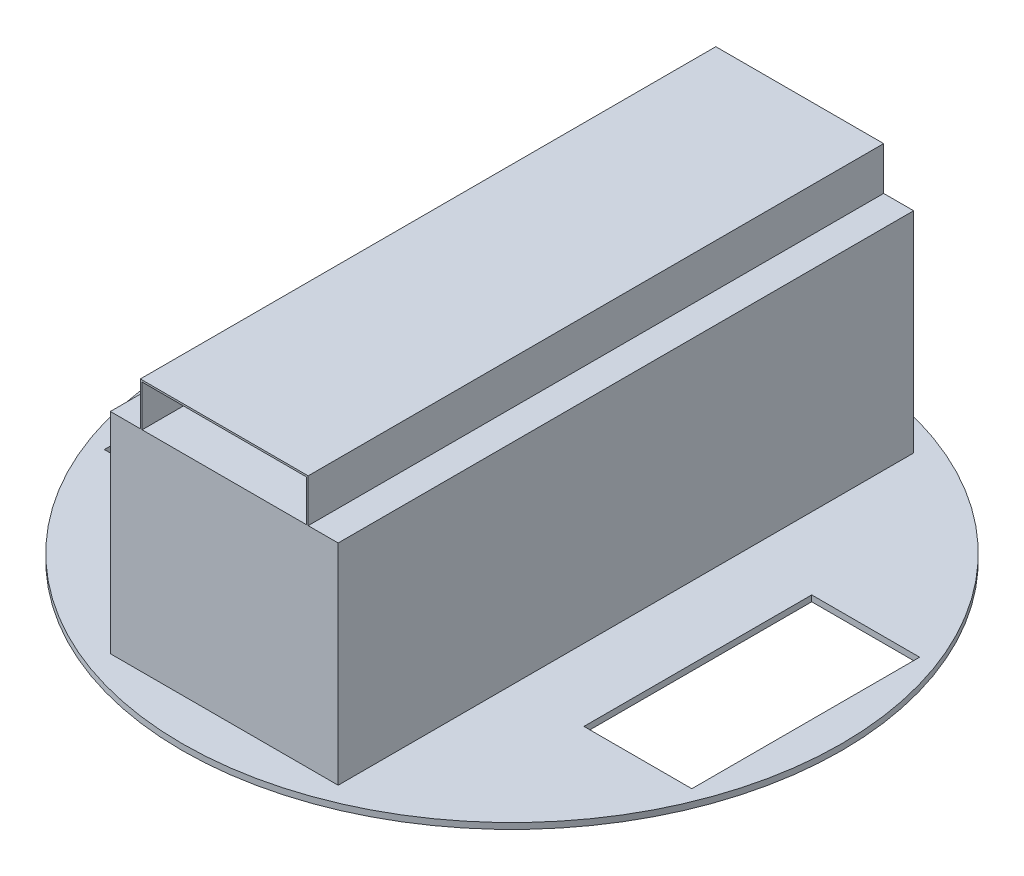
SolidWorks part; units mm, degrees
ref_plane "前视基准面" through (0, 0, 0) normal (0, 0, 1) x (1, 0, 0)
ref_plane "上视基准面" through (0, 0, 0) normal (0, 1, 0) x (1, 0, 0)
ref_plane "右视基准面" through (0, 0, 0) normal (1, 0, 0) x (0, 0, -1)
other "Configuration Table"
sketch "草图1" plane through (0, 0, 0) normal (0, 1, 0) x (1, 0, 0)
  line L0 (-275, 0) -> (275, 0) construction
  line L1 (0, 275) -> (0, -275) construction
  line L2 (0, 275) -> (-238.157, -137.5) construction
  line L3 (-238.157, -137.5) -> (238.157, -137.5) construction
  line L4 (238.157, -137.5) -> (0, 275) construction
  line L5 (186.1955, -107.5) -> (0, 215) construction
  line L6 (0, 215) -> (-186.1955, -107.5) construction
  line L7 (-186.1955, -107.5) -> (186.1955, -107.5) construction
  line L9 (-235, 85) -> (-165, 85) construction
  line L10 (-235, 85) -> (-235, -85) construction
  line L11 (-235, -85) -> (-165, -85) construction
  line L12 (-165, 85) -> (-165, -85) construction
  line L13 (-235, 85) -> (-165, -85) construction
  line L14 (-235, -85) -> (-165, 85) construction
  line L18 (0, 0) -> (-163.0598, -140.1303)
  line L19 (165, 85) -> (235, 85) construction
  line L20 (165, 85) -> (165, -85) construction
  line L21 (165, -85) -> (235, -85) construction
  line L22 (235, 85) -> (235, -85) construction
  line L23 (165, 85) -> (235, -85) construction
  line L24 (165, -85) -> (235, 85) construction
  line L25 (-186.1955, -107.5) -> (-163.0598, -140.1303)
  line L26 (-245, 95) -> (-245, -95)
  line L27 (-245, -95) -> (-155, -95)
  line L28 (-155, 95) -> (-155, -95)
  line L29 (-245, 95) -> (-155, 95)
  line L30 (155, 95) -> (155, -95)
  line L31 (155, -95) -> (245, -95)
  line L32 (245, 95) -> (245, -95)
  line L33 (155, 95) -> (245, 95)
  line L35 (-95, 240) -> (95, 240)
  line L36 (-95, 240) -> (-95, -240)
  line L37 (-95, -240) -> (95, -240)
  line L38 (95, 240) -> (95, -240)
  line L39 (-95, 240) -> (95, -240) construction
  line L40 (-95, -240) -> (95, 240) construction
  circle A0 centre (0, 0) radius 275
  circle A2 centre (0, 0) radius 215 construction
  point P10 (200, 0)
  point P13 (-200, 0)
  dimension "D1" = 550
  dimension "D2" = 60
  dimension "D3" = 170
  dimension "D5" = 70
  dimension "D6" = 75
  dimension "D7" = 75
  dimension "D8" = 170
  dimension "D9" = 70
  dimension "D10" = 10
  dimension "D11" = 10
  dimension "D12" = 190
  dimension "D13" = 480
  dimension "D4" = 30
extrude "凸台-拉伸1" add sketch "草图1" along normal blind 5 contours A0 L30 L33 L32 L31 L26 L29 L28 L27 | L36 L35 L38 L37 region at (-267.2218, 0, 0)
extrude "凸台-拉伸2" add sketch "草图1<4>" along normal blind 180 contours L38 L35 L36 L37 region at (0, 0, -234.8376)
sketch "草图1<4>" plane through (0, 0, 0) normal (0, 1, 0) x (1, 0, 0) same geometry as "草图1"
sketch "草图2" plane through (0, 0, 240) normal (0, 0, 1) x (1, 0, 0)
  line L0 (-95, 180) -> (95, 180) construction
  line L1 (-95, 180) -> (95, 180) construction
  line L7 (-68.5, 214.5) -> (-68.5, 181.5)
  line L8 (-70, 216) -> (70, 216)
  line L9 (-70, 216) -> (-70, 180)
  line L10 (-70, 180) -> (70, 180) construction
  line L11 (70, 216) -> (70, 180)
  line L12 (-70, 216) -> (70, 180) construction
  line L13 (-70, 180) -> (70, 216) construction
  line L15 (68.5, 214.5) -> (68.5, 181.5)
  line L16 (-68.5, 214.5) -> (68.5, 214.5)
  line L17 (-68.5, 181.5) -> (68.5, 181.5) construction
  line L18 (-68.5, 181.5) -> (-68.5, 180)
  line L19 (68.5, 181.5) -> (68.5, 180)
  line L20 (-68.5, 180) -> (-70, 180)
  line L21 (68.5, 180) -> (70, 180)
  point P2 (0, 180)
  point P3 (0, 198)
  dimension "D1" = 140
  dimension "D2" = 36
  dimension "D3" = 1.5
extrude "凸台-拉伸3" add sketch "草图2" against normal up to surface (480 mm away) contours L8 L11 L21 L19 L15 L16 L7 L18 L20 L9 up to face at (0, 92.5, -240)
sketch "草图4" [suppressed] plane through (0, 216, 0) normal (0, 1, 0) x (1, 0, 0)
  line L1 (95, -240) -> (-95, -240) construction
  line L2 (-70, 240) -> (-70, -240) construction
  circle A0 centre (-66, -235) radius 1.5
  circle A1 centre (-60, -235) radius 1.5
  circle A2 centre (-54, -235) radius 1.5
  circle A3 centre (-48, -235) radius 1.5
  circle A4 centre (-42, -235) radius 1.5
  circle A5 centre (-36, -235) radius 1.5
  circle A6 centre (-30, -235) radius 1.5
  circle A7 centre (-24, -235) radius 1.5
  circle A8 centre (-18, -235) radius 1.5
  circle A9 centre (-12, -235) radius 1.5
  circle A10 centre (-6, -235) radius 1.5
  circle A11 centre (0, -235) radius 1.5
  circle A12 centre (6, -235) radius 1.5
  circle A13 centre (12, -235) radius 1.5
  circle A14 centre (18, -235) radius 1.5
  circle A15 centre (24, -235) radius 1.5
  circle A16 centre (30, -235) radius 1.5
  circle A17 centre (36, -235) radius 1.5
  circle A18 centre (42, -235) radius 1.5
  circle A19 centre (48, -235) radius 1.5
  circle A20 centre (54, -235) radius 1.5
  circle A21 centre (60, -235) radius 1.5
  circle A22 centre (66, -235) radius 1.5
  circle A23 centre (-63.0019, -232.0019) radius 1.5
  circle A24 centre (-57.0019, -232.0019) radius 1.5
  circle A25 centre (-51.0019, -232.0019) radius 1.5
  circle A26 centre (-45.0019, -232.0019) radius 1.5
  circle A27 centre (-39.0019, -232.0019) radius 1.5
  circle A28 centre (-33.0019, -232.0019) radius 1.5
  circle A29 centre (-27.0019, -232.0019) radius 1.5
  circle A30 centre (-21.0019, -232.0019) radius 1.5
  circle A31 centre (-15.0019, -232.0019) radius 1.5
  circle A32 centre (-9.0019, -232.0019) radius 1.5
  circle A33 centre (-3.0019, -232.0019) radius 1.5
  circle A34 centre (2.9981, -232.0019) radius 1.5
  circle A35 centre (8.9981, -232.0019) radius 1.5
  circle A36 centre (14.9981, -232.0019) radius 1.5
  circle A37 centre (20.9981, -232.0019) radius 1.5
  circle A38 centre (26.9981, -232.0019) radius 1.5
  circle A39 centre (32.9981, -232.0019) radius 1.5
  circle A40 centre (38.9981, -232.0019) radius 1.5
  circle A41 centre (44.9981, -232.0019) radius 1.5
  circle A42 centre (50.9981, -232.0019) radius 1.5
  circle A43 centre (56.9981, -232.0019) radius 1.5
  circle A44 centre (62.9981, -232.0019) radius 1.5
  circle A46 centre (68.9981, -232.0019) radius 1.5 [skipped]
  circle A47 centre (-66, -229) radius 1.5
  circle A48 centre (-60, -229) radius 1.5
  circle A49 centre (-54, -229) radius 1.5
  circle A50 centre (-48, -229) radius 1.5
  circle A51 centre (-42, -229) radius 1.5
  circle A52 centre (-36, -229) radius 1.5
  circle A53 centre (-30, -229) radius 1.5
  circle A54 centre (-24, -229) radius 1.5
  circle A55 centre (-18, -229) radius 1.5
  circle A56 centre (-12, -229) radius 1.5
  circle A57 centre (-6, -229) radius 1.5
  circle A58 centre (0, -229) radius 1.5
  circle A59 centre (6, -229) radius 1.5
  circle A60 centre (12, -229) radius 1.5
  circle A61 centre (18, -229) radius 1.5
  circle A62 centre (24, -229) radius 1.5
  circle A63 centre (30, -229) radius 1.5
  circle A64 centre (36, -229) radius 1.5
  circle A65 centre (42, -229) radius 1.5
  circle A66 centre (48, -229) radius 1.5
  circle A67 centre (54, -229) radius 1.5
  circle A68 centre (60, -229) radius 1.5
  circle A69 centre (66, -229) radius 1.5
  circle A70 centre (-63.0019, -226.0019) radius 1.5
  circle A71 centre (-57.0019, -226.0019) radius 1.5
  circle A72 centre (-51.0019, -226.0019) radius 1.5
  circle A73 centre (-45.0019, -226.0019) radius 1.5
  circle A74 centre (-39.0019, -226.0019) radius 1.5
  circle A75 centre (-33.0019, -226.0019) radius 1.5
  circle A76 centre (-27.0019, -226.0019) radius 1.5
  circle A77 centre (-21.0019, -226.0019) radius 1.5
  circle A78 centre (-15.0019, -226.0019) radius 1.5
  circle A79 centre (-9.0019, -226.0019) radius 1.5
  circle A80 centre (-3.0019, -226.0019) radius 1.5
  circle A81 centre (2.9981, -226.0019) radius 1.5
  circle A82 centre (8.9981, -226.0019) radius 1.5
  circle A83 centre (14.9981, -226.0019) radius 1.5
  circle A84 centre (20.9981, -226.0019) radius 1.5
  circle A85 centre (26.9981, -226.0019) radius 1.5
  circle A86 centre (32.9981, -226.0019) radius 1.5
  circle A87 centre (38.9981, -226.0019) radius 1.5
  circle A88 centre (44.9981, -226.0019) radius 1.5
  circle A89 centre (50.9981, -226.0019) radius 1.5
  circle A90 centre (56.9981, -226.0019) radius 1.5
  circle A91 centre (62.9981, -226.0019) radius 1.5
  circle A92 centre (-66, -223) radius 1.5
  circle A93 centre (-60, -223) radius 1.5
  circle A94 centre (-54, -223) radius 1.5
  circle A95 centre (-48, -223) radius 1.5
  circle A96 centre (-42, -223) radius 1.5
  circle A97 centre (-36, -223) radius 1.5
  circle A98 centre (-30, -223) radius 1.5
  circle A99 centre (-24, -223) radius 1.5
  circle A100 centre (-18, -223) radius 1.5
  circle A101 centre (-12, -223) radius 1.5
  circle A102 centre (-6, -223) radius 1.5
  circle A103 centre (0, -223) radius 1.5
  circle A104 centre (6, -223) radius 1.5
  circle A105 centre (12, -223) radius 1.5
  circle A106 centre (18, -223) radius 1.5
  circle A107 centre (24, -223) radius 1.5
  circle A108 centre (30, -223) radius 1.5
  circle A109 centre (36, -223) radius 1.5
  circle A110 centre (42, -223) radius 1.5
  circle A111 centre (48, -223) radius 1.5
  circle A112 centre (54, -223) radius 1.5
  circle A113 centre (60, -223) radius 1.5
  circle A114 centre (66, -223) radius 1.5
  circle A115 centre (-63.0019, -220.0019) radius 1.5
  circle A116 centre (-57.0019, -220.0019) radius 1.5
  circle A117 centre (-51.0019, -220.0019) radius 1.5
  circle A118 centre (-45.0019, -220.0019) radius 1.5
  circle A119 centre (-39.0019, -220.0019) radius 1.5
  circle A120 centre (-33.0019, -220.0019) radius 1.5
  circle A121 centre (-27.0019, -220.0019) radius 1.5
  circle A122 centre (-21.0019, -220.0019) radius 1.5
  circle A123 centre (-15.0019, -220.0019) radius 1.5
  circle A124 centre (-9.0019, -220.0019) radius 1.5
  circle A125 centre (-3.0019, -220.0019) radius 1.5
  circle A126 centre (2.9981, -220.0019) radius 1.5
  circle A127 centre (8.9981, -220.0019) radius 1.5
  circle A128 centre (14.9981, -220.0019) radius 1.5
  circle A129 centre (20.9981, -220.0019) radius 1.5
  circle A130 centre (26.9981, -220.0019) radius 1.5
  circle A131 centre (32.9981, -220.0019) radius 1.5
  circle A132 centre (38.9981, -220.0019) radius 1.5
  circle A133 centre (44.9981, -220.0019) radius 1.5
  circle A134 centre (50.9981, -220.0019) radius 1.5
  circle A135 centre (56.9981, -220.0019) radius 1.5
  circle A136 centre (62.9981, -220.0019) radius 1.5
  circle A137 centre (-66, -217) radius 1.5
  circle A138 centre (-60, -217) radius 1.5
  circle A139 centre (-54, -217) radius 1.5
  circle A140 centre (-48, -217) radius 1.5
  circle A141 centre (-42, -217) radius 1.5
  circle A142 centre (-36, -217) radius 1.5
  circle A143 centre (-30, -217) radius 1.5
  circle A144 centre (-24, -217) radius 1.5
  circle A145 centre (-18, -217) radius 1.5
  circle A146 centre (-12, -217) radius 1.5
  circle A147 centre (-6, -217) radius 1.5
  circle A148 centre (0, -217) radius 1.5
  circle A149 centre (6, -217) radius 1.5
  circle A150 centre (12, -217) radius 1.5
  circle A151 centre (18, -217) radius 1.5
  circle A152 centre (24, -217) radius 1.5
  circle A153 centre (30, -217) radius 1.5
  circle A154 centre (36, -217) radius 1.5
  circle A155 centre (42, -217) radius 1.5
  circle A156 centre (48, -217) radius 1.5
  circle A157 centre (54, -217) radius 1.5
  circle A158 centre (60, -217) radius 1.5
  circle A159 centre (66, -217) radius 1.5
  circle A160 centre (-63.0019, -214.0019) radius 1.5
  circle A161 centre (-57.0019, -214.0019) radius 1.5
  circle A162 centre (-51.0019, -214.0019) radius 1.5
  circle A163 centre (-45.0019, -214.0019) radius 1.5
  circle A164 centre (-39.0019, -214.0019) radius 1.5
  circle A165 centre (-33.0019, -214.0019) radius 1.5
  circle A166 centre (-27.0019, -214.0019) radius 1.5
  circle A167 centre (-21.0019, -214.0019) radius 1.5
  circle A168 centre (-15.0019, -214.0019) radius 1.5
  circle A169 centre (-9.0019, -214.0019) radius 1.5
  circle A170 centre (-3.0019, -214.0019) radius 1.5
  circle A171 centre (2.9981, -214.0019) radius 1.5
  circle A172 centre (8.9981, -214.0019) radius 1.5
  circle A173 centre (14.9981, -214.0019) radius 1.5
  circle A174 centre (20.9981, -214.0019) radius 1.5
  circle A175 centre (26.9981, -214.0019) radius 1.5
  circle A176 centre (32.9981, -214.0019) radius 1.5
  circle A177 centre (38.9981, -214.0019) radius 1.5
  circle A178 centre (44.9981, -214.0019) radius 1.5
  circle A179 centre (50.9981, -214.0019) radius 1.5
  circle A180 centre (56.9981, -214.0019) radius 1.5
  circle A181 centre (62.9981, -214.0019) radius 1.5
  circle A182 centre (-66, -211) radius 1.5
  circle A183 centre (-60, -211) radius 1.5
  circle A184 centre (-54, -211) radius 1.5
  circle A185 centre (-48, -211) radius 1.5
  circle A186 centre (-42, -211) radius 1.5
  circle A187 centre (-36, -211) radius 1.5
  circle A188 centre (-30, -211) radius 1.5
  circle A189 centre (-24, -211) radius 1.5
  circle A190 centre (-18, -211) radius 1.5
  circle A191 centre (-12, -211) radius 1.5
  circle A192 centre (-6, -211) radius 1.5
  circle A193 centre (0, -211) radius 1.5
  circle A194 centre (6, -211) radius 1.5
  circle A195 centre (12, -211) radius 1.5
  circle A196 centre (18, -211) radius 1.5
  circle A197 centre (24, -211) radius 1.5
  circle A198 centre (30, -211) radius 1.5
  circle A199 centre (36, -211) radius 1.5
  circle A200 centre (42, -211) radius 1.5
  circle A201 centre (48, -211) radius 1.5
  circle A202 centre (54, -211) radius 1.5
  circle A203 centre (60, -211) radius 1.5
  circle A204 centre (66, -211) radius 1.5
  circle A205 centre (-63.0019, -208.0019) radius 1.5
  circle A206 centre (-57.0019, -208.0019) radius 1.5
  circle A207 centre (-51.0019, -208.0019) radius 1.5
  circle A208 centre (-45.0019, -208.0019) radius 1.5
  circle A209 centre (-39.0019, -208.0019) radius 1.5
  circle A210 centre (-33.0019, -208.0019) radius 1.5
  circle A211 centre (-27.0019, -208.0019) radius 1.5
  circle A212 centre (-21.0019, -208.0019) radius 1.5
  circle A213 centre (-15.0019, -208.0019) radius 1.5
  circle A214 centre (-9.0019, -208.0019) radius 1.5
  circle A215 centre (-3.0019, -208.0019) radius 1.5
  circle A216 centre (2.9981, -208.0019) radius 1.5
  circle A217 centre (8.9981, -208.0019) radius 1.5
  circle A218 centre (14.9981, -208.0019) radius 1.5
  circle A219 centre (20.9981, -208.0019) radius 1.5
  circle A220 centre (26.9981, -208.0019) radius 1.5
  circle A221 centre (32.9981, -208.0019) radius 1.5
  circle A222 centre (38.9981, -208.0019) radius 1.5
  circle A223 centre (44.9981, -208.0019) radius 1.5
  circle A224 centre (50.9981, -208.0019) radius 1.5
  circle A225 centre (56.9981, -208.0019) radius 1.5
  circle A226 centre (62.9981, -208.0019) radius 1.5
  circle A227 centre (-66, -205) radius 1.5
  circle A228 centre (-60, -205) radius 1.5
  circle A229 centre (-54, -205) radius 1.5
  circle A230 centre (-48, -205) radius 1.5
  circle A231 centre (-42, -205) radius 1.5
  circle A232 centre (-36, -205) radius 1.5
  circle A233 centre (-30, -205) radius 1.5
  circle A234 centre (-24, -205) radius 1.5
  circle A235 centre (-18, -205) radius 1.5
  circle A236 centre (-12, -205) radius 1.5
  circle A237 centre (-6, -205) radius 1.5
  circle A238 centre (0, -205) radius 1.5
  circle A239 centre (6, -205) radius 1.5
  circle A240 centre (12, -205) radius 1.5
  circle A241 centre (18, -205) radius 1.5
  circle A242 centre (24, -205) radius 1.5
  circle A243 centre (30, -205) radius 1.5
  circle A244 centre (36, -205) radius 1.5
  circle A245 centre (42, -205) radius 1.5
  circle A246 centre (48, -205) radius 1.5
  circle A247 centre (54, -205) radius 1.5
  circle A248 centre (60, -205) radius 1.5
  circle A249 centre (66, -205) radius 1.5
  circle A250 centre (-63.0019, -202.0019) radius 1.5
  circle A251 centre (-57.0019, -202.0019) radius 1.5
  circle A252 centre (-51.0019, -202.0019) radius 1.5
  circle A253 centre (-45.0019, -202.0019) radius 1.5
  circle A254 centre (-39.0019, -202.0019) radius 1.5
  circle A255 centre (-33.0019, -202.0019) radius 1.5
  circle A256 centre (-27.0019, -202.0019) radius 1.5
  circle A257 centre (-21.0019, -202.0019) radius 1.5
  circle A258 centre (-15.0019, -202.0019) radius 1.5
  circle A259 centre (-9.0019, -202.0019) radius 1.5
  circle A260 centre (-3.0019, -202.0019) radius 1.5
  circle A261 centre (2.9981, -202.0019) radius 1.5
  circle A262 centre (8.9981, -202.0019) radius 1.5
  circle A263 centre (14.9981, -202.0019) radius 1.5
  circle A264 centre (20.9981, -202.0019) radius 1.5
  circle A265 centre (26.9981, -202.0019) radius 1.5
  circle A266 centre (32.9981, -202.0019) radius 1.5
  circle A267 centre (38.9981, -202.0019) radius 1.5
  circle A268 centre (44.9981, -202.0019) radius 1.5
  circle A269 centre (50.9981, -202.0019) radius 1.5
  circle A270 centre (56.9981, -202.0019) radius 1.5
  circle A271 centre (62.9981, -202.0019) radius 1.5
  circle A272 centre (-66, -199) radius 1.5
  circle A273 centre (-60, -199) radius 1.5
  circle A274 centre (-54, -199) radius 1.5
  circle A275 centre (-48, -199) radius 1.5
  circle A276 centre (-42, -199) radius 1.5
  circle A277 centre (-36, -199) radius 1.5
  circle A278 centre (-30, -199) radius 1.5
  circle A279 centre (-24, -199) radius 1.5
  circle A280 centre (-18, -199) radius 1.5
  circle A281 centre (-12, -199) radius 1.5
  circle A282 centre (-6, -199) radius 1.5
  circle A283 centre (0, -199) radius 1.5
  circle A284 centre (6, -199) radius 1.5
  circle A285 centre (12, -199) radius 1.5
  circle A286 centre (18, -199) radius 1.5
  circle A287 centre (24, -199) radius 1.5
  circle A288 centre (30, -199) radius 1.5
  circle A289 centre (36, -199) radius 1.5
  circle A290 centre (42, -199) radius 1.5
  circle A291 centre (48, -199) radius 1.5
  circle A292 centre (54, -199) radius 1.5
  circle A293 centre (60, -199) radius 1.5
  circle A294 centre (66, -199) radius 1.5
  circle A295 centre (-63.0019, -196.0019) radius 1.5
  circle A296 centre (-57.0019, -196.0019) radius 1.5
  circle A297 centre (-51.0019, -196.0019) radius 1.5
  circle A298 centre (-45.0019, -196.0019) radius 1.5
  circle A299 centre (-39.0019, -196.0019) radius 1.5
  circle A300 centre (-33.0019, -196.0019) radius 1.5
  circle A301 centre (-27.0019, -196.0019) radius 1.5
  circle A302 centre (-21.0019, -196.0019) radius 1.5
  circle A303 centre (-15.0019, -196.0019) radius 1.5
  circle A304 centre (-9.0019, -196.0019) radius 1.5
  circle A305 centre (-3.0019, -196.0019) radius 1.5
  circle A306 centre (2.9981, -196.0019) radius 1.5
  circle A307 centre (8.9981, -196.0019) radius 1.5
  circle A308 centre (14.9981, -196.0019) radius 1.5
  circle A309 centre (20.9981, -196.0019) radius 1.5
  circle A310 centre (26.9981, -196.0019) radius 1.5
  circle A311 centre (32.9981, -196.0019) radius 1.5
  circle A312 centre (38.9981, -196.0019) radius 1.5
  circle A313 centre (44.9981, -196.0019) radius 1.5
  circle A314 centre (50.9981, -196.0019) radius 1.5
  circle A315 centre (56.9981, -196.0019) radius 1.5
  circle A316 centre (62.9981, -196.0019) radius 1.5
  circle A317 centre (-66, -193) radius 1.5
  circle A318 centre (-60, -193) radius 1.5
  circle A319 centre (-54, -193) radius 1.5
  circle A320 centre (-48, -193) radius 1.5
  circle A321 centre (-42, -193) radius 1.5
  circle A322 centre (-36, -193) radius 1.5
  circle A323 centre (-30, -193) radius 1.5
  circle A324 centre (-24, -193) radius 1.5
  circle A325 centre (-18, -193) radius 1.5
  circle A326 centre (-12, -193) radius 1.5
  circle A327 centre (-6, -193) radius 1.5
  circle A328 centre (0, -193) radius 1.5
  circle A329 centre (6, -193) radius 1.5
  circle A330 centre (12, -193) radius 1.5
  circle A331 centre (18, -193) radius 1.5
  circle A332 centre (24, -193) radius 1.5
  circle A333 centre (30, -193) radius 1.5
  circle A334 centre (36, -193) radius 1.5
  circle A335 centre (42, -193) radius 1.5
  circle A336 centre (48, -193) radius 1.5
  circle A337 centre (54, -193) radius 1.5
  circle A338 centre (60, -193) radius 1.5
  circle A339 centre (66, -193) radius 1.5
  circle A340 centre (-63.0019, -190.0019) radius 1.5
  circle A341 centre (-57.0019, -190.0019) radius 1.5
  circle A342 centre (-51.0019, -190.0019) radius 1.5
  circle A343 centre (-45.0019, -190.0019) radius 1.5
  circle A344 centre (-39.0019, -190.0019) radius 1.5
  circle A345 centre (-33.0019, -190.0019) radius 1.5
  circle A346 centre (-27.0019, -190.0019) radius 1.5
  circle A347 centre (-21.0019, -190.0019) radius 1.5
  circle A348 centre (-15.0019, -190.0019) radius 1.5
  circle A349 centre (-9.0019, -190.0019) radius 1.5
  circle A350 centre (-3.0019, -190.0019) radius 1.5
  circle A351 centre (2.9981, -190.0019) radius 1.5
  circle A352 centre (8.9981, -190.0019) radius 1.5
  circle A353 centre (14.9981, -190.0019) radius 1.5
  circle A354 centre (20.9981, -190.0019) radius 1.5
  circle A355 centre (26.9981, -190.0019) radius 1.5
  circle A356 centre (32.9981, -190.0019) radius 1.5
  circle A357 centre (38.9981, -190.0019) radius 1.5
  circle A358 centre (44.9981, -190.0019) radius 1.5
  circle A359 centre (50.9981, -190.0019) radius 1.5
  circle A360 centre (56.9981, -190.0019) radius 1.5
  circle A361 centre (62.9981, -190.0019) radius 1.5
  circle A362 centre (-66, -187) radius 1.5
  circle A363 centre (-60, -187) radius 1.5
  circle A364 centre (-54, -187) radius 1.5
  circle A365 centre (-48, -187) radius 1.5
  circle A366 centre (-42, -187) radius 1.5
  circle A367 centre (-36, -187) radius 1.5
  circle A368 centre (-30, -187) radius 1.5
  circle A369 centre (-24, -187) radius 1.5
  circle A370 centre (-18, -187) radius 1.5
  circle A371 centre (-12, -187) radius 1.5
  circle A372 centre (-6, -187) radius 1.5
  circle A373 centre (0, -187) radius 1.5
  circle A374 centre (6, -187) radius 1.5
  circle A375 centre (12, -187) radius 1.5
  circle A376 centre (18, -187) radius 1.5
  circle A377 centre (24, -187) radius 1.5
  circle A378 centre (30, -187) radius 1.5
  circle A379 centre (36, -187) radius 1.5
  circle A380 centre (42, -187) radius 1.5
  circle A381 centre (48, -187) radius 1.5
  circle A382 centre (54, -187) radius 1.5
  circle A383 centre (60, -187) radius 1.5
  circle A384 centre (66, -187) radius 1.5
  circle A385 centre (-63.0019, -184.0019) radius 1.5
  circle A386 centre (-57.0019, -184.0019) radius 1.5
  circle A387 centre (-51.0019, -184.0019) radius 1.5
  circle A388 centre (-45.0019, -184.0019) radius 1.5
  circle A389 centre (-39.0019, -184.0019) radius 1.5
  circle A390 centre (-33.0019, -184.0019) radius 1.5
  circle A391 centre (-27.0019, -184.0019) radius 1.5
  circle A392 centre (-21.0019, -184.0019) radius 1.5
  circle A393 centre (-15.0019, -184.0019) radius 1.5
  circle A394 centre (-9.0019, -184.0019) radius 1.5
  circle A395 centre (-3.0019, -184.0019) radius 1.5
  circle A396 centre (2.9981, -184.0019) radius 1.5
  circle A397 centre (8.9981, -184.0019) radius 1.5
  circle A398 centre (14.9981, -184.0019) radius 1.5
  circle A399 centre (20.9981, -184.0019) radius 1.5
  circle A400 centre (26.9981, -184.0019) radius 1.5
  circle A401 centre (32.9981, -184.0019) radius 1.5
  circle A402 centre (38.9981, -184.0019) radius 1.5
  circle A403 centre (44.9981, -184.0019) radius 1.5
  circle A404 centre (50.9981, -184.0019) radius 1.5
  circle A405 centre (56.9981, -184.0019) radius 1.5
  circle A406 centre (62.9981, -184.0019) radius 1.5
  circle A407 centre (-66, -181) radius 1.5
  circle A408 centre (-60, -181) radius 1.5
  circle A409 centre (-54, -181) radius 1.5
  circle A410 centre (-48, -181) radius 1.5
  circle A411 centre (-42, -181) radius 1.5
  circle A412 centre (-36, -181) radius 1.5
  circle A413 centre (-30, -181) radius 1.5
  circle A414 centre (-24, -181) radius 1.5
  circle A415 centre (-18, -181) radius 1.5
  circle A416 centre (-12, -181) radius 1.5
  circle A417 centre (-6, -181) radius 1.5
  circle A418 centre (0, -181) radius 1.5
  circle A419 centre (6, -181) radius 1.5
  circle A420 centre (12, -181) radius 1.5
  circle A421 centre (18, -181) radius 1.5
  circle A422 centre (24, -181) radius 1.5
  circle A423 centre (30, -181) radius 1.5
  circle A424 centre (36, -181) radius 1.5
  circle A425 centre (42, -181) radius 1.5
  circle A426 centre (48, -181) radius 1.5
  circle A427 centre (54, -181) radius 1.5
  circle A428 centre (60, -181) radius 1.5
  circle A429 centre (66, -181) radius 1.5
  circle A430 centre (-63.0019, -178.0019) radius 1.5
  circle A431 centre (-57.0019, -178.0019) radius 1.5
  circle A432 centre (-51.0019, -178.0019) radius 1.5
  circle A433 centre (-45.0019, -178.0019) radius 1.5
  circle A434 centre (-39.0019, -178.0019) radius 1.5
  circle A435 centre (-33.0019, -178.0019) radius 1.5
  circle A436 centre (-27.0019, -178.0019) radius 1.5
  circle A437 centre (-21.0019, -178.0019) radius 1.5
  circle A438 centre (-15.0019, -178.0019) radius 1.5
  circle A439 centre (-9.0019, -178.0019) radius 1.5
  circle A440 centre (-3.0019, -178.0019) radius 1.5
  circle A441 centre (2.9981, -178.0019) radius 1.5
  circle A442 centre (8.9981, -178.0019) radius 1.5
  circle A443 centre (14.9981, -178.0019) radius 1.5
  circle A444 centre (20.9981, -178.0019) radius 1.5
  circle A445 centre (26.9981, -178.0019) radius 1.5
  circle A446 centre (32.9981, -178.0019) radius 1.5
  circle A447 centre (38.9981, -178.0019) radius 1.5
  circle A448 centre (44.9981, -178.0019) radius 1.5
  circle A449 centre (50.9981, -178.0019) radius 1.5
  circle A450 centre (56.9981, -178.0019) radius 1.5
  circle A451 centre (62.9981, -178.0019) radius 1.5
  circle A452 centre (-66, -175) radius 1.5
  circle A453 centre (-60, -175) radius 1.5
  circle A454 centre (-54, -175) radius 1.5
  circle A455 centre (-48, -175) radius 1.5
  circle A456 centre (-42, -175) radius 1.5
  circle A457 centre (-36, -175) radius 1.5
  circle A458 centre (-30, -175) radius 1.5
  circle A459 centre (-24, -175) radius 1.5
  circle A460 centre (-18, -175) radius 1.5
  circle A461 centre (-12, -175) radius 1.5
  circle A462 centre (-6, -175) radius 1.5
  circle A463 centre (0, -175) radius 1.5
  circle A464 centre (6, -175) radius 1.5
  circle A465 centre (12, -175) radius 1.5
  circle A466 centre (18, -175) radius 1.5
  circle A467 centre (24, -175) radius 1.5
  circle A468 centre (30, -175) radius 1.5
  circle A469 centre (36, -175) radius 1.5
  circle A470 centre (42, -175) radius 1.5
  circle A471 centre (48, -175) radius 1.5
  circle A472 centre (54, -175) radius 1.5
  circle A473 centre (60, -175) radius 1.5
  circle A474 centre (66, -175) radius 1.5
  circle A475 centre (-63.0019, -172.0019) radius 1.5
  circle A476 centre (-57.0019, -172.0019) radius 1.5
  circle A477 centre (-51.0019, -172.0019) radius 1.5
  circle A478 centre (-45.0019, -172.0019) radius 1.5
  circle A479 centre (-39.0019, -172.0019) radius 1.5
  circle A480 centre (-33.0019, -172.0019) radius 1.5
  circle A481 centre (-27.0019, -172.0019) radius 1.5
  circle A482 centre (-21.0019, -172.0019) radius 1.5
  circle A483 centre (-15.0019, -172.0019) radius 1.5
  circle A484 centre (-9.0019, -172.0019) radius 1.5
  circle A485 centre (-3.0019, -172.0019) radius 1.5
  circle A486 centre (2.9981, -172.0019) radius 1.5
  circle A487 centre (8.9981, -172.0019) radius 1.5
  circle A488 centre (14.9981, -172.0019) radius 1.5
  circle A489 centre (20.9981, -172.0019) radius 1.5
  circle A490 centre (26.9981, -172.0019) radius 1.5
  circle A491 centre (32.9981, -172.0019) radius 1.5
  circle A492 centre (38.9981, -172.0019) radius 1.5
  circle A493 centre (44.9981, -172.0019) radius 1.5
  circle A494 centre (50.9981, -172.0019) radius 1.5
  circle A495 centre (56.9981, -172.0019) radius 1.5
  circle A496 centre (62.9981, -172.0019) radius 1.5
  circle A497 centre (-66, -169) radius 1.5
  circle A498 centre (-60, -169) radius 1.5
  circle A499 centre (-54, -169) radius 1.5
  circle A500 centre (-48, -169) radius 1.5
  circle A501 centre (-42, -169) radius 1.5
  circle A502 centre (-36, -169) radius 1.5
  circle A503 centre (-30, -169) radius 1.5
  circle A504 centre (-24, -169) radius 1.5
  circle A505 centre (-18, -169) radius 1.5
  circle A506 centre (-12, -169) radius 1.5
  circle A507 centre (-6, -169) radius 1.5
  circle A508 centre (0, -169) radius 1.5
  circle A509 centre (6, -169) radius 1.5
  circle A510 centre (12, -169) radius 1.5
  circle A511 centre (18, -169) radius 1.5
  circle A512 centre (24, -169) radius 1.5
  circle A513 centre (30, -169) radius 1.5
  circle A514 centre (36, -169) radius 1.5
  circle A515 centre (42, -169) radius 1.5
  circle A516 centre (48, -169) radius 1.5
  circle A517 centre (54, -169) radius 1.5
  circle A518 centre (60, -169) radius 1.5
  circle A519 centre (66, -169) radius 1.5
  circle A520 centre (-63.0019, -166.0019) radius 1.5
  circle A521 centre (-57.0019, -166.0019) radius 1.5
  circle A522 centre (-51.0019, -166.0019) radius 1.5
  circle A523 centre (-45.0019, -166.0019) radius 1.5
  circle A524 centre (-39.0019, -166.0019) radius 1.5
  circle A525 centre (-33.0019, -166.0019) radius 1.5
  circle A526 centre (-27.0019, -166.0019) radius 1.5
  circle A527 centre (-21.0019, -166.0019) radius 1.5
  circle A528 centre (-15.0019, -166.0019) radius 1.5
  circle A529 centre (-9.0019, -166.0019) radius 1.5
  circle A530 centre (-3.0019, -166.0019) radius 1.5
  circle A531 centre (2.9981, -166.0019) radius 1.5
  circle A532 centre (8.9981, -166.0019) radius 1.5
  circle A533 centre (14.9981, -166.0019) radius 1.5
  circle A534 centre (20.9981, -166.0019) radius 1.5
  circle A535 centre (26.9981, -166.0019) radius 1.5
  circle A536 centre (32.9981, -166.0019) radius 1.5
  circle A537 centre (38.9981, -166.0019) radius 1.5
  circle A538 centre (44.9981, -166.0019) radius 1.5
  circle A539 centre (50.9981, -166.0019) radius 1.5
  circle A540 centre (56.9981, -166.0019) radius 1.5
  circle A541 centre (62.9981, -166.0019) radius 1.5
  circle A542 centre (-66, -163) radius 1.5
  circle A543 centre (-60, -163) radius 1.5
  circle A544 centre (-54, -163) radius 1.5
  circle A545 centre (-48, -163) radius 1.5
  circle A546 centre (-42, -163) radius 1.5
  circle A547 centre (-36, -163) radius 1.5
  circle A548 centre (-30, -163) radius 1.5
  circle A549 centre (-24, -163) radius 1.5
  circle A550 centre (-18, -163) radius 1.5
  circle A551 centre (-12, -163) radius 1.5
  circle A552 centre (-6, -163) radius 1.5
  circle A553 centre (0, -163) radius 1.5
  circle A554 centre (6, -163) radius 1.5
  circle A555 centre (12, -163) radius 1.5
  circle A556 centre (18, -163) radius 1.5
  circle A557 centre (24, -163) radius 1.5
  circle A558 centre (30, -163) radius 1.5
  circle A559 centre (36, -163) radius 1.5
  circle A560 centre (42, -163) radius 1.5
  circle A561 centre (48, -163) radius 1.5
  circle A562 centre (54, -163) radius 1.5
  circle A563 centre (60, -163) radius 1.5
  circle A564 centre (66, -163) radius 1.5
  circle A565 centre (-63.0019, -160.0019) radius 1.5
  circle A566 centre (-57.0019, -160.0019) radius 1.5
  circle A567 centre (-51.0019, -160.0019) radius 1.5
  circle A568 centre (-45.0019, -160.0019) radius 1.5
  circle A569 centre (-39.0019, -160.0019) radius 1.5
  circle A570 centre (-33.0019, -160.0019) radius 1.5
  circle A571 centre (-27.0019, -160.0019) radius 1.5
  circle A572 centre (-21.0019, -160.0019) radius 1.5
  circle A573 centre (-15.0019, -160.0019) radius 1.5
  circle A574 centre (-9.0019, -160.0019) radius 1.5
  circle A575 centre (-3.0019, -160.0019) radius 1.5
  circle A576 centre (2.9981, -160.0019) radius 1.5
  circle A577 centre (8.9981, -160.0019) radius 1.5
  circle A578 centre (14.9981, -160.0019) radius 1.5
  circle A579 centre (20.9981, -160.0019) radius 1.5
  circle A580 centre (26.9981, -160.0019) radius 1.5
  circle A581 centre (32.9981, -160.0019) radius 1.5
  circle A582 centre (38.9981, -160.0019) radius 1.5
  circle A583 centre (44.9981, -160.0019) radius 1.5
  circle A584 centre (50.9981, -160.0019) radius 1.5
  circle A585 centre (56.9981, -160.0019) radius 1.5
  circle A586 centre (62.9981, -160.0019) radius 1.5
  circle A587 centre (-66, -157) radius 1.5
  circle A588 centre (-60, -157) radius 1.5
  circle A589 centre (-54, -157) radius 1.5
  circle A590 centre (-48, -157) radius 1.5
  circle A591 centre (-42, -157) radius 1.5
  circle A592 centre (-36, -157) radius 1.5
  circle A593 centre (-30, -157) radius 1.5
  circle A594 centre (-24, -157) radius 1.5
  circle A595 centre (-18, -157) radius 1.5
  circle A596 centre (-12, -157) radius 1.5
  circle A597 centre (-6, -157) radius 1.5
  circle A598 centre (0, -157) radius 1.5
  circle A599 centre (6, -157) radius 1.5
  circle A600 centre (12, -157) radius 1.5
  circle A601 centre (18, -157) radius 1.5
  circle A602 centre (24, -157) radius 1.5
  circle A603 centre (30, -157) radius 1.5
  circle A604 centre (36, -157) radius 1.5
  circle A605 centre (42, -157) radius 1.5
  circle A606 centre (48, -157) radius 1.5
  circle A607 centre (54, -157) radius 1.5
  circle A608 centre (60, -157) radius 1.5
  circle A609 centre (66, -157) radius 1.5
  circle A610 centre (-63.0019, -154.0019) radius 1.5
  circle A611 centre (-57.0019, -154.0019) radius 1.5
  circle A612 centre (-51.0019, -154.0019) radius 1.5
  circle A613 centre (-45.0019, -154.0019) radius 1.5
  circle A614 centre (-39.0019, -154.0019) radius 1.5
  circle A615 centre (-33.0019, -154.0019) radius 1.5
  circle A616 centre (-27.0019, -154.0019) radius 1.5
  circle A617 centre (-21.0019, -154.0019) radius 1.5
  circle A618 centre (-15.0019, -154.0019) radius 1.5
  circle A619 centre (-9.0019, -154.0019) radius 1.5
  circle A620 centre (-3.0019, -154.0019) radius 1.5
  circle A621 centre (2.9981, -154.0019) radius 1.5
  circle A622 centre (8.9981, -154.0019) radius 1.5
  circle A623 centre (14.9981, -154.0019) radius 1.5
  circle A624 centre (20.9981, -154.0019) radius 1.5
  circle A625 centre (26.9981, -154.0019) radius 1.5
  circle A626 centre (32.9981, -154.0019) radius 1.5
  circle A627 centre (38.9981, -154.0019) radius 1.5
  circle A628 centre (44.9981, -154.0019) radius 1.5
  circle A629 centre (50.9981, -154.0019) radius 1.5
  circle A630 centre (56.9981, -154.0019) radius 1.5
  circle A631 centre (62.9981, -154.0019) radius 1.5
  circle A632 centre (-66, -151) radius 1.5
  circle A633 centre (-60, -151) radius 1.5
  circle A634 centre (-54, -151) radius 1.5
  circle A635 centre (-48, -151) radius 1.5
  circle A636 centre (-42, -151) radius 1.5
  circle A637 centre (-36, -151) radius 1.5
  circle A638 centre (-30, -151) radius 1.5
  circle A639 centre (-24, -151) radius 1.5
  circle A640 centre (-18, -151) radius 1.5
  circle A641 centre (-12, -151) radius 1.5
  circle A642 centre (-6, -151) radius 1.5
  circle A643 centre (0, -151) radius 1.5
  circle A644 centre (6, -151) radius 1.5
  circle A645 centre (12, -151) radius 1.5
  circle A646 centre (18, -151) radius 1.5
  circle A647 centre (24, -151) radius 1.5
  circle A648 centre (30, -151) radius 1.5
  circle A649 centre (36, -151) radius 1.5
  circle A650 centre (42, -151) radius 1.5
  circle A651 centre (48, -151) radius 1.5
  circle A652 centre (54, -151) radius 1.5
  circle A653 centre (60, -151) radius 1.5
  circle A654 centre (66, -151) radius 1.5
  circle A655 centre (-63.0019, -148.0019) radius 1.5
  circle A656 centre (-57.0019, -148.0019) radius 1.5
  circle A657 centre (-51.0019, -148.0019) radius 1.5
  circle A658 centre (-45.0019, -148.0019) radius 1.5
  circle A659 centre (-39.0019, -148.0019) radius 1.5
  circle A660 centre (-33.0019, -148.0019) radius 1.5
  circle A661 centre (-27.0019, -148.0019) radius 1.5
  circle A662 centre (-21.0019, -148.0019) radius 1.5
  circle A663 centre (-15.0019, -148.0019) radius 1.5
  circle A664 centre (-9.0019, -148.0019) radius 1.5
  circle A665 centre (-3.0019, -148.0019) radius 1.5
  circle A666 centre (2.9981, -148.0019) radius 1.5
  circle A667 centre (8.9981, -148.0019) radius 1.5
  circle A668 centre (14.9981, -148.0019) radius 1.5
  circle A669 centre (20.9981, -148.0019) radius 1.5
  circle A670 centre (26.9981, -148.0019) radius 1.5
  circle A671 centre (32.9981, -148.0019) radius 1.5
  circle A672 centre (38.9981, -148.0019) radius 1.5
  circle A673 centre (44.9981, -148.0019) radius 1.5
  circle A674 centre (50.9981, -148.0019) radius 1.5
  circle A675 centre (56.9981, -148.0019) radius 1.5
  circle A676 centre (62.9981, -148.0019) radius 1.5
  circle A677 centre (-66, -145) radius 1.5
  circle A678 centre (-60, -145) radius 1.5
  circle A679 centre (-54, -145) radius 1.5
  circle A680 centre (-48, -145) radius 1.5
  circle A681 centre (-42, -145) radius 1.5
  circle A682 centre (-36, -145) radius 1.5
  circle A683 centre (-30, -145) radius 1.5
  circle A684 centre (-24, -145) radius 1.5
  circle A685 centre (-18, -145) radius 1.5
  circle A686 centre (-12, -145) radius 1.5
  circle A687 centre (-6, -145) radius 1.5
  circle A688 centre (0, -145) radius 1.5
  circle A689 centre (6, -145) radius 1.5
  circle A690 centre (12, -145) radius 1.5
  circle A691 centre (18, -145) radius 1.5
  circle A692 centre (24, -145) radius 1.5
  circle A693 centre (30, -145) radius 1.5
  circle A694 centre (36, -145) radius 1.5
  circle A695 centre (42, -145) radius 1.5
  circle A696 centre (48, -145) radius 1.5
  circle A697 centre (54, -145) radius 1.5
  circle A698 centre (60, -145) radius 1.5
  circle A699 centre (66, -145) radius 1.5
  circle A700 centre (-63.0019, -142.0019) radius 1.5
  circle A701 centre (-57.0019, -142.0019) radius 1.5
  circle A702 centre (-51.0019, -142.0019) radius 1.5
  circle A703 centre (-45.0019, -142.0019) radius 1.5
  circle A704 centre (-39.0019, -142.0019) radius 1.5
  circle A705 centre (-33.0019, -142.0019) radius 1.5
  circle A706 centre (-27.0019, -142.0019) radius 1.5
  circle A707 centre (-21.0019, -142.0019) radius 1.5
  circle A708 centre (-15.0019, -142.0019) radius 1.5
  circle A709 centre (-9.0019, -142.0019) radius 1.5
  circle A710 centre (-3.0019, -142.0019) radius 1.5
  circle A711 centre (2.9981, -142.0019) radius 1.5
  circle A712 centre (8.9981, -142.0019) radius 1.5
  circle A713 centre (14.9981, -142.0019) radius 1.5
  circle A714 centre (20.9981, -142.0019) radius 1.5
  circle A715 centre (26.9981, -142.0019) radius 1.5
  circle A716 centre (32.9981, -142.0019) radius 1.5
  circle A717 centre (38.9981, -142.0019) radius 1.5
  circle A718 centre (44.9981, -142.0019) radius 1.5
  circle A719 centre (50.9981, -142.0019) radius 1.5
  circle A720 centre (56.9981, -142.0019) radius 1.5
  circle A721 centre (62.9981, -142.0019) radius 1.5
  circle A722 centre (-66, -139) radius 1.5
  circle A723 centre (-60, -139) radius 1.5
  circle A724 centre (-54, -139) radius 1.5
  circle A725 centre (-48, -139) radius 1.5
  circle A726 centre (-42, -139) radius 1.5
  circle A727 centre (-36, -139) radius 1.5
  circle A728 centre (-30, -139) radius 1.5
  circle A729 centre (-24, -139) radius 1.5
  circle A730 centre (-18, -139) radius 1.5
  circle A731 centre (-12, -139) radius 1.5
  circle A732 centre (-6, -139) radius 1.5
  circle A733 centre (0, -139) radius 1.5
  circle A734 centre (6, -139) radius 1.5
  circle A735 centre (12, -139) radius 1.5
  circle A736 centre (18, -139) radius 1.5
  circle A737 centre (24, -139) radius 1.5
  circle A738 centre (30, -139) radius 1.5
  circle A739 centre (36, -139) radius 1.5
  circle A740 centre (42, -139) radius 1.5
  circle A741 centre (48, -139) radius 1.5
  circle A742 centre (54, -139) radius 1.5
  circle A743 centre (60, -139) radius 1.5
  circle A744 centre (66, -139) radius 1.5
  circle A745 centre (-63.0019, -136.0019) radius 1.5
  circle A746 centre (-57.0019, -136.0019) radius 1.5
  circle A747 centre (-51.0019, -136.0019) radius 1.5
  circle A748 centre (-45.0019, -136.0019) radius 1.5
  circle A749 centre (-39.0019, -136.0019) radius 1.5
  circle A750 centre (-33.0019, -136.0019) radius 1.5
  circle A751 centre (-27.0019, -136.0019) radius 1.5
  circle A752 centre (-21.0019, -136.0019) radius 1.5
  circle A753 centre (-15.0019, -136.0019) radius 1.5
  circle A754 centre (-9.0019, -136.0019) radius 1.5
  circle A755 centre (-3.0019, -136.0019) radius 1.5
  circle A756 centre (2.9981, -136.0019) radius 1.5
  circle A757 centre (8.9981, -136.0019) radius 1.5
  circle A758 centre (14.9981, -136.0019) radius 1.5
  circle A759 centre (20.9981, -136.0019) radius 1.5
  circle A760 centre (26.9981, -136.0019) radius 1.5
  circle A761 centre (32.9981, -136.0019) radius 1.5
  circle A762 centre (38.9981, -136.0019) radius 1.5
  circle A763 centre (44.9981, -136.0019) radius 1.5
  circle A764 centre (50.9981, -136.0019) radius 1.5
  circle A765 centre (56.9981, -136.0019) radius 1.5
  circle A766 centre (62.9981, -136.0019) radius 1.5
  circle A767 centre (-66, -133) radius 1.5
  circle A768 centre (-60, -133) radius 1.5
  circle A769 centre (-54, -133) radius 1.5
  circle A770 centre (-48, -133) radius 1.5
  circle A771 centre (-42, -133) radius 1.5
  circle A772 centre (-36, -133) radius 1.5
  circle A773 centre (-30, -133) radius 1.5
  circle A774 centre (-24, -133) radius 1.5
  circle A775 centre (-18, -133) radius 1.5
  circle A776 centre (-12, -133) radius 1.5
  circle A777 centre (-6, -133) radius 1.5
  circle A778 centre (0, -133) radius 1.5
  circle A779 centre (6, -133) radius 1.5
  circle A780 centre (12, -133) radius 1.5
  circle A781 centre (18, -133) radius 1.5
  circle A782 centre (24, -133) radius 1.5
  circle A783 centre (30, -133) radius 1.5
  circle A784 centre (36, -133) radius 1.5
  circle A785 centre (42, -133) radius 1.5
  circle A786 centre (48, -133) radius 1.5
  circle A787 centre (54, -133) radius 1.5
  circle A788 centre (60, -133) radius 1.5
  circle A789 centre (66, -133) radius 1.5
  circle A790 centre (-63.0019, -130.0019) radius 1.5
  circle A791 centre (-57.0019, -130.0019) radius 1.5
  circle A792 centre (-51.0019, -130.0019) radius 1.5
  circle A793 centre (-45.0019, -130.0019) radius 1.5
  circle A794 centre (-39.0019, -130.0019) radius 1.5
  circle A795 centre (-33.0019, -130.0019) radius 1.5
  circle A796 centre (-27.0019, -130.0019) radius 1.5
  circle A797 centre (-21.0019, -130.0019) radius 1.5
  circle A798 centre (-15.0019, -130.0019) radius 1.5
  circle A799 centre (-9.0019, -130.0019) radius 1.5
  circle A800 centre (-3.0019, -130.0019) radius 1.5
  circle A801 centre (2.9981, -130.0019) radius 1.5
  circle A802 centre (8.9981, -130.0019) radius 1.5
  circle A803 centre (14.9981, -130.0019) radius 1.5
  circle A804 centre (20.9981, -130.0019) radius 1.5
  circle A805 centre (26.9981, -130.0019) radius 1.5
  circle A806 centre (32.9981, -130.0019) radius 1.5
  circle A807 centre (38.9981, -130.0019) radius 1.5
  circle A808 centre (44.9981, -130.0019) radius 1.5
  circle A809 centre (50.9981, -130.0019) radius 1.5
  circle A810 centre (56.9981, -130.0019) radius 1.5
  circle A811 centre (62.9981, -130.0019) radius 1.5
  circle A812 centre (-66, -127) radius 1.5
  circle A813 centre (-60, -127) radius 1.5
  circle A814 centre (-54, -127) radius 1.5
  circle A815 centre (-48, -127) radius 1.5
  circle A816 centre (-42, -127) radius 1.5
  circle A817 centre (-36, -127) radius 1.5
  circle A818 centre (-30, -127) radius 1.5
  circle A819 centre (-24, -127) radius 1.5
  circle A820 centre (-18, -127) radius 1.5
  circle A821 centre (-12, -127) radius 1.5
  circle A822 centre (-6, -127) radius 1.5
  circle A823 centre (0, -127) radius 1.5
  circle A824 centre (6, -127) radius 1.5
  circle A825 centre (12, -127) radius 1.5
  circle A826 centre (18, -127) radius 1.5
  circle A827 centre (24, -127) radius 1.5
  circle A828 centre (30, -127) radius 1.5
  circle A829 centre (36, -127) radius 1.5
  circle A830 centre (42, -127) radius 1.5
  circle A831 centre (48, -127) radius 1.5
  circle A832 centre (54, -127) radius 1.5
  circle A833 centre (60, -127) radius 1.5
  circle A834 centre (66, -127) radius 1.5
  circle A835 centre (-63.0019, -124.0019) radius 1.5
  circle A836 centre (-57.0019, -124.0019) radius 1.5
  circle A837 centre (-51.0019, -124.0019) radius 1.5
  circle A838 centre (-45.0019, -124.0019) radius 1.5
  circle A839 centre (-39.0019, -124.0019) radius 1.5
  circle A840 centre (-33.0019, -124.0019) radius 1.5
  circle A841 centre (-27.0019, -124.0019) radius 1.5
  circle A842 centre (-21.0019, -124.0019) radius 1.5
  circle A843 centre (-15.0019, -124.0019) radius 1.5
  circle A844 centre (-9.0019, -124.0019) radius 1.5
  circle A845 centre (-3.0019, -124.0019) radius 1.5
  circle A846 centre (2.9981, -124.0019) radius 1.5
  circle A847 centre (8.9981, -124.0019) radius 1.5
  circle A848 centre (14.9981, -124.0019) radius 1.5
  circle A849 centre (20.9981, -124.0019) radius 1.5
  circle A850 centre (26.9981, -124.0019) radius 1.5
  circle A851 centre (32.9981, -124.0019) radius 1.5
  circle A852 centre (38.9981, -124.0019) radius 1.5
  circle A853 centre (44.9981, -124.0019) radius 1.5
  circle A854 centre (50.9981, -124.0019) radius 1.5
  circle A855 centre (56.9981, -124.0019) radius 1.5
  circle A856 centre (62.9981, -124.0019) radius 1.5
  circle A857 centre (-66, -121) radius 1.5
  circle A858 centre (-60, -121) radius 1.5
  circle A859 centre (-54, -121) radius 1.5
  circle A860 centre (-48, -121) radius 1.5
  circle A861 centre (-42, -121) radius 1.5
  circle A862 centre (-36, -121) radius 1.5
  circle A863 centre (-30, -121) radius 1.5
  circle A864 centre (-24, -121) radius 1.5
  circle A865 centre (-18, -121) radius 1.5
  circle A866 centre (-12, -121) radius 1.5
  circle A867 centre (-6, -121) radius 1.5
  circle A868 centre (0, -121) radius 1.5
  circle A869 centre (6, -121) radius 1.5
  circle A870 centre (12, -121) radius 1.5
  circle A871 centre (18, -121) radius 1.5
  circle A872 centre (24, -121) radius 1.5
  circle A873 centre (30, -121) radius 1.5
  circle A874 centre (36, -121) radius 1.5
  circle A875 centre (42, -121) radius 1.5
  circle A876 centre (48, -121) radius 1.5
  circle A877 centre (54, -121) radius 1.5
  circle A878 centre (60, -121) radius 1.5
  circle A879 centre (66, -121) radius 1.5
  circle A880 centre (-63.0019, -118.0019) radius 1.5
  circle A881 centre (-57.0019, -118.0019) radius 1.5
  circle A882 centre (-51.0019, -118.0019) radius 1.5
  circle A883 centre (-45.0019, -118.0019) radius 1.5
  circle A884 centre (-39.0019, -118.0019) radius 1.5
  circle A885 centre (-33.0019, -118.0019) radius 1.5
  circle A886 centre (-27.0019, -118.0019) radius 1.5
  circle A887 centre (-21.0019, -118.0019) radius 1.5
  circle A888 centre (-15.0019, -118.0019) radius 1.5
  circle A889 centre (-9.0019, -118.0019) radius 1.5
  circle A890 centre (-3.0019, -118.0019) radius 1.5
  circle A891 centre (2.9981, -118.0019) radius 1.5
  circle A892 centre (8.9981, -118.0019) radius 1.5
  circle A893 centre (14.9981, -118.0019) radius 1.5
  circle A894 centre (20.9981, -118.0019) radius 1.5
  circle A895 centre (26.9981, -118.0019) radius 1.5
  circle A896 centre (32.9981, -118.0019) radius 1.5
  circle A897 centre (38.9981, -118.0019) radius 1.5
  circle A898 centre (44.9981, -118.0019) radius 1.5
  circle A899 centre (50.9981, -118.0019) radius 1.5
  circle A900 centre (56.9981, -118.0019) radius 1.5
  circle A901 centre (62.9981, -118.0019) radius 1.5
  circle A902 centre (-66, -115) radius 1.5
  circle A903 centre (-60, -115) radius 1.5
  circle A904 centre (-54, -115) radius 1.5
  circle A905 centre (-48, -115) radius 1.5
  circle A906 centre (-42, -115) radius 1.5
  circle A907 centre (-36, -115) radius 1.5
  circle A908 centre (-30, -115) radius 1.5
  circle A909 centre (-24, -115) radius 1.5
  circle A910 centre (-18, -115) radius 1.5
  circle A911 centre (-12, -115) radius 1.5
  circle A912 centre (-6, -115) radius 1.5
  circle A913 centre (0, -115) radius 1.5
  circle A914 centre (6, -115) radius 1.5
  circle A915 centre (12, -115) radius 1.5
  circle A916 centre (18, -115) radius 1.5
  circle A917 centre (24, -115) radius 1.5
  circle A918 centre (30, -115) radius 1.5
  circle A919 centre (36, -115) radius 1.5
  circle A920 centre (42, -115) radius 1.5
  circle A921 centre (48, -115) radius 1.5
  circle A922 centre (54, -115) radius 1.5
  circle A923 centre (60, -115) radius 1.5
  circle A924 centre (66, -115) radius 1.5
  circle A925 centre (-63.0019, -112.0019) radius 1.5
  circle A926 centre (-57.0019, -112.0019) radius 1.5
  circle A927 centre (-51.0019, -112.0019) radius 1.5
  circle A928 centre (-45.0019, -112.0019) radius 1.5
  circle A929 centre (-39.0019, -112.0019) radius 1.5
  circle A930 centre (-33.0019, -112.0019) radius 1.5
  circle A931 centre (-27.0019, -112.0019) radius 1.5
  circle A932 centre (-21.0019, -112.0019) radius 1.5
  circle A933 centre (-15.0019, -112.0019) radius 1.5
  circle A934 centre (-9.0019, -112.0019) radius 1.5
  circle A935 centre (-3.0019, -112.0019) radius 1.5
  circle A936 centre (2.9981, -112.0019) radius 1.5
  circle A937 centre (8.9981, -112.0019) radius 1.5
  circle A938 centre (14.9981, -112.0019) radius 1.5
  circle A939 centre (20.9981, -112.0019) radius 1.5
  circle A940 centre (26.9981, -112.0019) radius 1.5
  circle A941 centre (32.9981, -112.0019) radius 1.5
  circle A942 centre (38.9981, -112.0019) radius 1.5
  circle A943 centre (44.9981, -112.0019) radius 1.5
  circle A944 centre (50.9981, -112.0019) radius 1.5
  circle A945 centre (56.9981, -112.0019) radius 1.5
  circle A946 centre (62.9981, -112.0019) radius 1.5
  circle A947 centre (-66, -109) radius 1.5
  circle A948 centre (-60, -109) radius 1.5
  circle A949 centre (-54, -109) radius 1.5
  circle A950 centre (-48, -109) radius 1.5
  circle A951 centre (-42, -109) radius 1.5
  circle A952 centre (-36, -109) radius 1.5
  circle A953 centre (-30, -109) radius 1.5
  circle A954 centre (-24, -109) radius 1.5
  circle A955 centre (-18, -109) radius 1.5
  circle A956 centre (-12, -109) radius 1.5
  circle A957 centre (-6, -109) radius 1.5
  circle A958 centre (0, -109) radius 1.5
  circle A959 centre (6, -109) radius 1.5
  circle A960 centre (12, -109) radius 1.5
  circle A961 centre (18, -109) radius 1.5
  circle A962 centre (24, -109) radius 1.5
  circle A963 centre (30, -109) radius 1.5
  circle A964 centre (36, -109) radius 1.5
  circle A965 centre (42, -109) radius 1.5
  circle A966 centre (48, -109) radius 1.5
  circle A967 centre (54, -109) radius 1.5
  circle A968 centre (60, -109) radius 1.5
  circle A969 centre (66, -109) radius 1.5
  circle A970 centre (-63.0019, -106.0019) radius 1.5
  circle A971 centre (-57.0019, -106.0019) radius 1.5
  circle A972 centre (-51.0019, -106.0019) radius 1.5
  circle A973 centre (-45.0019, -106.0019) radius 1.5
  circle A974 centre (-39.0019, -106.0019) radius 1.5
  circle A975 centre (-33.0019, -106.0019) radius 1.5
  circle A976 centre (-27.0019, -106.0019) radius 1.5
  circle A977 centre (-21.0019, -106.0019) radius 1.5
  circle A978 centre (-15.0019, -106.0019) radius 1.5
  circle A979 centre (-9.0019, -106.0019) radius 1.5
  circle A980 centre (-3.0019, -106.0019) radius 1.5
  circle A981 centre (2.9981, -106.0019) radius 1.5
  circle A982 centre (8.9981, -106.0019) radius 1.5
  circle A983 centre (14.9981, -106.0019) radius 1.5
  circle A984 centre (20.9981, -106.0019) radius 1.5
  circle A985 centre (26.9981, -106.0019) radius 1.5
  circle A986 centre (32.9981, -106.0019) radius 1.5
  circle A987 centre (38.9981, -106.0019) radius 1.5
  circle A988 centre (44.9981, -106.0019) radius 1.5
  circle A989 centre (50.9981, -106.0019) radius 1.5
  circle A990 centre (56.9981, -106.0019) radius 1.5
  circle A991 centre (62.9981, -106.0019) radius 1.5
  circle A992 centre (-66, -103) radius 1.5
  circle A993 centre (-60, -103) radius 1.5
  circle A994 centre (-54, -103) radius 1.5
  circle A995 centre (-48, -103) radius 1.5
  circle A996 centre (-42, -103) radius 1.5
  circle A997 centre (-36, -103) radius 1.5
  circle A998 centre (-30, -103) radius 1.5
  circle A999 centre (-24, -103) radius 1.5
  circle A1000 centre (-18, -103) radius 1.5
  circle A1001 centre (-12, -103) radius 1.5
  circle A1002 centre (-6, -103) radius 1.5
  circle A1003 centre (0, -103) radius 1.5
  circle A1004 centre (6, -103) radius 1.5
  circle A1005 centre (12, -103) radius 1.5
  circle A1006 centre (18, -103) radius 1.5
  circle A1007 centre (24, -103) radius 1.5
  circle A1008 centre (30, -103) radius 1.5
  circle A1009 centre (36, -103) radius 1.5
  circle A1010 centre (42, -103) radius 1.5
  circle A1011 centre (48, -103) radius 1.5
  circle A1012 centre (54, -103) radius 1.5
  circle A1013 centre (60, -103) radius 1.5
  circle A1014 centre (66, -103) radius 1.5
  circle A1015 centre (-63.0019, -100.0019) radius 1.5
  circle A1016 centre (-57.0019, -100.0019) radius 1.5
  circle A1017 centre (-51.0019, -100.0019) radius 1.5
  circle A1018 centre (-45.0019, -100.0019) radius 1.5
  circle A1019 centre (-39.0019, -100.0019) radius 1.5
  circle A1020 centre (-33.0019, -100.0019) radius 1.5
  circle A1021 centre (-27.0019, -100.0019) radius 1.5
  circle A1022 centre (-21.0019, -100.0019) radius 1.5
  circle A1023 centre (-15.0019, -100.0019) radius 1.5
  circle A1024 centre (-9.0019, -100.0019) radius 1.5
  circle A1025 centre (-3.0019, -100.0019) radius 1.5
  circle A1026 centre (2.9981, -100.0019) radius 1.5
  circle A1027 centre (8.9981, -100.0019) radius 1.5
  circle A1028 centre (14.9981, -100.0019) radius 1.5
  circle A1029 centre (20.9981, -100.0019) radius 1.5
  circle A1030 centre (26.9981, -100.0019) radius 1.5
  circle A1031 centre (32.9981, -100.0019) radius 1.5
  circle A1032 centre (38.9981, -100.0019) radius 1.5
  circle A1033 centre (44.9981, -100.0019) radius 1.5
  circle A1034 centre (50.9981, -100.0019) radius 1.5
  circle A1035 centre (56.9981, -100.0019) radius 1.5
  circle A1036 centre (62.9981, -100.0019) radius 1.5
  circle A1037 centre (-66, -97) radius 1.5
  circle A1038 centre (-60, -97) radius 1.5
  circle A1039 centre (-54, -97) radius 1.5
  circle A1040 centre (-48, -97) radius 1.5
  circle A1041 centre (-42, -97) radius 1.5
  circle A1042 centre (-36, -97) radius 1.5
  circle A1043 centre (-30, -97) radius 1.5
  circle A1044 centre (-24, -97) radius 1.5
  circle A1045 centre (-18, -97) radius 1.5
  circle A1046 centre (-12, -97) radius 1.5
  circle A1047 centre (-6, -97) radius 1.5
  circle A1048 centre (0, -97) radius 1.5
  circle A1049 centre (6, -97) radius 1.5
  circle A1050 centre (12, -97) radius 1.5
  circle A1051 centre (18, -97) radius 1.5
  circle A1052 centre (24, -97) radius 1.5
  circle A1053 centre (30, -97) radius 1.5
  circle A1054 centre (36, -97) radius 1.5
  circle A1055 centre (42, -97) radius 1.5
  circle A1056 centre (48, -97) radius 1.5
  circle A1057 centre (54, -97) radius 1.5
  circle A1058 centre (60, -97) radius 1.5
  circle A1059 centre (66, -97) radius 1.5
  circle A1060 centre (-63.0019, -94.0019) radius 1.5
  circle A1061 centre (-57.0019, -94.0019) radius 1.5
  circle A1062 centre (-51.0019, -94.0019) radius 1.5
  circle A1063 centre (-45.0019, -94.0019) radius 1.5
  circle A1064 centre (-39.0019, -94.0019) radius 1.5
  circle A1065 centre (-33.0019, -94.0019) radius 1.5
  circle A1066 centre (-27.0019, -94.0019) radius 1.5
  circle A1067 centre (-21.0019, -94.0019) radius 1.5
  circle A1068 centre (-15.0019, -94.0019) radius 1.5
  circle A1069 centre (-9.0019, -94.0019) radius 1.5
  circle A1070 centre (-3.0019, -94.0019) radius 1.5
  circle A1071 centre (2.9981, -94.0019) radius 1.5
  circle A1072 centre (8.9981, -94.0019) radius 1.5
  circle A1073 centre (14.9981, -94.0019) radius 1.5
  circle A1074 centre (20.9981, -94.0019) radius 1.5
  circle A1075 centre (26.9981, -94.0019) radius 1.5
  circle A1076 centre (32.9981, -94.0019) radius 1.5
  circle A1077 centre (38.9981, -94.0019) radius 1.5
  circle A1078 centre (44.9981, -94.0019) radius 1.5
  circle A1079 centre (50.9981, -94.0019) radius 1.5
  circle A1080 centre (56.9981, -94.0019) radius 1.5
  circle A1081 centre (62.9981, -94.0019) radius 1.5
  circle A1082 centre (-66, -91) radius 1.5
  circle A1083 centre (-60, -91) radius 1.5
  circle A1084 centre (-54, -91) radius 1.5
  circle A1085 centre (-48, -91) radius 1.5
  circle A1086 centre (-42, -91) radius 1.5
  circle A1087 centre (-36, -91) radius 1.5
  circle A1088 centre (-30, -91) radius 1.5
  circle A1089 centre (-24, -91) radius 1.5
  circle A1090 centre (-18, -91) radius 1.5
  circle A1091 centre (-12, -91) radius 1.5
  circle A1092 centre (-6, -91) radius 1.5
  circle A1093 centre (0, -91) radius 1.5
  circle A1094 centre (6, -91) radius 1.5
  circle A1095 centre (12, -91) radius 1.5
  circle A1096 centre (18, -91) radius 1.5
  circle A1097 centre (24, -91) radius 1.5
  circle A1098 centre (30, -91) radius 1.5
  circle A1099 centre (36, -91) radius 1.5
  circle A1100 centre (42, -91) radius 1.5
  circle A1101 centre (48, -91) radius 1.5
  circle A1102 centre (54, -91) radius 1.5
  circle A1103 centre (60, -91) radius 1.5
  circle A1104 centre (66, -91) radius 1.5
  circle A1105 centre (-63.0019, -88.0019) radius 1.5
  circle A1106 centre (-57.0019, -88.0019) radius 1.5
  circle A1107 centre (-51.0019, -88.0019) radius 1.5
  circle A1108 centre (-45.0019, -88.0019) radius 1.5
  circle A1109 centre (-39.0019, -88.0019) radius 1.5
  circle A1110 centre (-33.0019, -88.0019) radius 1.5
  circle A1111 centre (-27.0019, -88.0019) radius 1.5
  circle A1112 centre (-21.0019, -88.0019) radius 1.5
  circle A1113 centre (-15.0019, -88.0019) radius 1.5
  circle A1114 centre (-9.0019, -88.0019) radius 1.5
  circle A1115 centre (-3.0019, -88.0019) radius 1.5
  circle A1116 centre (2.9981, -88.0019) radius 1.5
  circle A1117 centre (8.9981, -88.0019) radius 1.5
  circle A1118 centre (14.9981, -88.0019) radius 1.5
  circle A1119 centre (20.9981, -88.0019) radius 1.5
  circle A1120 centre (26.9981, -88.0019) radius 1.5
  circle A1121 centre (32.9981, -88.0019) radius 1.5
  circle A1122 centre (38.9981, -88.0019) radius 1.5
  circle A1123 centre (44.9981, -88.0019) radius 1.5
  circle A1124 centre (50.9981, -88.0019) radius 1.5
  circle A1125 centre (56.9981, -88.0019) radius 1.5
  circle A1126 centre (62.9981, -88.0019) radius 1.5
  circle A1127 centre (-66, -85) radius 1.5
  circle A1128 centre (-60, -85) radius 1.5
  circle A1129 centre (-54, -85) radius 1.5
  circle A1130 centre (-48, -85) radius 1.5
  circle A1131 centre (-42, -85) radius 1.5
  circle A1132 centre (-36, -85) radius 1.5
  circle A1133 centre (-30, -85) radius 1.5
  circle A1134 centre (-24, -85) radius 1.5
  circle A1135 centre (-18, -85) radius 1.5
  circle A1136 centre (-12, -85) radius 1.5
  circle A1137 centre (-6, -85) radius 1.5
  circle A1138 centre (0, -85) radius 1.5
  circle A1139 centre (6, -85) radius 1.5
  circle A1140 centre (12, -85) radius 1.5
  circle A1141 centre (18, -85) radius 1.5
  circle A1142 centre (24, -85) radius 1.5
  circle A1143 centre (30, -85) radius 1.5
  circle A1144 centre (36, -85) radius 1.5
  circle A1145 centre (42, -85) radius 1.5
  circle A1146 centre (48, -85) radius 1.5
  circle A1147 centre (54, -85) radius 1.5
  circle A1148 centre (60, -85) radius 1.5
  circle A1149 centre (66, -85) radius 1.5
  circle A1150 centre (-63.0019, -82.0019) radius 1.5
  circle A1151 centre (-57.0019, -82.0019) radius 1.5
  circle A1152 centre (-51.0019, -82.0019) radius 1.5
  circle A1153 centre (-45.0019, -82.0019) radius 1.5
  circle A1154 centre (-39.0019, -82.0019) radius 1.5
  circle A1155 centre (-33.0019, -82.0019) radius 1.5
  circle A1156 centre (-27.0019, -82.0019) radius 1.5
  circle A1157 centre (-21.0019, -82.0019) radius 1.5
  circle A1158 centre (-15.0019, -82.0019) radius 1.5
  circle A1159 centre (-9.0019, -82.0019) radius 1.5
  circle A1160 centre (-3.0019, -82.0019) radius 1.5
  circle A1161 centre (2.9981, -82.0019) radius 1.5
  circle A1162 centre (8.9981, -82.0019) radius 1.5
  circle A1163 centre (14.9981, -82.0019) radius 1.5
  circle A1164 centre (20.9981, -82.0019) radius 1.5
  circle A1165 centre (26.9981, -82.0019) radius 1.5
  circle A1166 centre (32.9981, -82.0019) radius 1.5
  circle A1167 centre (38.9981, -82.0019) radius 1.5
  circle A1168 centre (44.9981, -82.0019) radius 1.5
  circle A1169 centre (50.9981, -82.0019) radius 1.5
  circle A1170 centre (56.9981, -82.0019) radius 1.5
  circle A1171 centre (62.9981, -82.0019) radius 1.5
  circle A1172 centre (-66, -79) radius 1.5
  circle A1173 centre (-60, -79) radius 1.5
  circle A1174 centre (-54, -79) radius 1.5
  circle A1175 centre (-48, -79) radius 1.5
  circle A1176 centre (-42, -79) radius 1.5
  circle A1177 centre (-36, -79) radius 1.5
  circle A1178 centre (-30, -79) radius 1.5
  circle A1179 centre (-24, -79) radius 1.5
  circle A1180 centre (-18, -79) radius 1.5
  circle A1181 centre (-12, -79) radius 1.5
  circle A1182 centre (-6, -79) radius 1.5
  circle A1183 centre (0, -79) radius 1.5
  circle A1184 centre (6, -79) radius 1.5
  circle A1185 centre (12, -79) radius 1.5
  circle A1186 centre (18, -79) radius 1.5
  circle A1187 centre (24, -79) radius 1.5
  circle A1188 centre (30, -79) radius 1.5
  circle A1189 centre (36, -79) radius 1.5
  circle A1190 centre (42, -79) radius 1.5
  circle A1191 centre (48, -79) radius 1.5
  circle A1192 centre (54, -79) radius 1.5
  circle A1193 centre (60, -79) radius 1.5
  circle A1194 centre (66, -79) radius 1.5
  circle A1195 centre (-63.0019, -76.0019) radius 1.5
  circle A1196 centre (-57.0019, -76.0019) radius 1.5
  circle A1197 centre (-51.0019, -76.0019) radius 1.5
  circle A1198 centre (-45.0019, -76.0019) radius 1.5
  circle A1199 centre (-39.0019, -76.0019) radius 1.5
  circle A1200 centre (-33.0019, -76.0019) radius 1.5
  circle A1201 centre (-27.0019, -76.0019) radius 1.5
  circle A1202 centre (-21.0019, -76.0019) radius 1.5
  circle A1203 centre (-15.0019, -76.0019) radius 1.5
  circle A1204 centre (-9.0019, -76.0019) radius 1.5
  circle A1205 centre (-3.0019, -76.0019) radius 1.5
  circle A1206 centre (2.9981, -76.0019) radius 1.5
  circle A1207 centre (8.9981, -76.0019) radius 1.5
  circle A1208 centre (14.9981, -76.0019) radius 1.5
  circle A1209 centre (20.9981, -76.0019) radius 1.5
  circle A1210 centre (26.9981, -76.0019) radius 1.5
  circle A1211 centre (32.9981, -76.0019) radius 1.5
  circle A1212 centre (38.9981, -76.0019) radius 1.5
  circle A1213 centre (44.9981, -76.0019) radius 1.5
  circle A1214 centre (50.9981, -76.0019) radius 1.5
  circle A1215 centre (56.9981, -76.0019) radius 1.5
  circle A1216 centre (62.9981, -76.0019) radius 1.5
  circle A1217 centre (-66, -73) radius 1.5
  circle A1218 centre (-60, -73) radius 1.5
  circle A1219 centre (-54, -73) radius 1.5
  circle A1220 centre (-48, -73) radius 1.5
  circle A1221 centre (-42, -73) radius 1.5
  circle A1222 centre (-36, -73) radius 1.5
  circle A1223 centre (-30, -73) radius 1.5
  circle A1224 centre (-24, -73) radius 1.5
  circle A1225 centre (-18, -73) radius 1.5
  circle A1226 centre (-12, -73) radius 1.5
  circle A1227 centre (-6, -73) radius 1.5
  circle A1228 centre (0, -73) radius 1.5
  circle A1229 centre (6, -73) radius 1.5
  circle A1230 centre (12, -73) radius 1.5
  circle A1231 centre (18, -73) radius 1.5
  circle A1232 centre (24, -73) radius 1.5
  circle A1233 centre (30, -73) radius 1.5
  circle A1234 centre (36, -73) radius 1.5
  circle A1235 centre (42, -73) radius 1.5
  circle A1236 centre (48, -73) radius 1.5
  circle A1237 centre (54, -73) radius 1.5
  circle A1238 centre (60, -73) radius 1.5
  circle A1239 centre (66, -73) radius 1.5
  circle A1240 centre (-63.0019, -70.0019) radius 1.5
  circle A1241 centre (-57.0019, -70.0019) radius 1.5
  circle A1242 centre (-51.0019, -70.0019) radius 1.5
  circle A1243 centre (-45.0019, -70.0019) radius 1.5
  circle A1244 centre (-39.0019, -70.0019) radius 1.5
  circle A1245 centre (-33.0019, -70.0019) radius 1.5
  circle A1246 centre (-27.0019, -70.0019) radius 1.5
  circle A1247 centre (-21.0019, -70.0019) radius 1.5
  circle A1248 centre (-15.0019, -70.0019) radius 1.5
  circle A1249 centre (-9.0019, -70.0019) radius 1.5
  circle A1250 centre (-3.0019, -70.0019) radius 1.5
  circle A1251 centre (2.9981, -70.0019) radius 1.5
  circle A1252 centre (8.9981, -70.0019) radius 1.5
  circle A1253 centre (14.9981, -70.0019) radius 1.5
  circle A1254 centre (20.9981, -70.0019) radius 1.5
  circle A1255 centre (26.9981, -70.0019) radius 1.5
  circle A1256 centre (32.9981, -70.0019) radius 1.5
  circle A1257 centre (38.9981, -70.0019) radius 1.5
  circle A1258 centre (44.9981, -70.0019) radius 1.5
  circle A1259 centre (50.9981, -70.0019) radius 1.5
  circle A1260 centre (56.9981, -70.0019) radius 1.5
  circle A1261 centre (62.9981, -70.0019) radius 1.5
  circle A1262 centre (-66, -67) radius 1.5
  circle A1263 centre (-60, -67) radius 1.5
  circle A1264 centre (-54, -67) radius 1.5
  circle A1265 centre (-48, -67) radius 1.5
  circle A1266 centre (-42, -67) radius 1.5
  circle A1267 centre (-36, -67) radius 1.5
  circle A1268 centre (-30, -67) radius 1.5
  circle A1269 centre (-24, -67) radius 1.5
  circle A1270 centre (-18, -67) radius 1.5
  circle A1271 centre (-12, -67) radius 1.5
  circle A1272 centre (-6, -67) radius 1.5
  circle A1273 centre (0, -67) radius 1.5
  circle A1274 centre (6, -67) radius 1.5
  circle A1275 centre (12, -67) radius 1.5
  circle A1276 centre (18, -67) radius 1.5
  circle A1277 centre (24, -67) radius 1.5
  circle A1278 centre (30, -67) radius 1.5
  circle A1279 centre (36, -67) radius 1.5
  circle A1280 centre (42, -67) radius 1.5
  circle A1281 centre (48, -67) radius 1.5
  circle A1282 centre (54, -67) radius 1.5
  circle A1283 centre (60, -67) radius 1.5
  circle A1284 centre (66, -67) radius 1.5
  circle A1285 centre (-63.0019, -64.0019) radius 1.5
  circle A1286 centre (-57.0019, -64.0019) radius 1.5
  circle A1287 centre (-51.0019, -64.0019) radius 1.5
  circle A1288 centre (-45.0019, -64.0019) radius 1.5
  circle A1289 centre (-39.0019, -64.0019) radius 1.5
  circle A1290 centre (-33.0019, -64.0019) radius 1.5
  circle A1291 centre (-27.0019, -64.0019) radius 1.5
  circle A1292 centre (-21.0019, -64.0019) radius 1.5
  circle A1293 centre (-15.0019, -64.0019) radius 1.5
  circle A1294 centre (-9.0019, -64.0019) radius 1.5
  circle A1295 centre (-3.0019, -64.0019) radius 1.5
  circle A1296 centre (2.9981, -64.0019) radius 1.5
  circle A1297 centre (8.9981, -64.0019) radius 1.5
  circle A1298 centre (14.9981, -64.0019) radius 1.5
  circle A1299 centre (20.9981, -64.0019) radius 1.5
  circle A1300 centre (26.9981, -64.0019) radius 1.5
  circle A1301 centre (32.9981, -64.0019) radius 1.5
  circle A1302 centre (38.9981, -64.0019) radius 1.5
  circle A1303 centre (44.9981, -64.0019) radius 1.5
  circle A1304 centre (50.9981, -64.0019) radius 1.5
  circle A1305 centre (56.9981, -64.0019) radius 1.5
  circle A1306 centre (62.9981, -64.0019) radius 1.5
  circle A1307 centre (-66, -61) radius 1.5
  circle A1308 centre (-60, -61) radius 1.5
  circle A1309 centre (-54, -61) radius 1.5
  circle A1310 centre (-48, -61) radius 1.5
  circle A1311 centre (-42, -61) radius 1.5
  circle A1312 centre (-36, -61) radius 1.5
  circle A1313 centre (-30, -61) radius 1.5
  circle A1314 centre (-24, -61) radius 1.5
  circle A1315 centre (-18, -61) radius 1.5
  circle A1316 centre (-12, -61) radius 1.5
  circle A1317 centre (-6, -61) radius 1.5
  circle A1318 centre (0, -61) radius 1.5
  circle A1319 centre (6, -61) radius 1.5
  circle A1320 centre (12, -61) radius 1.5
  circle A1321 centre (18, -61) radius 1.5
  circle A1322 centre (24, -61) radius 1.5
  circle A1323 centre (30, -61) radius 1.5
  circle A1324 centre (36, -61) radius 1.5
  circle A1325 centre (42, -61) radius 1.5
  circle A1326 centre (48, -61) radius 1.5
  circle A1327 centre (54, -61) radius 1.5
  circle A1328 centre (60, -61) radius 1.5
  circle A1329 centre (66, -61) radius 1.5
  circle A1330 centre (-63.0019, -58.0019) radius 1.5
  circle A1331 centre (-57.0019, -58.0019) radius 1.5
  circle A1332 centre (-51.0019, -58.0019) radius 1.5
  circle A1333 centre (-45.0019, -58.0019) radius 1.5
  circle A1334 centre (-39.0019, -58.0019) radius 1.5
  circle A1335 centre (-33.0019, -58.0019) radius 1.5
  circle A1336 centre (-27.0019, -58.0019) radius 1.5
  circle A1337 centre (-21.0019, -58.0019) radius 1.5
  circle A1338 centre (-15.0019, -58.0019) radius 1.5
  circle A1339 centre (-9.0019, -58.0019) radius 1.5
  circle A1340 centre (-3.0019, -58.0019) radius 1.5
  circle A1341 centre (2.9981, -58.0019) radius 1.5
  circle A1342 centre (8.9981, -58.0019) radius 1.5
  circle A1343 centre (14.9981, -58.0019) radius 1.5
  circle A1344 centre (20.9981, -58.0019) radius 1.5
  circle A1345 centre (26.9981, -58.0019) radius 1.5
  circle A1346 centre (32.9981, -58.0019) radius 1.5
  circle A1347 centre (38.9981, -58.0019) radius 1.5
  circle A1348 centre (44.9981, -58.0019) radius 1.5
  circle A1349 centre (50.9981, -58.0019) radius 1.5
  circle A1350 centre (56.9981, -58.0019) radius 1.5
  circle A1351 centre (62.9981, -58.0019) radius 1.5
  circle A1352 centre (-66, -55) radius 1.5
  circle A1353 centre (-60, -55) radius 1.5
  circle A1354 centre (-54, -55) radius 1.5
  circle A1355 centre (-48, -55) radius 1.5
  circle A1356 centre (-42, -55) radius 1.5
  circle A1357 centre (-36, -55) radius 1.5
  circle A1358 centre (-30, -55) radius 1.5
  circle A1359 centre (-24, -55) radius 1.5
  circle A1360 centre (-18, -55) radius 1.5
  circle A1361 centre (-12, -55) radius 1.5
  circle A1362 centre (-6, -55) radius 1.5
  circle A1363 centre (0, -55) radius 1.5
  circle A1364 centre (6, -55) radius 1.5
  circle A1365 centre (12, -55) radius 1.5
  circle A1366 centre (18, -55) radius 1.5
  circle A1367 centre (24, -55) radius 1.5
  circle A1368 centre (30, -55) radius 1.5
  circle A1369 centre (36, -55) radius 1.5
  circle A1370 centre (42, -55) radius 1.5
  circle A1371 centre (48, -55) radius 1.5
  circle A1372 centre (54, -55) radius 1.5
  circle A1373 centre (60, -55) radius 1.5
  circle A1374 centre (66, -55) radius 1.5
  circle A1375 centre (-63.0019, -52.0019) radius 1.5
  circle A1376 centre (-57.0019, -52.0019) radius 1.5
  circle A1377 centre (-51.0019, -52.0019) radius 1.5
  circle A1378 centre (-45.0019, -52.0019) radius 1.5
  circle A1379 centre (-39.0019, -52.0019) radius 1.5
  circle A1380 centre (-33.0019, -52.0019) radius 1.5
  circle A1381 centre (-27.0019, -52.0019) radius 1.5
  circle A1382 centre (-21.0019, -52.0019) radius 1.5
  circle A1383 centre (-15.0019, -52.0019) radius 1.5
  circle A1384 centre (-9.0019, -52.0019) radius 1.5
  circle A1385 centre (-3.0019, -52.0019) radius 1.5
  circle A1386 centre (2.9981, -52.0019) radius 1.5
  circle A1387 centre (8.9981, -52.0019) radius 1.5
  circle A1388 centre (14.9981, -52.0019) radius 1.5
  circle A1389 centre (20.9981, -52.0019) radius 1.5
  circle A1390 centre (26.9981, -52.0019) radius 1.5
  circle A1391 centre (32.9981, -52.0019) radius 1.5
  circle A1392 centre (38.9981, -52.0019) radius 1.5
  circle A1393 centre (44.9981, -52.0019) radius 1.5
  circle A1394 centre (50.9981, -52.0019) radius 1.5
  circle A1395 centre (56.9981, -52.0019) radius 1.5
  circle A1396 centre (62.9981, -52.0019) radius 1.5
  circle A1397 centre (-66, -49) radius 1.5
  circle A1398 centre (-60, -49) radius 1.5
  circle A1399 centre (-54, -49) radius 1.5
  circle A1400 centre (-48, -49) radius 1.5
  circle A1401 centre (-42, -49) radius 1.5
  circle A1402 centre (-36, -49) radius 1.5
  circle A1403 centre (-30, -49) radius 1.5
  circle A1404 centre (-24, -49) radius 1.5
  circle A1405 centre (-18, -49) radius 1.5
  circle A1406 centre (-12, -49) radius 1.5
  circle A1407 centre (-6, -49) radius 1.5
  circle A1408 centre (0, -49) radius 1.5
  circle A1409 centre (6, -49) radius 1.5
  circle A1410 centre (12, -49) radius 1.5
  circle A1411 centre (18, -49) radius 1.5
  circle A1412 centre (24, -49) radius 1.5
  circle A1413 centre (30, -49) radius 1.5
  circle A1414 centre (36, -49) radius 1.5
  circle A1415 centre (42, -49) radius 1.5
  circle A1416 centre (48, -49) radius 1.5
  circle A1417 centre (54, -49) radius 1.5
  circle A1418 centre (60, -49) radius 1.5
  circle A1419 centre (66, -49) radius 1.5
  circle A1420 centre (-63.0019, -46.0019) radius 1.5
  circle A1421 centre (-57.0019, -46.0019) radius 1.5
  circle A1422 centre (-51.0019, -46.0019) radius 1.5
  circle A1423 centre (-45.0019, -46.0019) radius 1.5
  circle A1424 centre (-39.0019, -46.0019) radius 1.5
  circle A1425 centre (-33.0019, -46.0019) radius 1.5
  circle A1426 centre (-27.0019, -46.0019) radius 1.5
  circle A1427 centre (-21.0019, -46.0019) radius 1.5
  circle A1428 centre (-15.0019, -46.0019) radius 1.5
  circle A1429 centre (-9.0019, -46.0019) radius 1.5
  circle A1430 centre (-3.0019, -46.0019) radius 1.5
  circle A1431 centre (2.9981, -46.0019) radius 1.5
  circle A1432 centre (8.9981, -46.0019) radius 1.5
  circle A1433 centre (14.9981, -46.0019) radius 1.5
  circle A1434 centre (20.9981, -46.0019) radius 1.5
  circle A1435 centre (26.9981, -46.0019) radius 1.5
  circle A1436 centre (32.9981, -46.0019) radius 1.5
  circle A1437 centre (38.9981, -46.0019) radius 1.5
  circle A1438 centre (44.9981, -46.0019) radius 1.5
  circle A1439 centre (50.9981, -46.0019) radius 1.5
  circle A1440 centre (56.9981, -46.0019) radius 1.5
  circle A1441 centre (62.9981, -46.0019) radius 1.5
  circle A1442 centre (-66, -43) radius 1.5
  circle A1443 centre (-60, -43) radius 1.5
  circle A1444 centre (-54, -43) radius 1.5
  circle A1445 centre (-48, -43) radius 1.5
  circle A1446 centre (-42, -43) radius 1.5
  circle A1447 centre (-36, -43) radius 1.5
  circle A1448 centre (-30, -43) radius 1.5
  circle A1449 centre (-24, -43) radius 1.5
  circle A1450 centre (-18, -43) radius 1.5
  circle A1451 centre (-12, -43) radius 1.5
  circle A1452 centre (-6, -43) radius 1.5
  circle A1453 centre (0, -43) radius 1.5
  circle A1454 centre (6, -43) radius 1.5
  circle A1455 centre (12, -43) radius 1.5
  circle A1456 centre (18, -43) radius 1.5
  circle A1457 centre (24, -43) radius 1.5
  circle A1458 centre (30, -43) radius 1.5
  circle A1459 centre (36, -43) radius 1.5
  circle A1460 centre (42, -43) radius 1.5
  circle A1461 centre (48, -43) radius 1.5
  circle A1462 centre (54, -43) radius 1.5
  circle A1463 centre (60, -43) radius 1.5
  circle A1464 centre (66, -43) radius 1.5
  circle A1465 centre (-63.0019, -40.0019) radius 1.5
  circle A1466 centre (-57.0019, -40.0019) radius 1.5
  circle A1467 centre (-51.0019, -40.0019) radius 1.5
  circle A1468 centre (-45.0019, -40.0019) radius 1.5
  circle A1469 centre (-39.0019, -40.0019) radius 1.5
  circle A1470 centre (-33.0019, -40.0019) radius 1.5
  circle A1471 centre (-27.0019, -40.0019) radius 1.5
  circle A1472 centre (-21.0019, -40.0019) radius 1.5
  circle A1473 centre (-15.0019, -40.0019) radius 1.5
  circle A1474 centre (-9.0019, -40.0019) radius 1.5
  circle A1475 centre (-3.0019, -40.0019) radius 1.5
  circle A1476 centre (2.9981, -40.0019) radius 1.5
  circle A1477 centre (8.9981, -40.0019) radius 1.5
  circle A1478 centre (14.9981, -40.0019) radius 1.5
  circle A1479 centre (20.9981, -40.0019) radius 1.5
  circle A1480 centre (26.9981, -40.0019) radius 1.5
  circle A1481 centre (32.9981, -40.0019) radius 1.5
  circle A1482 centre (38.9981, -40.0019) radius 1.5
  circle A1483 centre (44.9981, -40.0019) radius 1.5
  circle A1484 centre (50.9981, -40.0019) radius 1.5
  circle A1485 centre (56.9981, -40.0019) radius 1.5
  circle A1486 centre (62.9981, -40.0019) radius 1.5
  circle A1487 centre (-66, -37) radius 1.5
  circle A1488 centre (-60, -37) radius 1.5
  circle A1489 centre (-54, -37) radius 1.5
  circle A1490 centre (-48, -37) radius 1.5
  circle A1491 centre (-42, -37) radius 1.5
  circle A1492 centre (-36, -37) radius 1.5
  circle A1493 centre (-30, -37) radius 1.5
  circle A1494 centre (-24, -37) radius 1.5
  circle A1495 centre (-18, -37) radius 1.5
  circle A1496 centre (-12, -37) radius 1.5
  circle A1497 centre (-6, -37) radius 1.5
  circle A1498 centre (0, -37) radius 1.5
  circle A1499 centre (6, -37) radius 1.5
  circle A1500 centre (12, -37) radius 1.5
  circle A1501 centre (18, -37) radius 1.5
  circle A1502 centre (24, -37) radius 1.5
  circle A1503 centre (30, -37) radius 1.5
  circle A1504 centre (36, -37) radius 1.5
  circle A1505 centre (42, -37) radius 1.5
  circle A1506 centre (48, -37) radius 1.5
  circle A1507 centre (54, -37) radius 1.5
  circle A1508 centre (60, -37) radius 1.5
  circle A1509 centre (66, -37) radius 1.5
  circle A1510 centre (-63.0019, -34.0019) radius 1.5
  circle A1511 centre (-57.0019, -34.0019) radius 1.5
  circle A1512 centre (-51.0019, -34.0019) radius 1.5
  circle A1513 centre (-45.0019, -34.0019) radius 1.5
  circle A1514 centre (-39.0019, -34.0019) radius 1.5
  circle A1515 centre (-33.0019, -34.0019) radius 1.5
  circle A1516 centre (-27.0019, -34.0019) radius 1.5
  circle A1517 centre (-21.0019, -34.0019) radius 1.5
  circle A1518 centre (-15.0019, -34.0019) radius 1.5
  circle A1519 centre (-9.0019, -34.0019) radius 1.5
  circle A1520 centre (-3.0019, -34.0019) radius 1.5
  circle A1521 centre (2.9981, -34.0019) radius 1.5
  circle A1522 centre (8.9981, -34.0019) radius 1.5
  circle A1523 centre (14.9981, -34.0019) radius 1.5
  circle A1524 centre (20.9981, -34.0019) radius 1.5
  circle A1525 centre (26.9981, -34.0019) radius 1.5
  circle A1526 centre (32.9981, -34.0019) radius 1.5
  circle A1527 centre (38.9981, -34.0019) radius 1.5
  circle A1528 centre (44.9981, -34.0019) radius 1.5
  circle A1529 centre (50.9981, -34.0019) radius 1.5
  circle A1530 centre (56.9981, -34.0019) radius 1.5
  circle A1531 centre (62.9981, -34.0019) radius 1.5
  circle A1532 centre (-66, -31) radius 1.5
  circle A1533 centre (-60, -31) radius 1.5
  circle A1534 centre (-54, -31) radius 1.5
  circle A1535 centre (-48, -31) radius 1.5
  circle A1536 centre (-42, -31) radius 1.5
  circle A1537 centre (-36, -31) radius 1.5
  circle A1538 centre (-30, -31) radius 1.5
  circle A1539 centre (-24, -31) radius 1.5
  circle A1540 centre (-18, -31) radius 1.5
  circle A1541 centre (-12, -31) radius 1.5
  circle A1542 centre (-6, -31) radius 1.5
  circle A1543 centre (0, -31) radius 1.5
  circle A1544 centre (6, -31) radius 1.5
  circle A1545 centre (12, -31) radius 1.5
  circle A1546 centre (18, -31) radius 1.5
  circle A1547 centre (24, -31) radius 1.5
  circle A1548 centre (30, -31) radius 1.5
  circle A1549 centre (36, -31) radius 1.5
  circle A1550 centre (42, -31) radius 1.5
  circle A1551 centre (48, -31) radius 1.5
  circle A1552 centre (54, -31) radius 1.5
  circle A1553 centre (60, -31) radius 1.5
  circle A1554 centre (66, -31) radius 1.5
  circle A1555 centre (-63.0019, -28.0019) radius 1.5
  circle A1556 centre (-57.0019, -28.0019) radius 1.5
  circle A1557 centre (-51.0019, -28.0019) radius 1.5
  circle A1558 centre (-45.0019, -28.0019) radius 1.5
  circle A1559 centre (-39.0019, -28.0019) radius 1.5
  circle A1560 centre (-33.0019, -28.0019) radius 1.5
  circle A1561 centre (-27.0019, -28.0019) radius 1.5
  circle A1562 centre (-21.0019, -28.0019) radius 1.5
  circle A1563 centre (-15.0019, -28.0019) radius 1.5
  circle A1564 centre (-9.0019, -28.0019) radius 1.5
  circle A1565 centre (-3.0019, -28.0019) radius 1.5
  circle A1566 centre (2.9981, -28.0019) radius 1.5
  circle A1567 centre (8.9981, -28.0019) radius 1.5
  circle A1568 centre (14.9981, -28.0019) radius 1.5
  circle A1569 centre (20.9981, -28.0019) radius 1.5
  circle A1570 centre (26.9981, -28.0019) radius 1.5
  circle A1571 centre (32.9981, -28.0019) radius 1.5
  circle A1572 centre (38.9981, -28.0019) radius 1.5
  circle A1573 centre (44.9981, -28.0019) radius 1.5
  circle A1574 centre (50.9981, -28.0019) radius 1.5
  circle A1575 centre (56.9981, -28.0019) radius 1.5
  circle A1576 centre (62.9981, -28.0019) radius 1.5
  circle A1577 centre (-66, -25) radius 1.5
  circle A1578 centre (-60, -25) radius 1.5
  circle A1579 centre (-54, -25) radius 1.5
  circle A1580 centre (-48, -25) radius 1.5
  circle A1581 centre (-42, -25) radius 1.5
  circle A1582 centre (-36, -25) radius 1.5
  circle A1583 centre (-30, -25) radius 1.5
  circle A1584 centre (-24, -25) radius 1.5
  circle A1585 centre (-18, -25) radius 1.5
  circle A1586 centre (-12, -25) radius 1.5
  circle A1587 centre (-6, -25) radius 1.5
  circle A1588 centre (0, -25) radius 1.5
  circle A1589 centre (6, -25) radius 1.5
  circle A1590 centre (12, -25) radius 1.5
  circle A1591 centre (18, -25) radius 1.5
  circle A1592 centre (24, -25) radius 1.5
  circle A1593 centre (30, -25) radius 1.5
  circle A1594 centre (36, -25) radius 1.5
  circle A1595 centre (42, -25) radius 1.5
  circle A1596 centre (48, -25) radius 1.5
  circle A1597 centre (54, -25) radius 1.5
  circle A1598 centre (60, -25) radius 1.5
  circle A1599 centre (66, -25) radius 1.5
  circle A1600 centre (-63.0019, -22.0019) radius 1.5
  circle A1601 centre (-57.0019, -22.0019) radius 1.5
  circle A1602 centre (-51.0019, -22.0019) radius 1.5
  circle A1603 centre (-45.0019, -22.0019) radius 1.5
  circle A1604 centre (-39.0019, -22.0019) radius 1.5
  circle A1605 centre (-33.0019, -22.0019) radius 1.5
  circle A1606 centre (-27.0019, -22.0019) radius 1.5
  circle A1607 centre (-21.0019, -22.0019) radius 1.5
  circle A1608 centre (-15.0019, -22.0019) radius 1.5
  circle A1609 centre (-9.0019, -22.0019) radius 1.5
  circle A1610 centre (-3.0019, -22.0019) radius 1.5
  circle A1611 centre (2.9981, -22.0019) radius 1.5
  circle A1612 centre (8.9981, -22.0019) radius 1.5
  circle A1613 centre (14.9981, -22.0019) radius 1.5
  circle A1614 centre (20.9981, -22.0019) radius 1.5
  circle A1615 centre (26.9981, -22.0019) radius 1.5
  circle A1616 centre (32.9981, -22.0019) radius 1.5
  circle A1617 centre (38.9981, -22.0019) radius 1.5
  circle A1618 centre (44.9981, -22.0019) radius 1.5
  circle A1619 centre (50.9981, -22.0019) radius 1.5
  circle A1620 centre (56.9981, -22.0019) radius 1.5
  circle A1621 centre (62.9981, -22.0019) radius 1.5
  circle A1622 centre (-66, -19) radius 1.5
  circle A1623 centre (-60, -19) radius 1.5
  circle A1624 centre (-54, -19) radius 1.5
  circle A1625 centre (-48, -19) radius 1.5
  circle A1626 centre (-42, -19) radius 1.5
  circle A1627 centre (-36, -19) radius 1.5
  circle A1628 centre (-30, -19) radius 1.5
  circle A1629 centre (-24, -19) radius 1.5
  circle A1630 centre (-18, -19) radius 1.5
  circle A1631 centre (-12, -19) radius 1.5
  circle A1632 centre (-6, -19) radius 1.5
  circle A1633 centre (0, -19) radius 1.5
  circle A1634 centre (6, -19) radius 1.5
  circle A1635 centre (12, -19) radius 1.5
  circle A1636 centre (18, -19) radius 1.5
  circle A1637 centre (24, -19) radius 1.5
  circle A1638 centre (30, -19) radius 1.5
  circle A1639 centre (36, -19) radius 1.5
  circle A1640 centre (42, -19) radius 1.5
  circle A1641 centre (48, -19) radius 1.5
  circle A1642 centre (54, -19) radius 1.5
  circle A1643 centre (60, -19) radius 1.5
  circle A1644 centre (66, -19) radius 1.5
  circle A1645 centre (-63.0019, -16.0019) radius 1.5
  circle A1646 centre (-57.0019, -16.0019) radius 1.5
  circle A1647 centre (-51.0019, -16.0019) radius 1.5
  circle A1648 centre (-45.0019, -16.0019) radius 1.5
  circle A1649 centre (-39.0019, -16.0019) radius 1.5
  circle A1650 centre (-33.0019, -16.0019) radius 1.5
  circle A1651 centre (-27.0019, -16.0019) radius 1.5
  circle A1652 centre (-21.0019, -16.0019) radius 1.5
  circle A1653 centre (-15.0019, -16.0019) radius 1.5
  circle A1654 centre (-9.0019, -16.0019) radius 1.5
  circle A1655 centre (-3.0019, -16.0019) radius 1.5
  circle A1656 centre (2.9981, -16.0019) radius 1.5
  circle A1657 centre (8.9981, -16.0019) radius 1.5
  circle A1658 centre (14.9981, -16.0019) radius 1.5
  circle A1659 centre (20.9981, -16.0019) radius 1.5
  circle A1660 centre (26.9981, -16.0019) radius 1.5
  circle A1661 centre (32.9981, -16.0019) radius 1.5
  circle A1662 centre (38.9981, -16.0019) radius 1.5
  circle A1663 centre (44.9981, -16.0019) radius 1.5
  circle A1664 centre (50.9981, -16.0019) radius 1.5
  circle A1665 centre (56.9981, -16.0019) radius 1.5
  circle A1666 centre (62.9981, -16.0019) radius 1.5
  circle A1667 centre (-66, -13) radius 1.5
  circle A1668 centre (-60, -13) radius 1.5
  circle A1669 centre (-54, -13) radius 1.5
  circle A1670 centre (-48, -13) radius 1.5
  circle A1671 centre (-42, -13) radius 1.5
  circle A1672 centre (-36, -13) radius 1.5
  circle A1673 centre (-30, -13) radius 1.5
  circle A1674 centre (-24, -13) radius 1.5
  circle A1675 centre (-18, -13) radius 1.5
  circle A1676 centre (-12, -13) radius 1.5
  circle A1677 centre (-6, -13) radius 1.5
  circle A1678 centre (0, -13) radius 1.5
  circle A1679 centre (6, -13) radius 1.5
  circle A1680 centre (12, -13) radius 1.5
  circle A1681 centre (18, -13) radius 1.5
  circle A1682 centre (24, -13) radius 1.5
  circle A1683 centre (30, -13) radius 1.5
  circle A1684 centre (36, -13) radius 1.5
  circle A1685 centre (42, -13) radius 1.5
  circle A1686 centre (48, -13) radius 1.5
  circle A1687 centre (54, -13) radius 1.5
  circle A1688 centre (60, -13) radius 1.5
  circle A1689 centre (66, -13) radius 1.5
  circle A1690 centre (-63.0019, -10.0019) radius 1.5
  circle A1691 centre (-57.0019, -10.0019) radius 1.5
  circle A1692 centre (-51.0019, -10.0019) radius 1.5
  circle A1693 centre (-45.0019, -10.0019) radius 1.5
  circle A1694 centre (-39.0019, -10.0019) radius 1.5
  circle A1695 centre (-33.0019, -10.0019) radius 1.5
  circle A1696 centre (-27.0019, -10.0019) radius 1.5
  circle A1697 centre (-21.0019, -10.0019) radius 1.5
  circle A1698 centre (-15.0019, -10.0019) radius 1.5
  circle A1699 centre (-9.0019, -10.0019) radius 1.5
  circle A1700 centre (-3.0019, -10.0019) radius 1.5
  circle A1701 centre (2.9981, -10.0019) radius 1.5
  circle A1702 centre (8.9981, -10.0019) radius 1.5
  circle A1703 centre (14.9981, -10.0019) radius 1.5
  circle A1704 centre (20.9981, -10.0019) radius 1.5
  circle A1705 centre (26.9981, -10.0019) radius 1.5
  circle A1706 centre (32.9981, -10.0019) radius 1.5
  circle A1707 centre (38.9981, -10.0019) radius 1.5
  circle A1708 centre (44.9981, -10.0019) radius 1.5
  circle A1709 centre (50.9981, -10.0019) radius 1.5
  circle A1710 centre (56.9981, -10.0019) radius 1.5
  circle A1711 centre (62.9981, -10.0019) radius 1.5
  circle A1712 centre (-66, -7) radius 1.5
  circle A1713 centre (-60, -7) radius 1.5
  circle A1714 centre (-54, -7) radius 1.5
  circle A1715 centre (-48, -7) radius 1.5
  circle A1716 centre (-42, -7) radius 1.5
  circle A1717 centre (-36, -7) radius 1.5
  circle A1718 centre (-30, -7) radius 1.5
  circle A1719 centre (-24, -7) radius 1.5
  circle A1720 centre (-18, -7) radius 1.5
  circle A1721 centre (-12, -7) radius 1.5
  circle A1722 centre (-6, -7) radius 1.5
  circle A1723 centre (0, -7) radius 1.5
  circle A1724 centre (6, -7) radius 1.5
  circle A1725 centre (12, -7) radius 1.5
  circle A1726 centre (18, -7) radius 1.5
  circle A1727 centre (24, -7) radius 1.5
  circle A1728 centre (30, -7) radius 1.5
  circle A1729 centre (36, -7) radius 1.5
  circle A1730 centre (42, -7) radius 1.5
  circle A1731 centre (48, -7) radius 1.5
  circle A1732 centre (54, -7) radius 1.5
  circle A1733 centre (60, -7) radius 1.5
  circle A1734 centre (66, -7) radius 1.5
  circle A1735 centre (-63.0019, -4.0019) radius 1.5
  circle A1736 centre (-57.0019, -4.0019) radius 1.5
  circle A1737 centre (-51.0019, -4.0019) radius 1.5
  circle A1738 centre (-45.0019, -4.0019) radius 1.5
  circle A1739 centre (-39.0019, -4.0019) radius 1.5
  circle A1740 centre (-33.0019, -4.0019) radius 1.5
  circle A1741 centre (-27.0019, -4.0019) radius 1.5
  circle A1742 centre (-21.0019, -4.0019) radius 1.5
  circle A1743 centre (-15.0019, -4.0019) radius 1.5
  circle A1744 centre (-9.0019, -4.0019) radius 1.5
  circle A1745 centre (-3.0019, -4.0019) radius 1.5
  circle A1746 centre (2.9981, -4.0019) radius 1.5
  circle A1747 centre (8.9981, -4.0019) radius 1.5
  circle A1748 centre (14.9981, -4.0019) radius 1.5
  circle A1749 centre (20.9981, -4.0019) radius 1.5
  circle A1750 centre (26.9981, -4.0019) radius 1.5
  circle A1751 centre (32.9981, -4.0019) radius 1.5
  circle A1752 centre (38.9981, -4.0019) radius 1.5
  circle A1753 centre (44.9981, -4.0019) radius 1.5
  circle A1754 centre (50.9981, -4.0019) radius 1.5
  circle A1755 centre (56.9981, -4.0019) radius 1.5
  circle A1756 centre (62.9981, -4.0019) radius 1.5
  circle A1757 centre (-66, -1) radius 1.5
  circle A1758 centre (-60, -1) radius 1.5
  circle A1759 centre (-54, -1) radius 1.5
  circle A1760 centre (-48, -1) radius 1.5
  circle A1761 centre (-42, -1) radius 1.5
  circle A1762 centre (-36, -1) radius 1.5
  circle A1763 centre (-30, -1) radius 1.5
  circle A1764 centre (-24, -1) radius 1.5
  circle A1765 centre (-18, -1) radius 1.5
  circle A1766 centre (-12, -1) radius 1.5
  circle A1767 centre (-6, -1) radius 1.5
  circle A1768 centre (0, -1) radius 1.5
  circle A1769 centre (6, -1) radius 1.5
  circle A1770 centre (12, -1) radius 1.5
  circle A1771 centre (18, -1) radius 1.5
  circle A1772 centre (24, -1) radius 1.5
  circle A1773 centre (30, -1) radius 1.5
  circle A1774 centre (36, -1) radius 1.5
  circle A1775 centre (42, -1) radius 1.5
  circle A1776 centre (48, -1) radius 1.5
  circle A1777 centre (54, -1) radius 1.5
  circle A1778 centre (60, -1) radius 1.5
  circle A1779 centre (66, -1) radius 1.5
  circle A1780 centre (-63.0019, 1.9981) radius 1.5
  circle A1781 centre (-57.0019, 1.9981) radius 1.5
  circle A1782 centre (-51.0019, 1.9981) radius 1.5
  circle A1783 centre (-45.0019, 1.9981) radius 1.5
  circle A1784 centre (-39.0019, 1.9981) radius 1.5
  circle A1785 centre (-33.0019, 1.9981) radius 1.5
  circle A1786 centre (-27.0019, 1.9981) radius 1.5
  circle A1787 centre (-21.0019, 1.9981) radius 1.5
  circle A1788 centre (-15.0019, 1.9981) radius 1.5
  circle A1789 centre (-9.0019, 1.9981) radius 1.5
  circle A1790 centre (-3.0019, 1.9981) radius 1.5
  circle A1791 centre (2.9981, 1.9981) radius 1.5
  circle A1792 centre (8.9981, 1.9981) radius 1.5
  circle A1793 centre (14.9981, 1.9981) radius 1.5
  circle A1794 centre (20.9981, 1.9981) radius 1.5
  circle A1795 centre (26.9981, 1.9981) radius 1.5
  circle A1796 centre (32.9981, 1.9981) radius 1.5
  circle A1797 centre (38.9981, 1.9981) radius 1.5
  circle A1798 centre (44.9981, 1.9981) radius 1.5
  circle A1799 centre (50.9981, 1.9981) radius 1.5
  circle A1800 centre (56.9981, 1.9981) radius 1.5
  circle A1801 centre (62.9981, 1.9981) radius 1.5
  circle A1802 centre (-66, 5) radius 1.5
  circle A1803 centre (-60, 5) radius 1.5
  circle A1804 centre (-54, 5) radius 1.5
  circle A1805 centre (-48, 5) radius 1.5
  circle A1806 centre (-42, 5) radius 1.5
  circle A1807 centre (-36, 5) radius 1.5
  circle A1808 centre (-30, 5) radius 1.5
  circle A1809 centre (-24, 5) radius 1.5
  circle A1810 centre (-18, 5) radius 1.5
  circle A1811 centre (-12, 5) radius 1.5
  circle A1812 centre (-6, 5) radius 1.5
  circle A1813 centre (0, 5) radius 1.5
  circle A1814 centre (6, 5) radius 1.5
  circle A1815 centre (12, 5) radius 1.5
  circle A1816 centre (18, 5) radius 1.5
  circle A1817 centre (24, 5) radius 1.5
  circle A1818 centre (30, 5) radius 1.5
  circle A1819 centre (36, 5) radius 1.5
  circle A1820 centre (42, 5) radius 1.5
  circle A1821 centre (48, 5) radius 1.5
  circle A1822 centre (54, 5) radius 1.5
  circle A1823 centre (60, 5) radius 1.5
  circle A1824 centre (66, 5) radius 1.5
  circle A1825 centre (-63.0019, 7.9981) radius 1.5
  circle A1826 centre (-57.0019, 7.9981) radius 1.5
  circle A1827 centre (-51.0019, 7.9981) radius 1.5
  circle A1828 centre (-45.0019, 7.9981) radius 1.5
  circle A1829 centre (-39.0019, 7.9981) radius 1.5
  circle A1830 centre (-33.0019, 7.9981) radius 1.5
  circle A1831 centre (-27.0019, 7.9981) radius 1.5
  circle A1832 centre (-21.0019, 7.9981) radius 1.5
  circle A1833 centre (-15.0019, 7.9981) radius 1.5
  circle A1834 centre (-9.0019, 7.9981) radius 1.5
  circle A1835 centre (-3.0019, 7.9981) radius 1.5
  circle A1836 centre (2.9981, 7.9981) radius 1.5
  circle A1837 centre (8.9981, 7.9981) radius 1.5
  circle A1838 centre (14.9981, 7.9981) radius 1.5
  circle A1839 centre (20.9981, 7.9981) radius 1.5
  circle A1840 centre (26.9981, 7.9981) radius 1.5
  circle A1841 centre (32.9981, 7.9981) radius 1.5
  circle A1842 centre (38.9981, 7.9981) radius 1.5
  circle A1843 centre (44.9981, 7.9981) radius 1.5
  circle A1844 centre (50.9981, 7.9981) radius 1.5
  circle A1845 centre (56.9981, 7.9981) radius 1.5
  circle A1846 centre (62.9981, 7.9981) radius 1.5
  circle A1847 centre (-66, 11) radius 1.5
  circle A1848 centre (-60, 11) radius 1.5
  circle A1849 centre (-54, 11) radius 1.5
  circle A1850 centre (-48, 11) radius 1.5
  circle A1851 centre (-42, 11) radius 1.5
  circle A1852 centre (-36, 11) radius 1.5
  circle A1853 centre (-30, 11) radius 1.5
  circle A1854 centre (-24, 11) radius 1.5
  circle A1855 centre (-18, 11) radius 1.5
  circle A1856 centre (-12, 11) radius 1.5
  circle A1857 centre (-6, 11) radius 1.5
  circle A1858 centre (0, 11) radius 1.5
  circle A1859 centre (6, 11) radius 1.5
  circle A1860 centre (12, 11) radius 1.5
  circle A1861 centre (18, 11) radius 1.5
  circle A1862 centre (24, 11) radius 1.5
  circle A1863 centre (30, 11) radius 1.5
  circle A1864 centre (36, 11) radius 1.5
  circle A1865 centre (42, 11) radius 1.5
  circle A1866 centre (48, 11) radius 1.5
  circle A1867 centre (54, 11) radius 1.5
  circle A1868 centre (60, 11) radius 1.5
  circle A1869 centre (66, 11) radius 1.5
  circle A1870 centre (-63.0019, 13.9981) radius 1.5
  circle A1871 centre (-57.0019, 13.9981) radius 1.5
  circle A1872 centre (-51.0019, 13.9981) radius 1.5
  circle A1873 centre (-45.0019, 13.9981) radius 1.5
  circle A1874 centre (-39.0019, 13.9981) radius 1.5
  circle A1875 centre (-33.0019, 13.9981) radius 1.5
  circle A1876 centre (-27.0019, 13.9981) radius 1.5
  circle A1877 centre (-21.0019, 13.9981) radius 1.5
  circle A1878 centre (-15.0019, 13.9981) radius 1.5
  circle A1879 centre (-9.0019, 13.9981) radius 1.5
  circle A1880 centre (-3.0019, 13.9981) radius 1.5
  circle A1881 centre (2.9981, 13.9981) radius 1.5
  circle A1882 centre (8.9981, 13.9981) radius 1.5
  circle A1883 centre (14.9981, 13.9981) radius 1.5
  circle A1884 centre (20.9981, 13.9981) radius 1.5
  circle A1885 centre (26.9981, 13.9981) radius 1.5
  circle A1886 centre (32.9981, 13.9981) radius 1.5
  circle A1887 centre (38.9981, 13.9981) radius 1.5
  circle A1888 centre (44.9981, 13.9981) radius 1.5
  circle A1889 centre (50.9981, 13.9981) radius 1.5
  circle A1890 centre (56.9981, 13.9981) radius 1.5
  circle A1891 centre (62.9981, 13.9981) radius 1.5
  circle A1892 centre (-66, 17) radius 1.5
  circle A1893 centre (-60, 17) radius 1.5
  circle A1894 centre (-54, 17) radius 1.5
  circle A1895 centre (-48, 17) radius 1.5
  circle A1896 centre (-42, 17) radius 1.5
  circle A1897 centre (-36, 17) radius 1.5
  circle A1898 centre (-30, 17) radius 1.5
  circle A1899 centre (-24, 17) radius 1.5
  circle A1900 centre (-18, 17) radius 1.5
  circle A1901 centre (-12, 17) radius 1.5
  circle A1902 centre (-6, 17) radius 1.5
  circle A1903 centre (0, 17) radius 1.5
  circle A1904 centre (6, 17) radius 1.5
  circle A1905 centre (12, 17) radius 1.5
  circle A1906 centre (18, 17) radius 1.5
  circle A1907 centre (24, 17) radius 1.5
  circle A1908 centre (30, 17) radius 1.5
  circle A1909 centre (36, 17) radius 1.5
  circle A1910 centre (42, 17) radius 1.5
  circle A1911 centre (48, 17) radius 1.5
  circle A1912 centre (54, 17) radius 1.5
  circle A1913 centre (60, 17) radius 1.5
  circle A1914 centre (66, 17) radius 1.5
  circle A1915 centre (-63.0019, 19.9981) radius 1.5
  circle A1916 centre (-57.0019, 19.9981) radius 1.5
  circle A1917 centre (-51.0019, 19.9981) radius 1.5
  circle A1918 centre (-45.0019, 19.9981) radius 1.5
  circle A1919 centre (-39.0019, 19.9981) radius 1.5
  circle A1920 centre (-33.0019, 19.9981) radius 1.5
  circle A1921 centre (-27.0019, 19.9981) radius 1.5
  circle A1922 centre (-21.0019, 19.9981) radius 1.5
  circle A1923 centre (-15.0019, 19.9981) radius 1.5
  circle A1924 centre (-9.0019, 19.9981) radius 1.5
  circle A1925 centre (-3.0019, 19.9981) radius 1.5
  circle A1926 centre (2.9981, 19.9981) radius 1.5
  circle A1927 centre (8.9981, 19.9981) radius 1.5
  circle A1928 centre (14.9981, 19.9981) radius 1.5
  circle A1929 centre (20.9981, 19.9981) radius 1.5
  circle A1930 centre (26.9981, 19.9981) radius 1.5
  circle A1931 centre (32.9981, 19.9981) radius 1.5
  circle A1932 centre (38.9981, 19.9981) radius 1.5
  circle A1933 centre (44.9981, 19.9981) radius 1.5
  circle A1934 centre (50.9981, 19.9981) radius 1.5
  circle A1935 centre (56.9981, 19.9981) radius 1.5
  circle A1936 centre (62.9981, 19.9981) radius 1.5
  circle A1937 centre (-66, 23) radius 1.5
  circle A1938 centre (-60, 23) radius 1.5
  circle A1939 centre (-54, 23) radius 1.5
  circle A1940 centre (-48, 23) radius 1.5
  circle A1941 centre (-42, 23) radius 1.5
  circle A1942 centre (-36, 23) radius 1.5
  circle A1943 centre (-30, 23) radius 1.5
  circle A1944 centre (-24, 23) radius 1.5
  circle A1945 centre (-18, 23) radius 1.5
  circle A1946 centre (-12, 23) radius 1.5
  circle A1947 centre (-6, 23) radius 1.5
  circle A1948 centre (0, 23) radius 1.5
  circle A1949 centre (6, 23) radius 1.5
  circle A1950 centre (12, 23) radius 1.5
  circle A1951 centre (18, 23) radius 1.5
  circle A1952 centre (24, 23) radius 1.5
  circle A1953 centre (30, 23) radius 1.5
  circle A1954 centre (36, 23) radius 1.5
  circle A1955 centre (42, 23) radius 1.5
  circle A1956 centre (48, 23) radius 1.5
  circle A1957 centre (54, 23) radius 1.5
  circle A1958 centre (60, 23) radius 1.5
  circle A1959 centre (66, 23) radius 1.5
  circle A1960 centre (-63.0019, 25.9981) radius 1.5
  circle A1961 centre (-57.0019, 25.9981) radius 1.5
  circle A1962 centre (-51.0019, 25.9981) radius 1.5
  circle A1963 centre (-45.0019, 25.9981) radius 1.5
  circle A1964 centre (-39.0019, 25.9981) radius 1.5
  circle A1965 centre (-33.0019, 25.9981) radius 1.5
  circle A1966 centre (-27.0019, 25.9981) radius 1.5
  circle A1967 centre (-21.0019, 25.9981) radius 1.5
  circle A1968 centre (-15.0019, 25.9981) radius 1.5
  circle A1969 centre (-9.0019, 25.9981) radius 1.5
  circle A1970 centre (-3.0019, 25.9981) radius 1.5
  circle A1971 centre (2.9981, 25.9981) radius 1.5
  circle A1972 centre (8.9981, 25.9981) radius 1.5
  circle A1973 centre (14.9981, 25.9981) radius 1.5
  circle A1974 centre (20.9981, 25.9981) radius 1.5
  circle A1975 centre (26.9981, 25.9981) radius 1.5
  circle A1976 centre (32.9981, 25.9981) radius 1.5
  circle A1977 centre (38.9981, 25.9981) radius 1.5
  circle A1978 centre (44.9981, 25.9981) radius 1.5
  circle A1979 centre (50.9981, 25.9981) radius 1.5
  circle A1980 centre (56.9981, 25.9981) radius 1.5
  circle A1981 centre (62.9981, 25.9981) radius 1.5
  circle A1982 centre (-66, 29) radius 1.5
  circle A1983 centre (-60, 29) radius 1.5
  circle A1984 centre (-54, 29) radius 1.5
  circle A1985 centre (-48, 29) radius 1.5
  circle A1986 centre (-42, 29) radius 1.5
  circle A1987 centre (-36, 29) radius 1.5
  circle A1988 centre (-30, 29) radius 1.5
  circle A1989 centre (-24, 29) radius 1.5
  circle A1990 centre (-18, 29) radius 1.5
  circle A1991 centre (-12, 29) radius 1.5
  circle A1992 centre (-6, 29) radius 1.5
  circle A1993 centre (0, 29) radius 1.5
  circle A1994 centre (6, 29) radius 1.5
  circle A1995 centre (12, 29) radius 1.5
  circle A1996 centre (18, 29) radius 1.5
  circle A1997 centre (24, 29) radius 1.5
  circle A1998 centre (30, 29) radius 1.5
  circle A1999 centre (36, 29) radius 1.5
  circle A2000 centre (42, 29) radius 1.5
  circle A2001 centre (48, 29) radius 1.5
  circle A2002 centre (54, 29) radius 1.5
  circle A2003 centre (60, 29) radius 1.5
  circle A2004 centre (66, 29) radius 1.5
  circle A2005 centre (-63.0019, 31.9981) radius 1.5
  circle A2006 centre (-57.0019, 31.9981) radius 1.5
  circle A2007 centre (-51.0019, 31.9981) radius 1.5
  circle A2008 centre (-45.0019, 31.9981) radius 1.5
  circle A2009 centre (-39.0019, 31.9981) radius 1.5
  circle A2010 centre (-33.0019, 31.9981) radius 1.5
  circle A2011 centre (-27.0019, 31.9981) radius 1.5
  circle A2012 centre (-21.0019, 31.9981) radius 1.5
  circle A2013 centre (-15.0019, 31.9981) radius 1.5
  circle A2014 centre (-9.0019, 31.9981) radius 1.5
  circle A2015 centre (-3.0019, 31.9981) radius 1.5
  circle A2016 centre (2.9981, 31.9981) radius 1.5
  circle A2017 centre (8.9981, 31.9981) radius 1.5
  circle A2018 centre (14.9981, 31.9981) radius 1.5
  circle A2019 centre (20.9981, 31.9981) radius 1.5
  circle A2020 centre (26.9981, 31.9981) radius 1.5
  circle A2021 centre (32.9981, 31.9981) radius 1.5
  circle A2022 centre (38.9981, 31.9981) radius 1.5
  circle A2023 centre (44.9981, 31.9981) radius 1.5
  circle A2024 centre (50.9981, 31.9981) radius 1.5
  circle A2025 centre (56.9981, 31.9981) radius 1.5
  circle A2026 centre (62.9981, 31.9981) radius 1.5
  circle A2027 centre (-66, 35) radius 1.5
  circle A2028 centre (-60, 35) radius 1.5
  circle A2029 centre (-54, 35) radius 1.5
  circle A2030 centre (-48, 35) radius 1.5
  circle A2031 centre (-42, 35) radius 1.5
  circle A2032 centre (-36, 35) radius 1.5
  circle A2033 centre (-30, 35) radius 1.5
  circle A2034 centre (-24, 35) radius 1.5
  circle A2035 centre (-18, 35) radius 1.5
  circle A2036 centre (-12, 35) radius 1.5
  circle A2037 centre (-6, 35) radius 1.5
  circle A2038 centre (0, 35) radius 1.5
  circle A2039 centre (6, 35) radius 1.5
  circle A2040 centre (12, 35) radius 1.5
  circle A2041 centre (18, 35) radius 1.5
  circle A2042 centre (24, 35) radius 1.5
  circle A2043 centre (30, 35) radius 1.5
  circle A2044 centre (36, 35) radius 1.5
  circle A2045 centre (42, 35) radius 1.5
  circle A2046 centre (48, 35) radius 1.5
  circle A2047 centre (54, 35) radius 1.5
  circle A2048 centre (60, 35) radius 1.5
  circle A2049 centre (66, 35) radius 1.5
  circle A2050 centre (-63.0019, 37.9981) radius 1.5
  circle A2051 centre (-57.0019, 37.9981) radius 1.5
  circle A2052 centre (-51.0019, 37.9981) radius 1.5
  circle A2053 centre (-45.0019, 37.9981) radius 1.5
  circle A2054 centre (-39.0019, 37.9981) radius 1.5
  circle A2055 centre (-33.0019, 37.9981) radius 1.5
  circle A2056 centre (-27.0019, 37.9981) radius 1.5
  circle A2057 centre (-21.0019, 37.9981) radius 1.5
  circle A2058 centre (-15.0019, 37.9981) radius 1.5
  circle A2059 centre (-9.0019, 37.9981) radius 1.5
  circle A2060 centre (-3.0019, 37.9981) radius 1.5
  circle A2061 centre (2.9981, 37.9981) radius 1.5
  circle A2062 centre (8.9981, 37.9981) radius 1.5
  circle A2063 centre (14.9981, 37.9981) radius 1.5
  circle A2064 centre (20.9981, 37.9981) radius 1.5
  circle A2065 centre (26.9981, 37.9981) radius 1.5
  circle A2066 centre (32.9981, 37.9981) radius 1.5
  circle A2067 centre (38.9981, 37.9981) radius 1.5
  circle A2068 centre (44.9981, 37.9981) radius 1.5
  circle A2069 centre (50.9981, 37.9981) radius 1.5
  circle A2070 centre (56.9981, 37.9981) radius 1.5
  circle A2071 centre (62.9981, 37.9981) radius 1.5
  circle A2072 centre (-66, 41) radius 1.5
  circle A2073 centre (-60, 41) radius 1.5
  circle A2074 centre (-54, 41) radius 1.5
  circle A2075 centre (-48, 41) radius 1.5
  circle A2076 centre (-42, 41) radius 1.5
  circle A2077 centre (-36, 41) radius 1.5
  circle A2078 centre (-30, 41) radius 1.5
  circle A2079 centre (-24, 41) radius 1.5
  circle A2080 centre (-18, 41) radius 1.5
  circle A2081 centre (-12, 41) radius 1.5
  circle A2082 centre (-6, 41) radius 1.5
  circle A2083 centre (0, 41) radius 1.5
  circle A2084 centre (6, 41) radius 1.5
  circle A2085 centre (12, 41) radius 1.5
  circle A2086 centre (18, 41) radius 1.5
  circle A2087 centre (24, 41) radius 1.5
  circle A2088 centre (30, 41) radius 1.5
  circle A2089 centre (36, 41) radius 1.5
  circle A2090 centre (42, 41) radius 1.5
  circle A2091 centre (48, 41) radius 1.5
  circle A2092 centre (54, 41) radius 1.5
  circle A2093 centre (60, 41) radius 1.5
  circle A2094 centre (66, 41) radius 1.5
  circle A2095 centre (-63.0019, 43.9981) radius 1.5
  circle A2096 centre (-57.0019, 43.9981) radius 1.5
  circle A2097 centre (-51.0019, 43.9981) radius 1.5
  circle A2098 centre (-45.0019, 43.9981) radius 1.5
  circle A2099 centre (-39.0019, 43.9981) radius 1.5
  circle A2100 centre (-33.0019, 43.9981) radius 1.5
  circle A2101 centre (-27.0019, 43.9981) radius 1.5
  circle A2102 centre (-21.0019, 43.9981) radius 1.5
  circle A2103 centre (-15.0019, 43.9981) radius 1.5
  circle A2104 centre (-9.0019, 43.9981) radius 1.5
  circle A2105 centre (-3.0019, 43.9981) radius 1.5
  circle A2106 centre (2.9981, 43.9981) radius 1.5
  circle A2107 centre (8.9981, 43.9981) radius 1.5
  circle A2108 centre (14.9981, 43.9981) radius 1.5
  circle A2109 centre (20.9981, 43.9981) radius 1.5
  circle A2110 centre (26.9981, 43.9981) radius 1.5
  circle A2111 centre (32.9981, 43.9981) radius 1.5
  circle A2112 centre (38.9981, 43.9981) radius 1.5
  circle A2113 centre (44.9981, 43.9981) radius 1.5
  circle A2114 centre (50.9981, 43.9981) radius 1.5
  circle A2115 centre (56.9981, 43.9981) radius 1.5
  circle A2116 centre (62.9981, 43.9981) radius 1.5
  circle A2117 centre (-66, 47) radius 1.5
  circle A2118 centre (-60, 47) radius 1.5
  circle A2119 centre (-54, 47) radius 1.5
  circle A2120 centre (-48, 47) radius 1.5
  circle A2121 centre (-42, 47) radius 1.5
  circle A2122 centre (-36, 47) radius 1.5
  circle A2123 centre (-30, 47) radius 1.5
  circle A2124 centre (-24, 47) radius 1.5
  circle A2125 centre (-18, 47) radius 1.5
  circle A2126 centre (-12, 47) radius 1.5
  circle A2127 centre (-6, 47) radius 1.5
  circle A2128 centre (0, 47) radius 1.5
  circle A2129 centre (6, 47) radius 1.5
  circle A2130 centre (12, 47) radius 1.5
  circle A2131 centre (18, 47) radius 1.5
  circle A2132 centre (24, 47) radius 1.5
  circle A2133 centre (30, 47) radius 1.5
  circle A2134 centre (36, 47) radius 1.5
  circle A2135 centre (42, 47) radius 1.5
  circle A2136 centre (48, 47) radius 1.5
  circle A2137 centre (54, 47) radius 1.5
  circle A2138 centre (60, 47) radius 1.5
  circle A2139 centre (66, 47) radius 1.5
  circle A2140 centre (-63.0019, 49.9981) radius 1.5
  circle A2141 centre (-57.0019, 49.9981) radius 1.5
  circle A2142 centre (-51.0019, 49.9981) radius 1.5
  circle A2143 centre (-45.0019, 49.9981) radius 1.5
  circle A2144 centre (-39.0019, 49.9981) radius 1.5
  circle A2145 centre (-33.0019, 49.9981) radius 1.5
  circle A2146 centre (-27.0019, 49.9981) radius 1.5
  circle A2147 centre (-21.0019, 49.9981) radius 1.5
  circle A2148 centre (-15.0019, 49.9981) radius 1.5
  circle A2149 centre (-9.0019, 49.9981) radius 1.5
  circle A2150 centre (-3.0019, 49.9981) radius 1.5
  circle A2151 centre (2.9981, 49.9981) radius 1.5
  circle A2152 centre (8.9981, 49.9981) radius 1.5
  circle A2153 centre (14.9981, 49.9981) radius 1.5
  circle A2154 centre (20.9981, 49.9981) radius 1.5
  circle A2155 centre (26.9981, 49.9981) radius 1.5
  circle A2156 centre (32.9981, 49.9981) radius 1.5
  circle A2157 centre (38.9981, 49.9981) radius 1.5
  circle A2158 centre (44.9981, 49.9981) radius 1.5
  circle A2159 centre (50.9981, 49.9981) radius 1.5
  circle A2160 centre (56.9981, 49.9981) radius 1.5
  circle A2161 centre (62.9981, 49.9981) radius 1.5
  circle A2162 centre (-66, 53) radius 1.5
  circle A2163 centre (-60, 53) radius 1.5
  circle A2164 centre (-54, 53) radius 1.5
  circle A2165 centre (-48, 53) radius 1.5
  circle A2166 centre (-42, 53) radius 1.5
  circle A2167 centre (-36, 53) radius 1.5
  circle A2168 centre (-30, 53) radius 1.5
  circle A2169 centre (-24, 53) radius 1.5
  circle A2170 centre (-18, 53) radius 1.5
  circle A2171 centre (-12, 53) radius 1.5
  circle A2172 centre (-6, 53) radius 1.5
  circle A2173 centre (0, 53) radius 1.5
  circle A2174 centre (6, 53) radius 1.5
  circle A2175 centre (12, 53) radius 1.5
  circle A2176 centre (18, 53) radius 1.5
  circle A2177 centre (24, 53) radius 1.5
  circle A2178 centre (30, 53) radius 1.5
  circle A2179 centre (36, 53) radius 1.5
  circle A2180 centre (42, 53) radius 1.5
  circle A2181 centre (48, 53) radius 1.5
  circle A2182 centre (54, 53) radius 1.5
  circle A2183 centre (60, 53) radius 1.5
  circle A2184 centre (66, 53) radius 1.5
  circle A2185 centre (-63.0019, 55.9981) radius 1.5
  circle A2186 centre (-57.0019, 55.9981) radius 1.5
  circle A2187 centre (-51.0019, 55.9981) radius 1.5
  circle A2188 centre (-45.0019, 55.9981) radius 1.5
  circle A2189 centre (-39.0019, 55.9981) radius 1.5
  circle A2190 centre (-33.0019, 55.9981) radius 1.5
  circle A2191 centre (-27.0019, 55.9981) radius 1.5
  circle A2192 centre (-21.0019, 55.9981) radius 1.5
  circle A2193 centre (-15.0019, 55.9981) radius 1.5
  circle A2194 centre (-9.0019, 55.9981) radius 1.5
  circle A2195 centre (-3.0019, 55.9981) radius 1.5
  circle A2196 centre (2.9981, 55.9981) radius 1.5
  circle A2197 centre (8.9981, 55.9981) radius 1.5
  circle A2198 centre (14.9981, 55.9981) radius 1.5
  circle A2199 centre (20.9981, 55.9981) radius 1.5
  circle A2200 centre (26.9981, 55.9981) radius 1.5
  circle A2201 centre (32.9981, 55.9981) radius 1.5
  circle A2202 centre (38.9981, 55.9981) radius 1.5
  circle A2203 centre (44.9981, 55.9981) radius 1.5
  circle A2204 centre (50.9981, 55.9981) radius 1.5
  circle A2205 centre (56.9981, 55.9981) radius 1.5
  circle A2206 centre (62.9981, 55.9981) radius 1.5
  circle A2207 centre (-66, 59) radius 1.5
  circle A2208 centre (-60, 59) radius 1.5
  circle A2209 centre (-54, 59) radius 1.5
  circle A2210 centre (-48, 59) radius 1.5
  circle A2211 centre (-42, 59) radius 1.5
  circle A2212 centre (-36, 59) radius 1.5
  circle A2213 centre (-30, 59) radius 1.5
  circle A2214 centre (-24, 59) radius 1.5
  circle A2215 centre (-18, 59) radius 1.5
  circle A2216 centre (-12, 59) radius 1.5
  circle A2217 centre (-6, 59) radius 1.5
  circle A2218 centre (0, 59) radius 1.5
  circle A2219 centre (6, 59) radius 1.5
  circle A2220 centre (12, 59) radius 1.5
  circle A2221 centre (18, 59) radius 1.5
  circle A2222 centre (24, 59) radius 1.5
  circle A2223 centre (30, 59) radius 1.5
  circle A2224 centre (36, 59) radius 1.5
  circle A2225 centre (42, 59) radius 1.5
  circle A2226 centre (48, 59) radius 1.5
  circle A2227 centre (54, 59) radius 1.5
  circle A2228 centre (60, 59) radius 1.5
  circle A2229 centre (66, 59) radius 1.5
  circle A2230 centre (-63.0019, 61.9981) radius 1.5
  circle A2231 centre (-57.0019, 61.9981) radius 1.5
  circle A2232 centre (-51.0019, 61.9981) radius 1.5
  circle A2233 centre (-45.0019, 61.9981) radius 1.5
  circle A2234 centre (-39.0019, 61.9981) radius 1.5
  circle A2235 centre (-33.0019, 61.9981) radius 1.5
  circle A2236 centre (-27.0019, 61.9981) radius 1.5
  circle A2237 centre (-21.0019, 61.9981) radius 1.5
  circle A2238 centre (-15.0019, 61.9981) radius 1.5
  circle A2239 centre (-9.0019, 61.9981) radius 1.5
  circle A2240 centre (-3.0019, 61.9981) radius 1.5
  circle A2241 centre (2.9981, 61.9981) radius 1.5
  circle A2242 centre (8.9981, 61.9981) radius 1.5
  circle A2243 centre (14.9981, 61.9981) radius 1.5
  circle A2244 centre (20.9981, 61.9981) radius 1.5
  circle A2245 centre (26.9981, 61.9981) radius 1.5
  circle A2246 centre (32.9981, 61.9981) radius 1.5
  circle A2247 centre (38.9981, 61.9981) radius 1.5
  circle A2248 centre (44.9981, 61.9981) radius 1.5
  circle A2249 centre (50.9981, 61.9981) radius 1.5
  circle A2250 centre (56.9981, 61.9981) radius 1.5
  circle A2251 centre (62.9981, 61.9981) radius 1.5
  circle A2252 centre (-66, 65) radius 1.5
  circle A2253 centre (-60, 65) radius 1.5
  circle A2254 centre (-54, 65) radius 1.5
  circle A2255 centre (-48, 65) radius 1.5
  circle A2256 centre (-42, 65) radius 1.5
  circle A2257 centre (-36, 65) radius 1.5
  circle A2258 centre (-30, 65) radius 1.5
  circle A2259 centre (-24, 65) radius 1.5
  circle A2260 centre (-18, 65) radius 1.5
  circle A2261 centre (-12, 65) radius 1.5
  circle A2262 centre (-6, 65) radius 1.5
  circle A2263 centre (0, 65) radius 1.5
  circle A2264 centre (6, 65) radius 1.5
  circle A2265 centre (12, 65) radius 1.5
  circle A2266 centre (18, 65) radius 1.5
  circle A2267 centre (24, 65) radius 1.5
  circle A2268 centre (30, 65) radius 1.5
  circle A2269 centre (36, 65) radius 1.5
  circle A2270 centre (42, 65) radius 1.5
  circle A2271 centre (48, 65) radius 1.5
  circle A2272 centre (54, 65) radius 1.5
  circle A2273 centre (60, 65) radius 1.5
  circle A2274 centre (66, 65) radius 1.5
  circle A2275 centre (-63.0019, 67.9981) radius 1.5
  circle A2276 centre (-57.0019, 67.9981) radius 1.5
  circle A2277 centre (-51.0019, 67.9981) radius 1.5
  circle A2278 centre (-45.0019, 67.9981) radius 1.5
  circle A2279 centre (-39.0019, 67.9981) radius 1.5
  circle A2280 centre (-33.0019, 67.9981) radius 1.5
  circle A2281 centre (-27.0019, 67.9981) radius 1.5
  circle A2282 centre (-21.0019, 67.9981) radius 1.5
  circle A2283 centre (-15.0019, 67.9981) radius 1.5
  circle A2284 centre (-9.0019, 67.9981) radius 1.5
  circle A2285 centre (-3.0019, 67.9981) radius 1.5
  circle A2286 centre (2.9981, 67.9981) radius 1.5
  circle A2287 centre (8.9981, 67.9981) radius 1.5
  circle A2288 centre (14.9981, 67.9981) radius 1.5
  circle A2289 centre (20.9981, 67.9981) radius 1.5
  circle A2290 centre (26.9981, 67.9981) radius 1.5
  circle A2291 centre (32.9981, 67.9981) radius 1.5
  circle A2292 centre (38.9981, 67.9981) radius 1.5
  circle A2293 centre (44.9981, 67.9981) radius 1.5
  circle A2294 centre (50.9981, 67.9981) radius 1.5
  circle A2295 centre (56.9981, 67.9981) radius 1.5
  circle A2296 centre (62.9981, 67.9981) radius 1.5
  circle A2297 centre (-66, 71) radius 1.5
  circle A2298 centre (-60, 71) radius 1.5
  circle A2299 centre (-54, 71) radius 1.5
  circle A2300 centre (-48, 71) radius 1.5
  circle A2301 centre (-42, 71) radius 1.5
  circle A2302 centre (-36, 71) radius 1.5
  circle A2303 centre (-30, 71) radius 1.5
  circle A2304 centre (-24, 71) radius 1.5
  circle A2305 centre (-18, 71) radius 1.5
  circle A2306 centre (-12, 71) radius 1.5
  circle A2307 centre (-6, 71) radius 1.5
  circle A2308 centre (0, 71) radius 1.5
  circle A2309 centre (6, 71) radius 1.5
  circle A2310 centre (12, 71) radius 1.5
  circle A2311 centre (18, 71) radius 1.5
  circle A2312 centre (24, 71) radius 1.5
  circle A2313 centre (30, 71) radius 1.5
  circle A2314 centre (36, 71) radius 1.5
  circle A2315 centre (42, 71) radius 1.5
  circle A2316 centre (48, 71) radius 1.5
  circle A2317 centre (54, 71) radius 1.5
  circle A2318 centre (60, 71) radius 1.5
  circle A2319 centre (66, 71) radius 1.5
  circle A2320 centre (-63.0019, 73.9981) radius 1.5
  circle A2321 centre (-57.0019, 73.9981) radius 1.5
  circle A2322 centre (-51.0019, 73.9981) radius 1.5
  circle A2323 centre (-45.0019, 73.9981) radius 1.5
  circle A2324 centre (-39.0019, 73.9981) radius 1.5
  circle A2325 centre (-33.0019, 73.9981) radius 1.5
  circle A2326 centre (-27.0019, 73.9981) radius 1.5
  circle A2327 centre (-21.0019, 73.9981) radius 1.5
  circle A2328 centre (-15.0019, 73.9981) radius 1.5
  circle A2329 centre (-9.0019, 73.9981) radius 1.5
  circle A2330 centre (-3.0019, 73.9981) radius 1.5
  circle A2331 centre (2.9981, 73.9981) radius 1.5
  circle A2332 centre (8.9981, 73.9981) radius 1.5
  circle A2333 centre (14.9981, 73.9981) radius 1.5
  circle A2334 centre (20.9981, 73.9981) radius 1.5
  circle A2335 centre (26.9981, 73.9981) radius 1.5
  circle A2336 centre (32.9981, 73.9981) radius 1.5
  circle A2337 centre (38.9981, 73.9981) radius 1.5
  circle A2338 centre (44.9981, 73.9981) radius 1.5
  circle A2339 centre (50.9981, 73.9981) radius 1.5
  circle A2340 centre (56.9981, 73.9981) radius 1.5
  circle A2341 centre (62.9981, 73.9981) radius 1.5
  circle A2342 centre (-66, 77) radius 1.5
  circle A2343 centre (-60, 77) radius 1.5
  circle A2344 centre (-54, 77) radius 1.5
  circle A2345 centre (-48, 77) radius 1.5
  circle A2346 centre (-42, 77) radius 1.5
  circle A2347 centre (-36, 77) radius 1.5
  circle A2348 centre (-30, 77) radius 1.5
  circle A2349 centre (-24, 77) radius 1.5
  circle A2350 centre (-18, 77) radius 1.5
  circle A2351 centre (-12, 77) radius 1.5
  circle A2352 centre (-6, 77) radius 1.5
  circle A2353 centre (0, 77) radius 1.5
  circle A2354 centre (6, 77) radius 1.5
  circle A2355 centre (12, 77) radius 1.5
  circle A2356 centre (18, 77) radius 1.5
  circle A2357 centre (24, 77) radius 1.5
  circle A2358 centre (30, 77) radius 1.5
  circle A2359 centre (36, 77) radius 1.5
  circle A2360 centre (42, 77) radius 1.5
  circle A2361 centre (48, 77) radius 1.5
  circle A2362 centre (54, 77) radius 1.5
  circle A2363 centre (60, 77) radius 1.5
  circle A2364 centre (66, 77) radius 1.5
  circle A2365 centre (-63.0019, 79.9981) radius 1.5
  circle A2366 centre (-57.0019, 79.9981) radius 1.5
  circle A2367 centre (-51.0019, 79.9981) radius 1.5
  circle A2368 centre (-45.0019, 79.9981) radius 1.5
  circle A2369 centre (-39.0019, 79.9981) radius 1.5
  circle A2370 centre (-33.0019, 79.9981) radius 1.5
  circle A2371 centre (-27.0019, 79.9981) radius 1.5
  circle A2372 centre (-21.0019, 79.9981) radius 1.5
  circle A2373 centre (-15.0019, 79.9981) radius 1.5
  circle A2374 centre (-9.0019, 79.9981) radius 1.5
  circle A2375 centre (-3.0019, 79.9981) radius 1.5
  circle A2376 centre (2.9981, 79.9981) radius 1.5
  circle A2377 centre (8.9981, 79.9981) radius 1.5
  circle A2378 centre (14.9981, 79.9981) radius 1.5
  circle A2379 centre (20.9981, 79.9981) radius 1.5
  circle A2380 centre (26.9981, 79.9981) radius 1.5
  circle A2381 centre (32.9981, 79.9981) radius 1.5
  circle A2382 centre (38.9981, 79.9981) radius 1.5
  circle A2383 centre (44.9981, 79.9981) radius 1.5
  circle A2384 centre (50.9981, 79.9981) radius 1.5
  circle A2385 centre (56.9981, 79.9981) radius 1.5
  circle A2386 centre (62.9981, 79.9981) radius 1.5
  circle A2387 centre (-66, 83) radius 1.5
  circle A2388 centre (-60, 83) radius 1.5
  circle A2389 centre (-54, 83) radius 1.5
  circle A2390 centre (-48, 83) radius 1.5
  circle A2391 centre (-42, 83) radius 1.5
  circle A2392 centre (-36, 83) radius 1.5
  circle A2393 centre (-30, 83) radius 1.5
  circle A2394 centre (-24, 83) radius 1.5
  circle A2395 centre (-18, 83) radius 1.5
  circle A2396 centre (-12, 83) radius 1.5
  circle A2397 centre (-6, 83) radius 1.5
  circle A2398 centre (0, 83) radius 1.5
  circle A2399 centre (6, 83) radius 1.5
  circle A2400 centre (12, 83) radius 1.5
  circle A2401 centre (18, 83) radius 1.5
  circle A2402 centre (24, 83) radius 1.5
  circle A2403 centre (30, 83) radius 1.5
  circle A2404 centre (36, 83) radius 1.5
  circle A2405 centre (42, 83) radius 1.5
  circle A2406 centre (48, 83) radius 1.5
  circle A2407 centre (54, 83) radius 1.5
  circle A2408 centre (60, 83) radius 1.5
  circle A2409 centre (66, 83) radius 1.5
  circle A2410 centre (-63.0019, 85.9981) radius 1.5
  circle A2411 centre (-57.0019, 85.9981) radius 1.5
  circle A2412 centre (-51.0019, 85.9981) radius 1.5
  circle A2413 centre (-45.0019, 85.9981) radius 1.5
  circle A2414 centre (-39.0019, 85.9981) radius 1.5
  circle A2415 centre (-33.0019, 85.9981) radius 1.5
  circle A2416 centre (-27.0019, 85.9981) radius 1.5
  circle A2417 centre (-21.0019, 85.9981) radius 1.5
  circle A2418 centre (-15.0019, 85.9981) radius 1.5
  circle A2419 centre (-9.0019, 85.9981) radius 1.5
  circle A2420 centre (-3.0019, 85.9981) radius 1.5
  circle A2421 centre (2.9981, 85.9981) radius 1.5
  circle A2422 centre (8.9981, 85.9981) radius 1.5
  circle A2423 centre (14.9981, 85.9981) radius 1.5
  circle A2424 centre (20.9981, 85.9981) radius 1.5
  circle A2425 centre (26.9981, 85.9981) radius 1.5
  circle A2426 centre (32.9981, 85.9981) radius 1.5
  circle A2427 centre (38.9981, 85.9981) radius 1.5
  circle A2428 centre (44.9981, 85.9981) radius 1.5
  circle A2429 centre (50.9981, 85.9981) radius 1.5
  circle A2430 centre (56.9981, 85.9981) radius 1.5
  circle A2431 centre (62.9981, 85.9981) radius 1.5
  circle A2432 centre (-66, 89) radius 1.5
  circle A2433 centre (-60, 89) radius 1.5
  circle A2434 centre (-54, 89) radius 1.5
  circle A2435 centre (-48, 89) radius 1.5
  circle A2436 centre (-42, 89) radius 1.5
  circle A2437 centre (-36, 89) radius 1.5
  circle A2438 centre (-30, 89) radius 1.5
  circle A2439 centre (-24, 89) radius 1.5
  circle A2440 centre (-18, 89) radius 1.5
  circle A2441 centre (-12, 89) radius 1.5
  circle A2442 centre (-6, 89) radius 1.5
  circle A2443 centre (0, 89) radius 1.5
  circle A2444 centre (6, 89) radius 1.5
  circle A2445 centre (12, 89) radius 1.5
  circle A2446 centre (18, 89) radius 1.5
  circle A2447 centre (24, 89) radius 1.5
  circle A2448 centre (30, 89) radius 1.5
  circle A2449 centre (36, 89) radius 1.5
  circle A2450 centre (42, 89) radius 1.5
  circle A2451 centre (48, 89) radius 1.5
  circle A2452 centre (54, 89) radius 1.5
  circle A2453 centre (60, 89) radius 1.5
  circle A2454 centre (66, 89) radius 1.5
  circle A2455 centre (-63.0019, 91.9981) radius 1.5
  circle A2456 centre (-57.0019, 91.9981) radius 1.5
  circle A2457 centre (-51.0019, 91.9981) radius 1.5
  circle A2458 centre (-45.0019, 91.9981) radius 1.5
  circle A2459 centre (-39.0019, 91.9981) radius 1.5
  circle A2460 centre (-33.0019, 91.9981) radius 1.5
  circle A2461 centre (-27.0019, 91.9981) radius 1.5
  circle A2462 centre (-21.0019, 91.9981) radius 1.5
  circle A2463 centre (-15.0019, 91.9981) radius 1.5
  circle A2464 centre (-9.0019, 91.9981) radius 1.5
  circle A2465 centre (-3.0019, 91.9981) radius 1.5
  circle A2466 centre (2.9981, 91.9981) radius 1.5
  circle A2467 centre (8.9981, 91.9981) radius 1.5
  circle A2468 centre (14.9981, 91.9981) radius 1.5
  circle A2469 centre (20.9981, 91.9981) radius 1.5
  circle A2470 centre (26.9981, 91.9981) radius 1.5
  circle A2471 centre (32.9981, 91.9981) radius 1.5
  circle A2472 centre (38.9981, 91.9981) radius 1.5
  circle A2473 centre (44.9981, 91.9981) radius 1.5
  circle A2474 centre (50.9981, 91.9981) radius 1.5
  circle A2475 centre (56.9981, 91.9981) radius 1.5
  circle A2476 centre (62.9981, 91.9981) radius 1.5
  circle A2477 centre (-66, 95) radius 1.5
  circle A2478 centre (-60, 95) radius 1.5
  circle A2479 centre (-54, 95) radius 1.5
  circle A2480 centre (-48, 95) radius 1.5
  circle A2481 centre (-42, 95) radius 1.5
  circle A2482 centre (-36, 95) radius 1.5
  circle A2483 centre (-30, 95) radius 1.5
  circle A2484 centre (-24, 95) radius 1.5
  circle A2485 centre (-18, 95) radius 1.5
  circle A2486 centre (-12, 95) radius 1.5
  circle A2487 centre (-6, 95) radius 1.5
  circle A2488 centre (0, 95) radius 1.5
  circle A2489 centre (6, 95) radius 1.5
  circle A2490 centre (12, 95) radius 1.5
  circle A2491 centre (18, 95) radius 1.5
  circle A2492 centre (24, 95) radius 1.5
  circle A2493 centre (30, 95) radius 1.5
  circle A2494 centre (36, 95) radius 1.5
  circle A2495 centre (42, 95) radius 1.5
  circle A2496 centre (48, 95) radius 1.5
  circle A2497 centre (54, 95) radius 1.5
  circle A2498 centre (60, 95) radius 1.5
  circle A2499 centre (66, 95) radius 1.5
  circle A2500 centre (-63.0019, 97.9981) radius 1.5
  circle A2501 centre (-57.0019, 97.9981) radius 1.5
  circle A2502 centre (-51.0019, 97.9981) radius 1.5
  circle A2503 centre (-45.0019, 97.9981) radius 1.5
  circle A2504 centre (-39.0019, 97.9981) radius 1.5
  circle A2505 centre (-33.0019, 97.9981) radius 1.5
  circle A2506 centre (-27.0019, 97.9981) radius 1.5
  circle A2507 centre (-21.0019, 97.9981) radius 1.5
  circle A2508 centre (-15.0019, 97.9981) radius 1.5
  circle A2509 centre (-9.0019, 97.9981) radius 1.5
  circle A2510 centre (-3.0019, 97.9981) radius 1.5
  circle A2511 centre (2.9981, 97.9981) radius 1.5
  circle A2512 centre (8.9981, 97.9981) radius 1.5
  circle A2513 centre (14.9981, 97.9981) radius 1.5
  circle A2514 centre (20.9981, 97.9981) radius 1.5
  circle A2515 centre (26.9981, 97.9981) radius 1.5
  circle A2516 centre (32.9981, 97.9981) radius 1.5
  circle A2517 centre (38.9981, 97.9981) radius 1.5
  circle A2518 centre (44.9981, 97.9981) radius 1.5
  circle A2519 centre (50.9981, 97.9981) radius 1.5
  circle A2520 centre (56.9981, 97.9981) radius 1.5
  circle A2521 centre (62.9981, 97.9981) radius 1.5
  circle A2522 centre (-66, 101) radius 1.5
  circle A2523 centre (-60, 101) radius 1.5
  circle A2524 centre (-54, 101) radius 1.5
  circle A2525 centre (-48, 101) radius 1.5
  circle A2526 centre (-42, 101) radius 1.5
  circle A2527 centre (-36, 101) radius 1.5
  circle A2528 centre (-30, 101) radius 1.5
  circle A2529 centre (-24, 101) radius 1.5
  circle A2530 centre (-18, 101) radius 1.5
  circle A2531 centre (-12, 101) radius 1.5
  circle A2532 centre (-6, 101) radius 1.5
  circle A2533 centre (0, 101) radius 1.5
  circle A2534 centre (6, 101) radius 1.5
  circle A2535 centre (12, 101) radius 1.5
  circle A2536 centre (18, 101) radius 1.5
  circle A2537 centre (24, 101) radius 1.5
  circle A2538 centre (30, 101) radius 1.5
  circle A2539 centre (36, 101) radius 1.5
  circle A2540 centre (42, 101) radius 1.5
  circle A2541 centre (48, 101) radius 1.5
  circle A2542 centre (54, 101) radius 1.5
  circle A2543 centre (60, 101) radius 1.5
  circle A2544 centre (66, 101) radius 1.5
  circle A2545 centre (-63.0019, 103.9981) radius 1.5
  circle A2546 centre (-57.0019, 103.9981) radius 1.5
  circle A2547 centre (-51.0019, 103.9981) radius 1.5
  circle A2548 centre (-45.0019, 103.9981) radius 1.5
  circle A2549 centre (-39.0019, 103.9981) radius 1.5
  circle A2550 centre (-33.0019, 103.9981) radius 1.5
  circle A2551 centre (-27.0019, 103.9981) radius 1.5
  circle A2552 centre (-21.0019, 103.9981) radius 1.5
  circle A2553 centre (-15.0019, 103.9981) radius 1.5
  circle A2554 centre (-9.0019, 103.9981) radius 1.5
  circle A2555 centre (-3.0019, 103.9981) radius 1.5
  circle A2556 centre (2.9981, 103.9981) radius 1.5
  circle A2557 centre (8.9981, 103.9981) radius 1.5
  circle A2558 centre (14.9981, 103.9981) radius 1.5
  circle A2559 centre (20.9981, 103.9981) radius 1.5
  circle A2560 centre (26.9981, 103.9981) radius 1.5
  circle A2561 centre (32.9981, 103.9981) radius 1.5
  circle A2562 centre (38.9981, 103.9981) radius 1.5
  circle A2563 centre (44.9981, 103.9981) radius 1.5
  circle A2564 centre (50.9981, 103.9981) radius 1.5
  circle A2565 centre (56.9981, 103.9981) radius 1.5
  circle A2566 centre (62.9981, 103.9981) radius 1.5
  circle A2567 centre (-66, 107) radius 1.5
  circle A2568 centre (-60, 107) radius 1.5
  circle A2569 centre (-54, 107) radius 1.5
  circle A2570 centre (-48, 107) radius 1.5
  circle A2571 centre (-42, 107) radius 1.5
  circle A2572 centre (-36, 107) radius 1.5
  circle A2573 centre (-30, 107) radius 1.5
  circle A2574 centre (-24, 107) radius 1.5
  circle A2575 centre (-18, 107) radius 1.5
  circle A2576 centre (-12, 107) radius 1.5
  circle A2577 centre (-6, 107) radius 1.5
  circle A2578 centre (0, 107) radius 1.5
  circle A2579 centre (6, 107) radius 1.5
  circle A2580 centre (12, 107) radius 1.5
  circle A2581 centre (18, 107) radius 1.5
  circle A2582 centre (24, 107) radius 1.5
  circle A2583 centre (30, 107) radius 1.5
  circle A2584 centre (36, 107) radius 1.5
  circle A2585 centre (42, 107) radius 1.5
  circle A2586 centre (48, 107) radius 1.5
  circle A2587 centre (54, 107) radius 1.5
  circle A2588 centre (60, 107) radius 1.5
  circle A2589 centre (66, 107) radius 1.5
  circle A2590 centre (-63.0019, 109.9981) radius 1.5
  circle A2591 centre (-57.0019, 109.9981) radius 1.5
  circle A2592 centre (-51.0019, 109.9981) radius 1.5
  circle A2593 centre (-45.0019, 109.9981) radius 1.5
  circle A2594 centre (-39.0019, 109.9981) radius 1.5
  circle A2595 centre (-33.0019, 109.9981) radius 1.5
  circle A2596 centre (-27.0019, 109.9981) radius 1.5
  circle A2597 centre (-21.0019, 109.9981) radius 1.5
  circle A2598 centre (-15.0019, 109.9981) radius 1.5
  circle A2599 centre (-9.0019, 109.9981) radius 1.5
  circle A2600 centre (-3.0019, 109.9981) radius 1.5
  circle A2601 centre (2.9981, 109.9981) radius 1.5
  circle A2602 centre (8.9981, 109.9981) radius 1.5
  circle A2603 centre (14.9981, 109.9981) radius 1.5
  circle A2604 centre (20.9981, 109.9981) radius 1.5
  circle A2605 centre (26.9981, 109.9981) radius 1.5
  circle A2606 centre (32.9981, 109.9981) radius 1.5
  circle A2607 centre (38.9981, 109.9981) radius 1.5
  circle A2608 centre (44.9981, 109.9981) radius 1.5
  circle A2609 centre (50.9981, 109.9981) radius 1.5
  circle A2610 centre (56.9981, 109.9981) radius 1.5
  circle A2611 centre (62.9981, 109.9981) radius 1.5
  circle A2612 centre (-66, 113) radius 1.5
  circle A2613 centre (-60, 113) radius 1.5
  circle A2614 centre (-54, 113) radius 1.5
  circle A2615 centre (-48, 113) radius 1.5
  circle A2616 centre (-42, 113) radius 1.5
  circle A2617 centre (-36, 113) radius 1.5
  circle A2618 centre (-30, 113) radius 1.5
  circle A2619 centre (-24, 113) radius 1.5
  circle A2620 centre (-18, 113) radius 1.5
  circle A2621 centre (-12, 113) radius 1.5
  circle A2622 centre (-6, 113) radius 1.5
  circle A2623 centre (0, 113) radius 1.5
  circle A2624 centre (6, 113) radius 1.5
  circle A2625 centre (12, 113) radius 1.5
  circle A2626 centre (18, 113) radius 1.5
  circle A2627 centre (24, 113) radius 1.5
  circle A2628 centre (30, 113) radius 1.5
  circle A2629 centre (36, 113) radius 1.5
  circle A2630 centre (42, 113) radius 1.5
  circle A2631 centre (48, 113) radius 1.5
  circle A2632 centre (54, 113) radius 1.5
  circle A2633 centre (60, 113) radius 1.5
  circle A2634 centre (66, 113) radius 1.5
  circle A2635 centre (-63.0019, 115.9981) radius 1.5
  circle A2636 centre (-57.0019, 115.9981) radius 1.5
  circle A2637 centre (-51.0019, 115.9981) radius 1.5
  circle A2638 centre (-45.0019, 115.9981) radius 1.5
  circle A2639 centre (-39.0019, 115.9981) radius 1.5
  circle A2640 centre (-33.0019, 115.9981) radius 1.5
  circle A2641 centre (-27.0019, 115.9981) radius 1.5
  circle A2642 centre (-21.0019, 115.9981) radius 1.5
  circle A2643 centre (-15.0019, 115.9981) radius 1.5
  circle A2644 centre (-9.0019, 115.9981) radius 1.5
  circle A2645 centre (-3.0019, 115.9981) radius 1.5
  circle A2646 centre (2.9981, 115.9981) radius 1.5
  circle A2647 centre (8.9981, 115.9981) radius 1.5
  circle A2648 centre (14.9981, 115.9981) radius 1.5
  circle A2649 centre (20.9981, 115.9981) radius 1.5
  circle A2650 centre (26.9981, 115.9981) radius 1.5
  circle A2651 centre (32.9981, 115.9981) radius 1.5
  circle A2652 centre (38.9981, 115.9981) radius 1.5
  circle A2653 centre (44.9981, 115.9981) radius 1.5
  circle A2654 centre (50.9981, 115.9981) radius 1.5
  circle A2655 centre (56.9981, 115.9981) radius 1.5
  circle A2656 centre (62.9981, 115.9981) radius 1.5
  circle A2657 centre (-66, 119) radius 1.5
  circle A2658 centre (-60, 119) radius 1.5
  circle A2659 centre (-54, 119) radius 1.5
  circle A2660 centre (-48, 119) radius 1.5
  circle A2661 centre (-42, 119) radius 1.5
  circle A2662 centre (-36, 119) radius 1.5
  circle A2663 centre (-30, 119) radius 1.5
  circle A2664 centre (-24, 119) radius 1.5
  circle A2665 centre (-18, 119) radius 1.5
  circle A2666 centre (-12, 119) radius 1.5
  circle A2667 centre (-6, 119) radius 1.5
  circle A2668 centre (0, 119) radius 1.5
  circle A2669 centre (6, 119) radius 1.5
  circle A2670 centre (12, 119) radius 1.5
  circle A2671 centre (18, 119) radius 1.5
  circle A2672 centre (24, 119) radius 1.5
  circle A2673 centre (30, 119) radius 1.5
  circle A2674 centre (36, 119) radius 1.5
  circle A2675 centre (42, 119) radius 1.5
  circle A2676 centre (48, 119) radius 1.5
  circle A2677 centre (54, 119) radius 1.5
  circle A2678 centre (60, 119) radius 1.5
  circle A2679 centre (66, 119) radius 1.5
  circle A2680 centre (-63.0019, 121.9981) radius 1.5
  circle A2681 centre (-57.0019, 121.9981) radius 1.5
  circle A2682 centre (-51.0019, 121.9981) radius 1.5
  circle A2683 centre (-45.0019, 121.9981) radius 1.5
  circle A2684 centre (-39.0019, 121.9981) radius 1.5
  circle A2685 centre (-33.0019, 121.9981) radius 1.5
  circle A2686 centre (-27.0019, 121.9981) radius 1.5
  circle A2687 centre (-21.0019, 121.9981) radius 1.5
  circle A2688 centre (-15.0019, 121.9981) radius 1.5
  circle A2689 centre (-9.0019, 121.9981) radius 1.5
  circle A2690 centre (-3.0019, 121.9981) radius 1.5
  circle A2691 centre (2.9981, 121.9981) radius 1.5
  circle A2692 centre (8.9981, 121.9981) radius 1.5
  circle A2693 centre (14.9981, 121.9981) radius 1.5
  circle A2694 centre (20.9981, 121.9981) radius 1.5
  circle A2695 centre (26.9981, 121.9981) radius 1.5
  circle A2696 centre (32.9981, 121.9981) radius 1.5
  circle A2697 centre (38.9981, 121.9981) radius 1.5
  circle A2698 centre (44.9981, 121.9981) radius 1.5
  circle A2699 centre (50.9981, 121.9981) radius 1.5
  circle A2700 centre (56.9981, 121.9981) radius 1.5
  circle A2701 centre (62.9981, 121.9981) radius 1.5
  circle A2702 centre (-66, 125) radius 1.5
  circle A2703 centre (-60, 125) radius 1.5
  circle A2704 centre (-54, 125) radius 1.5
  circle A2705 centre (-48, 125) radius 1.5
  circle A2706 centre (-42, 125) radius 1.5
  circle A2707 centre (-36, 125) radius 1.5
  circle A2708 centre (-30, 125) radius 1.5
  circle A2709 centre (-24, 125) radius 1.5
  circle A2710 centre (-18, 125) radius 1.5
  circle A2711 centre (-12, 125) radius 1.5
  circle A2712 centre (-6, 125) radius 1.5
  circle A2713 centre (0, 125) radius 1.5
  circle A2714 centre (6, 125) radius 1.5
  circle A2715 centre (12, 125) radius 1.5
  circle A2716 centre (18, 125) radius 1.5
  circle A2717 centre (24, 125) radius 1.5
  circle A2718 centre (30, 125) radius 1.5
  circle A2719 centre (36, 125) radius 1.5
  circle A2720 centre (42, 125) radius 1.5
  circle A2721 centre (48, 125) radius 1.5
  circle A2722 centre (54, 125) radius 1.5
  circle A2723 centre (60, 125) radius 1.5
  circle A2724 centre (66, 125) radius 1.5
  circle A2725 centre (-63.0019, 127.9981) radius 1.5
  circle A2726 centre (-57.0019, 127.9981) radius 1.5
  circle A2727 centre (-51.0019, 127.9981) radius 1.5
  circle A2728 centre (-45.0019, 127.9981) radius 1.5
  circle A2729 centre (-39.0019, 127.9981) radius 1.5
  circle A2730 centre (-33.0019, 127.9981) radius 1.5
  circle A2731 centre (-27.0019, 127.9981) radius 1.5
  circle A2732 centre (-21.0019, 127.9981) radius 1.5
  circle A2733 centre (-15.0019, 127.9981) radius 1.5
  circle A2734 centre (-9.0019, 127.9981) radius 1.5
  circle A2735 centre (-3.0019, 127.9981) radius 1.5
  circle A2736 centre (2.9981, 127.9981) radius 1.5
  circle A2737 centre (8.9981, 127.9981) radius 1.5
  circle A2738 centre (14.9981, 127.9981) radius 1.5
  circle A2739 centre (20.9981, 127.9981) radius 1.5
  circle A2740 centre (26.9981, 127.9981) radius 1.5
  circle A2741 centre (32.9981, 127.9981) radius 1.5
  circle A2742 centre (38.9981, 127.9981) radius 1.5
  circle A2743 centre (44.9981, 127.9981) radius 1.5
  circle A2744 centre (50.9981, 127.9981) radius 1.5
  circle A2745 centre (56.9981, 127.9981) radius 1.5
  circle A2746 centre (62.9981, 127.9981) radius 1.5
  circle A2747 centre (-66, 131) radius 1.5
  circle A2748 centre (-60, 131) radius 1.5
  circle A2749 centre (-54, 131) radius 1.5
  circle A2750 centre (-48, 131) radius 1.5
  circle A2751 centre (-42, 131) radius 1.5
  circle A2752 centre (-36, 131) radius 1.5
  circle A2753 centre (-30, 131) radius 1.5
  circle A2754 centre (-24, 131) radius 1.5
  circle A2755 centre (-18, 131) radius 1.5
  circle A2756 centre (-12, 131) radius 1.5
  circle A2757 centre (-6, 131) radius 1.5
  circle A2758 centre (0, 131) radius 1.5
  circle A2759 centre (6, 131) radius 1.5
  circle A2760 centre (12, 131) radius 1.5
  circle A2761 centre (18, 131) radius 1.5
  circle A2762 centre (24, 131) radius 1.5
  circle A2763 centre (30, 131) radius 1.5
  circle A2764 centre (36, 131) radius 1.5
  circle A2765 centre (42, 131) radius 1.5
  circle A2766 centre (48, 131) radius 1.5
  circle A2767 centre (54, 131) radius 1.5
  circle A2768 centre (60, 131) radius 1.5
  circle A2769 centre (66, 131) radius 1.5
  circle A2770 centre (-63.0019, 133.9981) radius 1.5
  circle A2771 centre (-57.0019, 133.9981) radius 1.5
  circle A2772 centre (-51.0019, 133.9981) radius 1.5
  circle A2773 centre (-45.0019, 133.9981) radius 1.5
  circle A2774 centre (-39.0019, 133.9981) radius 1.5
  circle A2775 centre (-33.0019, 133.9981) radius 1.5
  circle A2776 centre (-27.0019, 133.9981) radius 1.5
  circle A2777 centre (-21.0019, 133.9981) radius 1.5
  circle A2778 centre (-15.0019, 133.9981) radius 1.5
  circle A2779 centre (-9.0019, 133.9981) radius 1.5
  circle A2780 centre (-3.0019, 133.9981) radius 1.5
  circle A2781 centre (2.9981, 133.9981) radius 1.5
  circle A2782 centre (8.9981, 133.9981) radius 1.5
  circle A2783 centre (14.9981, 133.9981) radius 1.5
  circle A2784 centre (20.9981, 133.9981) radius 1.5
  circle A2785 centre (26.9981, 133.9981) radius 1.5
  circle A2786 centre (32.9981, 133.9981) radius 1.5
  circle A2787 centre (38.9981, 133.9981) radius 1.5
  circle A2788 centre (44.9981, 133.9981) radius 1.5
  circle A2789 centre (50.9981, 133.9981) radius 1.5
  circle A2790 centre (56.9981, 133.9981) radius 1.5
  circle A2791 centre (62.9981, 133.9981) radius 1.5
  circle A2792 centre (-66, 137) radius 1.5
  circle A2793 centre (-60, 137) radius 1.5
  circle A2794 centre (-54, 137) radius 1.5
  circle A2795 centre (-48, 137) radius 1.5
  circle A2796 centre (-42, 137) radius 1.5
  circle A2797 centre (-36, 137) radius 1.5
  circle A2798 centre (-30, 137) radius 1.5
  circle A2799 centre (-24, 137) radius 1.5
  circle A2800 centre (-18, 137) radius 1.5
  circle A2801 centre (-12, 137) radius 1.5
  circle A2802 centre (-6, 137) radius 1.5
  circle A2803 centre (0, 137) radius 1.5
  circle A2804 centre (6, 137) radius 1.5
  circle A2805 centre (12, 137) radius 1.5
  circle A2806 centre (18, 137) radius 1.5
  circle A2807 centre (24, 137) radius 1.5
  circle A2808 centre (30, 137) radius 1.5
  circle A2809 centre (36, 137) radius 1.5
  circle A2810 centre (42, 137) radius 1.5
  circle A2811 centre (48, 137) radius 1.5
  circle A2812 centre (54, 137) radius 1.5
  circle A2813 centre (60, 137) radius 1.5
  circle A2814 centre (66, 137) radius 1.5
  circle A2815 centre (-63.0019, 139.9981) radius 1.5
  circle A2816 centre (-57.0019, 139.9981) radius 1.5
  circle A2817 centre (-51.0019, 139.9981) radius 1.5
  circle A2818 centre (-45.0019, 139.9981) radius 1.5
  circle A2819 centre (-39.0019, 139.9981) radius 1.5
  circle A2820 centre (-33.0019, 139.9981) radius 1.5
  circle A2821 centre (-27.0019, 139.9981) radius 1.5
  circle A2822 centre (-21.0019, 139.9981) radius 1.5
  circle A2823 centre (-15.0019, 139.9981) radius 1.5
  circle A2824 centre (-9.0019, 139.9981) radius 1.5
  circle A2825 centre (-3.0019, 139.9981) radius 1.5
  circle A2826 centre (2.9981, 139.9981) radius 1.5
  circle A2827 centre (8.9981, 139.9981) radius 1.5
  circle A2828 centre (14.9981, 139.9981) radius 1.5
  circle A2829 centre (20.9981, 139.9981) radius 1.5
  circle A2830 centre (26.9981, 139.9981) radius 1.5
  circle A2831 centre (32.9981, 139.9981) radius 1.5
  circle A2832 centre (38.9981, 139.9981) radius 1.5
  circle A2833 centre (44.9981, 139.9981) radius 1.5
  circle A2834 centre (50.9981, 139.9981) radius 1.5
  circle A2835 centre (56.9981, 139.9981) radius 1.5
  circle A2836 centre (62.9981, 139.9981) radius 1.5
  circle A2837 centre (-66, 143) radius 1.5
  circle A2838 centre (-60, 143) radius 1.5
  circle A2839 centre (-54, 143) radius 1.5
  circle A2840 centre (-48, 143) radius 1.5
  circle A2841 centre (-42, 143) radius 1.5
  circle A2842 centre (-36, 143) radius 1.5
  circle A2843 centre (-30, 143) radius 1.5
  circle A2844 centre (-24, 143) radius 1.5
  circle A2845 centre (-18, 143) radius 1.5
  circle A2846 centre (-12, 143) radius 1.5
  circle A2847 centre (-6, 143) radius 1.5
  circle A2848 centre (0, 143) radius 1.5
  circle A2849 centre (6, 143) radius 1.5
  circle A2850 centre (12, 143) radius 1.5
  circle A2851 centre (18, 143) radius 1.5
  circle A2852 centre (24, 143) radius 1.5
  circle A2853 centre (30, 143) radius 1.5
  circle A2854 centre (36, 143) radius 1.5
  circle A2855 centre (42, 143) radius 1.5
  circle A2856 centre (48, 143) radius 1.5
  circle A2857 centre (54, 143) radius 1.5
  circle A2858 centre (60, 143) radius 1.5
  circle A2859 centre (66, 143) radius 1.5
  circle A2860 centre (-63.0019, 145.9981) radius 1.5
  circle A2861 centre (-57.0019, 145.9981) radius 1.5
  circle A2862 centre (-51.0019, 145.9981) radius 1.5
  circle A2863 centre (-45.0019, 145.9981) radius 1.5
  circle A2864 centre (-39.0019, 145.9981) radius 1.5
  circle A2865 centre (-33.0019, 145.9981) radius 1.5
  circle A2866 centre (-27.0019, 145.9981) radius 1.5
  circle A2867 centre (-21.0019, 145.9981) radius 1.5
  circle A2868 centre (-15.0019, 145.9981) radius 1.5
  circle A2869 centre (-9.0019, 145.9981) radius 1.5
  circle A2870 centre (-3.0019, 145.9981) radius 1.5
  circle A2871 centre (2.9981, 145.9981) radius 1.5
  circle A2872 centre (8.9981, 145.9981) radius 1.5
  circle A2873 centre (14.9981, 145.9981) radius 1.5
  circle A2874 centre (20.9981, 145.9981) radius 1.5
  circle A2875 centre (26.9981, 145.9981) radius 1.5
  circle A2876 centre (32.9981, 145.9981) radius 1.5
  circle A2877 centre (38.9981, 145.9981) radius 1.5
  circle A2878 centre (44.9981, 145.9981) radius 1.5
  circle A2879 centre (50.9981, 145.9981) radius 1.5
  circle A2880 centre (56.9981, 145.9981) radius 1.5
  circle A2881 centre (62.9981, 145.9981) radius 1.5
  circle A2882 centre (-66, 149) radius 1.5
  circle A2883 centre (-60, 149) radius 1.5
  circle A2884 centre (-54, 149) radius 1.5
  circle A2885 centre (-48, 149) radius 1.5
  circle A2886 centre (-42, 149) radius 1.5
  circle A2887 centre (-36, 149) radius 1.5
  circle A2888 centre (-30, 149) radius 1.5
  circle A2889 centre (-24, 149) radius 1.5
  circle A2890 centre (-18, 149) radius 1.5
  circle A2891 centre (-12, 149) radius 1.5
  circle A2892 centre (-6, 149) radius 1.5
  circle A2893 centre (0, 149) radius 1.5
  circle A2894 centre (6, 149) radius 1.5
  circle A2895 centre (12, 149) radius 1.5
  circle A2896 centre (18, 149) radius 1.5
  circle A2897 centre (24, 149) radius 1.5
  circle A2898 centre (30, 149) radius 1.5
  circle A2899 centre (36, 149) radius 1.5
  circle A2900 centre (42, 149) radius 1.5
  circle A2901 centre (48, 149) radius 1.5
  circle A2902 centre (54, 149) radius 1.5
  circle A2903 centre (60, 149) radius 1.5
  circle A2904 centre (66, 149) radius 1.5
  circle A2905 centre (-63.0019, 151.9981) radius 1.5
  circle A2906 centre (-57.0019, 151.9981) radius 1.5
  circle A2907 centre (-51.0019, 151.9981) radius 1.5
  circle A2908 centre (-45.0019, 151.9981) radius 1.5
  circle A2909 centre (-39.0019, 151.9981) radius 1.5
  circle A2910 centre (-33.0019, 151.9981) radius 1.5
  circle A2911 centre (-27.0019, 151.9981) radius 1.5
  circle A2912 centre (-21.0019, 151.9981) radius 1.5
  circle A2913 centre (-15.0019, 151.9981) radius 1.5
  circle A2914 centre (-9.0019, 151.9981) radius 1.5
  circle A2915 centre (-3.0019, 151.9981) radius 1.5
  circle A2916 centre (2.9981, 151.9981) radius 1.5
  circle A2917 centre (8.9981, 151.9981) radius 1.5
  circle A2918 centre (14.9981, 151.9981) radius 1.5
  circle A2919 centre (20.9981, 151.9981) radius 1.5
  circle A2920 centre (26.9981, 151.9981) radius 1.5
  circle A2921 centre (32.9981, 151.9981) radius 1.5
  circle A2922 centre (38.9981, 151.9981) radius 1.5
  circle A2923 centre (44.9981, 151.9981) radius 1.5
  circle A2924 centre (50.9981, 151.9981) radius 1.5
  circle A2925 centre (56.9981, 151.9981) radius 1.5
  circle A2926 centre (62.9981, 151.9981) radius 1.5
  circle A2927 centre (-66, 155) radius 1.5
  circle A2928 centre (-60, 155) radius 1.5
  circle A2929 centre (-54, 155) radius 1.5
  circle A2930 centre (-48, 155) radius 1.5
  circle A2931 centre (-42, 155) radius 1.5
  circle A2932 centre (-36, 155) radius 1.5
  circle A2933 centre (-30, 155) radius 1.5
  circle A2934 centre (-24, 155) radius 1.5
  circle A2935 centre (-18, 155) radius 1.5
  circle A2936 centre (-12, 155) radius 1.5
  circle A2937 centre (-6, 155) radius 1.5
  circle A2938 centre (0, 155) radius 1.5
  circle A2939 centre (6, 155) radius 1.5
  circle A2940 centre (12, 155) radius 1.5
  circle A2941 centre (18, 155) radius 1.5
  circle A2942 centre (24, 155) radius 1.5
  circle A2943 centre (30, 155) radius 1.5
  circle A2944 centre (36, 155) radius 1.5
  circle A2945 centre (42, 155) radius 1.5
  circle A2946 centre (48, 155) radius 1.5
  circle A2947 centre (54, 155) radius 1.5
  circle A2948 centre (60, 155) radius 1.5
  circle A2949 centre (66, 155) radius 1.5
  circle A2950 centre (-63.0019, 157.9981) radius 1.5
  circle A2951 centre (-57.0019, 157.9981) radius 1.5
  circle A2952 centre (-51.0019, 157.9981) radius 1.5
  circle A2953 centre (-45.0019, 157.9981) radius 1.5
  circle A2954 centre (-39.0019, 157.9981) radius 1.5
  circle A2955 centre (-33.0019, 157.9981) radius 1.5
  circle A2956 centre (-27.0019, 157.9981) radius 1.5
  circle A2957 centre (-21.0019, 157.9981) radius 1.5
  circle A2958 centre (-15.0019, 157.9981) radius 1.5
  circle A2959 centre (-9.0019, 157.9981) radius 1.5
  circle A2960 centre (-3.0019, 157.9981) radius 1.5
  circle A2961 centre (2.9981, 157.9981) radius 1.5
  circle A2962 centre (8.9981, 157.9981) radius 1.5
  circle A2963 centre (14.9981, 157.9981) radius 1.5
  circle A2964 centre (20.9981, 157.9981) radius 1.5
  circle A2965 centre (26.9981, 157.9981) radius 1.5
  circle A2966 centre (32.9981, 157.9981) radius 1.5
  circle A2967 centre (38.9981, 157.9981) radius 1.5
  circle A2968 centre (44.9981, 157.9981) radius 1.5
  circle A2969 centre (50.9981, 157.9981) radius 1.5
  circle A2970 centre (56.9981, 157.9981) radius 1.5
  circle A2971 centre (62.9981, 157.9981) radius 1.5
  circle A2972 centre (-66, 161) radius 1.5
  circle A2973 centre (-60, 161) radius 1.5
  circle A2974 centre (-54, 161) radius 1.5
  circle A2975 centre (-48, 161) radius 1.5
  circle A2976 centre (-42, 161) radius 1.5
  circle A2977 centre (-36, 161) radius 1.5
  circle A2978 centre (-30, 161) radius 1.5
  circle A2979 centre (-24, 161) radius 1.5
  circle A2980 centre (-18, 161) radius 1.5
  circle A2981 centre (-12, 161) radius 1.5
  circle A2982 centre (-6, 161) radius 1.5
  circle A2983 centre (0, 161) radius 1.5
  circle A2984 centre (6, 161) radius 1.5
  circle A2985 centre (12, 161) radius 1.5
  circle A2986 centre (18, 161) radius 1.5
  circle A2987 centre (24, 161) radius 1.5
  circle A2988 centre (30, 161) radius 1.5
  circle A2989 centre (36, 161) radius 1.5
  circle A2990 centre (42, 161) radius 1.5
  circle A2991 centre (48, 161) radius 1.5
  circle A2992 centre (54, 161) radius 1.5
  circle A2993 centre (60, 161) radius 1.5
  circle A2994 centre (66, 161) radius 1.5
  circle A2995 centre (-63.0019, 163.9981) radius 1.5
  circle A2996 centre (-57.0019, 163.9981) radius 1.5
  circle A2997 centre (-51.0019, 163.9981) radius 1.5
  circle A2998 centre (-45.0019, 163.9981) radius 1.5
  circle A2999 centre (-39.0019, 163.9981) radius 1.5
  circle A3000 centre (-33.0019, 163.9981) radius 1.5
  circle A3001 centre (-27.0019, 163.9981) radius 1.5
  circle A3002 centre (-21.0019, 163.9981) radius 1.5
  circle A3003 centre (-15.0019, 163.9981) radius 1.5
  circle A3004 centre (-9.0019, 163.9981) radius 1.5
  circle A3005 centre (-3.0019, 163.9981) radius 1.5
  circle A3006 centre (2.9981, 163.9981) radius 1.5
  circle A3007 centre (8.9981, 163.9981) radius 1.5
  circle A3008 centre (14.9981, 163.9981) radius 1.5
  circle A3009 centre (20.9981, 163.9981) radius 1.5
  circle A3010 centre (26.9981, 163.9981) radius 1.5
  circle A3011 centre (32.9981, 163.9981) radius 1.5
  circle A3012 centre (38.9981, 163.9981) radius 1.5
  circle A3013 centre (44.9981, 163.9981) radius 1.5
  circle A3014 centre (50.9981, 163.9981) radius 1.5
  circle A3015 centre (56.9981, 163.9981) radius 1.5
  circle A3016 centre (62.9981, 163.9981) radius 1.5
  circle A3017 centre (-66, 167) radius 1.5
  circle A3018 centre (-60, 167) radius 1.5
  circle A3019 centre (-54, 167) radius 1.5
  circle A3020 centre (-48, 167) radius 1.5
  circle A3021 centre (-42, 167) radius 1.5
  circle A3022 centre (-36, 167) radius 1.5
  circle A3023 centre (-30, 167) radius 1.5
  circle A3024 centre (-24, 167) radius 1.5
  circle A3025 centre (-18, 167) radius 1.5
  circle A3026 centre (-12, 167) radius 1.5
  circle A3027 centre (-6, 167) radius 1.5
  circle A3028 centre (0, 167) radius 1.5
  circle A3029 centre (6, 167) radius 1.5
  circle A3030 centre (12, 167) radius 1.5
  circle A3031 centre (18, 167) radius 1.5
  circle A3032 centre (24, 167) radius 1.5
  circle A3033 centre (30, 167) radius 1.5
  circle A3034 centre (36, 167) radius 1.5
  circle A3035 centre (42, 167) radius 1.5
  circle A3036 centre (48, 167) radius 1.5
  circle A3037 centre (54, 167) radius 1.5
  circle A3038 centre (60, 167) radius 1.5
  circle A3039 centre (66, 167) radius 1.5
  circle A3040 centre (-63.0019, 169.9981) radius 1.5
  circle A3041 centre (-57.0019, 169.9981) radius 1.5
  circle A3042 centre (-51.0019, 169.9981) radius 1.5
  circle A3043 centre (-45.0019, 169.9981) radius 1.5
  circle A3044 centre (-39.0019, 169.9981) radius 1.5
  circle A3045 centre (-33.0019, 169.9981) radius 1.5
  circle A3046 centre (-27.0019, 169.9981) radius 1.5
  circle A3047 centre (-21.0019, 169.9981) radius 1.5
  circle A3048 centre (-15.0019, 169.9981) radius 1.5
  circle A3049 centre (-9.0019, 169.9981) radius 1.5
  circle A3050 centre (-3.0019, 169.9981) radius 1.5
  circle A3051 centre (2.9981, 169.9981) radius 1.5
  circle A3052 centre (8.9981, 169.9981) radius 1.5
  circle A3053 centre (14.9981, 169.9981) radius 1.5
  circle A3054 centre (20.9981, 169.9981) radius 1.5
  circle A3055 centre (26.9981, 169.9981) radius 1.5
  circle A3056 centre (32.9981, 169.9981) radius 1.5
  circle A3057 centre (38.9981, 169.9981) radius 1.5
  circle A3058 centre (44.9981, 169.9981) radius 1.5
  circle A3059 centre (50.9981, 169.9981) radius 1.5
  circle A3060 centre (56.9981, 169.9981) radius 1.5
  circle A3061 centre (62.9981, 169.9981) radius 1.5
  circle A3062 centre (-66, 173) radius 1.5
  circle A3063 centre (-60, 173) radius 1.5
  circle A3064 centre (-54, 173) radius 1.5
  circle A3065 centre (-48, 173) radius 1.5
  circle A3066 centre (-42, 173) radius 1.5
  circle A3067 centre (-36, 173) radius 1.5
  circle A3068 centre (-30, 173) radius 1.5
  circle A3069 centre (-24, 173) radius 1.5
  circle A3070 centre (-18, 173) radius 1.5
  circle A3071 centre (-12, 173) radius 1.5
  circle A3072 centre (-6, 173) radius 1.5
  circle A3073 centre (0, 173) radius 1.5
  circle A3074 centre (6, 173) radius 1.5
  circle A3075 centre (12, 173) radius 1.5
  circle A3076 centre (18, 173) radius 1.5
  circle A3077 centre (24, 173) radius 1.5
  circle A3078 centre (30, 173) radius 1.5
  circle A3079 centre (36, 173) radius 1.5
  circle A3080 centre (42, 173) radius 1.5
  circle A3081 centre (48, 173) radius 1.5
  circle A3082 centre (54, 173) radius 1.5
  circle A3083 centre (60, 173) radius 1.5
  circle A3084 centre (66, 173) radius 1.5
  circle A3085 centre (-63.0019, 175.9981) radius 1.5
  circle A3086 centre (-57.0019, 175.9981) radius 1.5
  circle A3087 centre (-51.0019, 175.9981) radius 1.5
  circle A3088 centre (-45.0019, 175.9981) radius 1.5
  circle A3089 centre (-39.0019, 175.9981) radius 1.5
  circle A3090 centre (-33.0019, 175.9981) radius 1.5
  circle A3091 centre (-27.0019, 175.9981) radius 1.5
  circle A3092 centre (-21.0019, 175.9981) radius 1.5
  circle A3093 centre (-15.0019, 175.9981) radius 1.5
  circle A3094 centre (-9.0019, 175.9981) radius 1.5
  circle A3095 centre (-3.0019, 175.9981) radius 1.5
  circle A3096 centre (2.9981, 175.9981) radius 1.5
  circle A3097 centre (8.9981, 175.9981) radius 1.5
  circle A3098 centre (14.9981, 175.9981) radius 1.5
  circle A3099 centre (20.9981, 175.9981) radius 1.5
  circle A3100 centre (26.9981, 175.9981) radius 1.5
  circle A3101 centre (32.9981, 175.9981) radius 1.5
  circle A3102 centre (38.9981, 175.9981) radius 1.5
  circle A3103 centre (44.9981, 175.9981) radius 1.5
  circle A3104 centre (50.9981, 175.9981) radius 1.5
  circle A3105 centre (56.9981, 175.9981) radius 1.5
  circle A3106 centre (62.9981, 175.9981) radius 1.5
  circle A3107 centre (-66, 179) radius 1.5
  circle A3108 centre (-60, 179) radius 1.5
  circle A3109 centre (-54, 179) radius 1.5
  circle A3110 centre (-48, 179) radius 1.5
  circle A3111 centre (-42, 179) radius 1.5
  circle A3112 centre (-36, 179) radius 1.5
  circle A3113 centre (-30, 179) radius 1.5
  circle A3114 centre (-24, 179) radius 1.5
  circle A3115 centre (-18, 179) radius 1.5
  circle A3116 centre (-12, 179) radius 1.5
  circle A3117 centre (-6, 179) radius 1.5
  circle A3118 centre (0, 179) radius 1.5
  circle A3119 centre (6, 179) radius 1.5
  circle A3120 centre (12, 179) radius 1.5
  circle A3121 centre (18, 179) radius 1.5
  circle A3122 centre (24, 179) radius 1.5
  circle A3123 centre (30, 179) radius 1.5
  circle A3124 centre (36, 179) radius 1.5
  circle A3125 centre (42, 179) radius 1.5
  circle A3126 centre (48, 179) radius 1.5
  circle A3127 centre (54, 179) radius 1.5
  circle A3128 centre (60, 179) radius 1.5
  circle A3129 centre (66, 179) radius 1.5
  circle A3130 centre (-63.0019, 181.9981) radius 1.5
  circle A3131 centre (-57.0019, 181.9981) radius 1.5
  circle A3132 centre (-51.0019, 181.9981) radius 1.5
  circle A3133 centre (-45.0019, 181.9981) radius 1.5
  circle A3134 centre (-39.0019, 181.9981) radius 1.5
  circle A3135 centre (-33.0019, 181.9981) radius 1.5
  circle A3136 centre (-27.0019, 181.9981) radius 1.5
  circle A3137 centre (-21.0019, 181.9981) radius 1.5
  circle A3138 centre (-15.0019, 181.9981) radius 1.5
  circle A3139 centre (-9.0019, 181.9981) radius 1.5
  circle A3140 centre (-3.0019, 181.9981) radius 1.5
  circle A3141 centre (2.9981, 181.9981) radius 1.5
  circle A3142 centre (8.9981, 181.9981) radius 1.5
  circle A3143 centre (14.9981, 181.9981) radius 1.5
  circle A3144 centre (20.9981, 181.9981) radius 1.5
  circle A3145 centre (26.9981, 181.9981) radius 1.5
  circle A3146 centre (32.9981, 181.9981) radius 1.5
  circle A3147 centre (38.9981, 181.9981) radius 1.5
  circle A3148 centre (44.9981, 181.9981) radius 1.5
  circle A3149 centre (50.9981, 181.9981) radius 1.5
  circle A3150 centre (56.9981, 181.9981) radius 1.5
  circle A3151 centre (62.9981, 181.9981) radius 1.5
  circle A3152 centre (-66, 185) radius 1.5
  circle A3153 centre (-60, 185) radius 1.5
  circle A3154 centre (-54, 185) radius 1.5
  circle A3155 centre (-48, 185) radius 1.5
  circle A3156 centre (-42, 185) radius 1.5
  circle A3157 centre (-36, 185) radius 1.5
  circle A3158 centre (-30, 185) radius 1.5
  circle A3159 centre (-24, 185) radius 1.5
  circle A3160 centre (-18, 185) radius 1.5
  circle A3161 centre (-12, 185) radius 1.5
  circle A3162 centre (-6, 185) radius 1.5
  circle A3163 centre (0, 185) radius 1.5
  circle A3164 centre (6, 185) radius 1.5
  circle A3165 centre (12, 185) radius 1.5
  circle A3166 centre (18, 185) radius 1.5
  circle A3167 centre (24, 185) radius 1.5
  circle A3168 centre (30, 185) radius 1.5
  circle A3169 centre (36, 185) radius 1.5
  circle A3170 centre (42, 185) radius 1.5
  circle A3171 centre (48, 185) radius 1.5
  circle A3172 centre (54, 185) radius 1.5
  circle A3173 centre (60, 185) radius 1.5
  circle A3174 centre (66, 185) radius 1.5
  circle A3175 centre (-63.0019, 187.9981) radius 1.5
  circle A3176 centre (-57.0019, 187.9981) radius 1.5
  circle A3177 centre (-51.0019, 187.9981) radius 1.5
  circle A3178 centre (-45.0019, 187.9981) radius 1.5
  circle A3179 centre (-39.0019, 187.9981) radius 1.5
  circle A3180 centre (-33.0019, 187.9981) radius 1.5
  circle A3181 centre (-27.0019, 187.9981) radius 1.5
  circle A3182 centre (-21.0019, 187.9981) radius 1.5
  circle A3183 centre (-15.0019, 187.9981) radius 1.5
  circle A3184 centre (-9.0019, 187.9981) radius 1.5
  circle A3185 centre (-3.0019, 187.9981) radius 1.5
  circle A3186 centre (2.9981, 187.9981) radius 1.5
  circle A3187 centre (8.9981, 187.9981) radius 1.5
  circle A3188 centre (14.9981, 187.9981) radius 1.5
  circle A3189 centre (20.9981, 187.9981) radius 1.5
  circle A3190 centre (26.9981, 187.9981) radius 1.5
  circle A3191 centre (32.9981, 187.9981) radius 1.5
  circle A3192 centre (38.9981, 187.9981) radius 1.5
  circle A3193 centre (44.9981, 187.9981) radius 1.5
  circle A3194 centre (50.9981, 187.9981) radius 1.5
  circle A3195 centre (56.9981, 187.9981) radius 1.5
  circle A3196 centre (62.9981, 187.9981) radius 1.5
  circle A3197 centre (-66, 191) radius 1.5
  circle A3198 centre (-60, 191) radius 1.5
  circle A3199 centre (-54, 191) radius 1.5
  circle A3200 centre (-48, 191) radius 1.5
  circle A3201 centre (-42, 191) radius 1.5
  circle A3202 centre (-36, 191) radius 1.5
  circle A3203 centre (-30, 191) radius 1.5
  circle A3204 centre (-24, 191) radius 1.5
  circle A3205 centre (-18, 191) radius 1.5
  circle A3206 centre (-12, 191) radius 1.5
  circle A3207 centre (-6, 191) radius 1.5
  circle A3208 centre (0, 191) radius 1.5
  circle A3209 centre (6, 191) radius 1.5
  circle A3210 centre (12, 191) radius 1.5
  circle A3211 centre (18, 191) radius 1.5
  circle A3212 centre (24, 191) radius 1.5
  circle A3213 centre (30, 191) radius 1.5
  circle A3214 centre (36, 191) radius 1.5
  circle A3215 centre (42, 191) radius 1.5
  circle A3216 centre (48, 191) radius 1.5
  circle A3217 centre (54, 191) radius 1.5
  circle A3218 centre (60, 191) radius 1.5
  circle A3219 centre (66, 191) radius 1.5
  circle A3220 centre (-63.0019, 193.9981) radius 1.5
  circle A3221 centre (-57.0019, 193.9981) radius 1.5
  circle A3222 centre (-51.0019, 193.9981) radius 1.5
  circle A3223 centre (-45.0019, 193.9981) radius 1.5
  circle A3224 centre (-39.0019, 193.9981) radius 1.5
  circle A3225 centre (-33.0019, 193.9981) radius 1.5
  circle A3226 centre (-27.0019, 193.9981) radius 1.5
  circle A3227 centre (-21.0019, 193.9981) radius 1.5
  circle A3228 centre (-15.0019, 193.9981) radius 1.5
  circle A3229 centre (-9.0019, 193.9981) radius 1.5
  circle A3230 centre (-3.0019, 193.9981) radius 1.5
  circle A3231 centre (2.9981, 193.9981) radius 1.5
  circle A3232 centre (8.9981, 193.9981) radius 1.5
  circle A3233 centre (14.9981, 193.9981) radius 1.5
  circle A3234 centre (20.9981, 193.9981) radius 1.5
  circle A3235 centre (26.9981, 193.9981) radius 1.5
  circle A3236 centre (32.9981, 193.9981) radius 1.5
  circle A3237 centre (38.9981, 193.9981) radius 1.5
  circle A3238 centre (44.9981, 193.9981) radius 1.5
  circle A3239 centre (50.9981, 193.9981) radius 1.5
  circle A3240 centre (56.9981, 193.9981) radius 1.5
  circle A3241 centre (62.9981, 193.9981) radius 1.5
  circle A3242 centre (-66, 197) radius 1.5
  circle A3243 centre (-60, 197) radius 1.5
  circle A3244 centre (-54, 197) radius 1.5
  circle A3245 centre (-48, 197) radius 1.5
  circle A3246 centre (-42, 197) radius 1.5
  circle A3247 centre (-36, 197) radius 1.5
  circle A3248 centre (-30, 197) radius 1.5
  circle A3249 centre (-24, 197) radius 1.5
  circle A3250 centre (-18, 197) radius 1.5
  circle A3251 centre (-12, 197) radius 1.5
  circle A3252 centre (-6, 197) radius 1.5
  circle A3253 centre (0, 197) radius 1.5
  circle A3254 centre (6, 197) radius 1.5
  circle A3255 centre (12, 197) radius 1.5
  circle A3256 centre (18, 197) radius 1.5
  circle A3257 centre (24, 197) radius 1.5
  circle A3258 centre (30, 197) radius 1.5
  circle A3259 centre (36, 197) radius 1.5
  circle A3260 centre (42, 197) radius 1.5
  circle A3261 centre (48, 197) radius 1.5
  circle A3262 centre (54, 197) radius 1.5
  circle A3263 centre (60, 197) radius 1.5
  circle A3264 centre (66, 197) radius 1.5
  circle A3265 centre (-63.0019, 199.9981) radius 1.5
  circle A3266 centre (-57.0019, 199.9981) radius 1.5
  circle A3267 centre (-51.0019, 199.9981) radius 1.5
  circle A3268 centre (-45.0019, 199.9981) radius 1.5
  circle A3269 centre (-39.0019, 199.9981) radius 1.5
  circle A3270 centre (-33.0019, 199.9981) radius 1.5
  circle A3271 centre (-27.0019, 199.9981) radius 1.5
  circle A3272 centre (-21.0019, 199.9981) radius 1.5
  circle A3273 centre (-15.0019, 199.9981) radius 1.5
  circle A3274 centre (-9.0019, 199.9981) radius 1.5
  circle A3275 centre (-3.0019, 199.9981) radius 1.5
  circle A3276 centre (2.9981, 199.9981) radius 1.5
  circle A3277 centre (8.9981, 199.9981) radius 1.5
  circle A3278 centre (14.9981, 199.9981) radius 1.5
  circle A3279 centre (20.9981, 199.9981) radius 1.5
  circle A3280 centre (26.9981, 199.9981) radius 1.5
  circle A3281 centre (32.9981, 199.9981) radius 1.5
  circle A3282 centre (38.9981, 199.9981) radius 1.5
  circle A3283 centre (44.9981, 199.9981) radius 1.5
  circle A3284 centre (50.9981, 199.9981) radius 1.5
  circle A3285 centre (56.9981, 199.9981) radius 1.5
  circle A3286 centre (62.9981, 199.9981) radius 1.5
  circle A3287 centre (-66, 203) radius 1.5
  circle A3288 centre (-60, 203) radius 1.5
  circle A3289 centre (-54, 203) radius 1.5
  circle A3290 centre (-48, 203) radius 1.5
  circle A3291 centre (-42, 203) radius 1.5
  circle A3292 centre (-36, 203) radius 1.5
  circle A3293 centre (-30, 203) radius 1.5
  circle A3294 centre (-24, 203) radius 1.5
  circle A3295 centre (-18, 203) radius 1.5
  circle A3296 centre (-12, 203) radius 1.5
  circle A3297 centre (-6, 203) radius 1.5
  circle A3298 centre (0, 203) radius 1.5
  circle A3299 centre (6, 203) radius 1.5
  circle A3300 centre (12, 203) radius 1.5
  circle A3301 centre (18, 203) radius 1.5
  circle A3302 centre (24, 203) radius 1.5
  circle A3303 centre (30, 203) radius 1.5
  circle A3304 centre (36, 203) radius 1.5
  circle A3305 centre (42, 203) radius 1.5
  circle A3306 centre (48, 203) radius 1.5
  circle A3307 centre (54, 203) radius 1.5
  circle A3308 centre (60, 203) radius 1.5
  circle A3309 centre (66, 203) radius 1.5
  circle A3310 centre (-63.0019, 205.9981) radius 1.5
  circle A3311 centre (-57.0019, 205.9981) radius 1.5
  circle A3312 centre (-51.0019, 205.9981) radius 1.5
  circle A3313 centre (-45.0019, 205.9981) radius 1.5
  circle A3314 centre (-39.0019, 205.9981) radius 1.5
  circle A3315 centre (-33.0019, 205.9981) radius 1.5
  circle A3316 centre (-27.0019, 205.9981) radius 1.5
  circle A3317 centre (-21.0019, 205.9981) radius 1.5
  circle A3318 centre (-15.0019, 205.9981) radius 1.5
  circle A3319 centre (-9.0019, 205.9981) radius 1.5
  circle A3320 centre (-3.0019, 205.9981) radius 1.5
  circle A3321 centre (2.9981, 205.9981) radius 1.5
  circle A3322 centre (8.9981, 205.9981) radius 1.5
  circle A3323 centre (14.9981, 205.9981) radius 1.5
  circle A3324 centre (20.9981, 205.9981) radius 1.5
  circle A3325 centre (26.9981, 205.9981) radius 1.5
  circle A3326 centre (32.9981, 205.9981) radius 1.5
  circle A3327 centre (38.9981, 205.9981) radius 1.5
  circle A3328 centre (44.9981, 205.9981) radius 1.5
  circle A3329 centre (50.9981, 205.9981) radius 1.5
  circle A3330 centre (56.9981, 205.9981) radius 1.5
  circle A3331 centre (62.9981, 205.9981) radius 1.5
  circle A3332 centre (-66, 209) radius 1.5
  circle A3333 centre (-60, 209) radius 1.5
  circle A3334 centre (-54, 209) radius 1.5
  circle A3335 centre (-48, 209) radius 1.5
  circle A3336 centre (-42, 209) radius 1.5
  circle A3337 centre (-36, 209) radius 1.5
  circle A3338 centre (-30, 209) radius 1.5
  circle A3339 centre (-24, 209) radius 1.5
  circle A3340 centre (-18, 209) radius 1.5
  circle A3341 centre (-12, 209) radius 1.5
  circle A3342 centre (-6, 209) radius 1.5
  circle A3343 centre (0, 209) radius 1.5
  circle A3344 centre (6, 209) radius 1.5
  circle A3345 centre (12, 209) radius 1.5
  circle A3346 centre (18, 209) radius 1.5
  circle A3347 centre (24, 209) radius 1.5
  circle A3348 centre (30, 209) radius 1.5
  circle A3349 centre (36, 209) radius 1.5
  circle A3350 centre (42, 209) radius 1.5
  circle A3351 centre (48, 209) radius 1.5
  circle A3352 centre (54, 209) radius 1.5
  circle A3353 centre (60, 209) radius 1.5
  circle A3354 centre (66, 209) radius 1.5
  circle A3355 centre (-63.0019, 211.9981) radius 1.5
  circle A3356 centre (-57.0019, 211.9981) radius 1.5
  circle A3357 centre (-51.0019, 211.9981) radius 1.5
  circle A3358 centre (-45.0019, 211.9981) radius 1.5
  circle A3359 centre (-39.0019, 211.9981) radius 1.5
  circle A3360 centre (-33.0019, 211.9981) radius 1.5
  circle A3361 centre (-27.0019, 211.9981) radius 1.5
  circle A3362 centre (-21.0019, 211.9981) radius 1.5
  circle A3363 centre (-15.0019, 211.9981) radius 1.5
  circle A3364 centre (-9.0019, 211.9981) radius 1.5
  circle A3365 centre (-3.0019, 211.9981) radius 1.5
  circle A3366 centre (2.9981, 211.9981) radius 1.5
  circle A3367 centre (8.9981, 211.9981) radius 1.5
  circle A3368 centre (14.9981, 211.9981) radius 1.5
  circle A3369 centre (20.9981, 211.9981) radius 1.5
  circle A3370 centre (26.9981, 211.9981) radius 1.5
  circle A3371 centre (32.9981, 211.9981) radius 1.5
  circle A3372 centre (38.9981, 211.9981) radius 1.5
  circle A3373 centre (44.9981, 211.9981) radius 1.5
  circle A3374 centre (50.9981, 211.9981) radius 1.5
  circle A3375 centre (56.9981, 211.9981) radius 1.5
  circle A3376 centre (62.9981, 211.9981) radius 1.5
  circle A3377 centre (-66, 215) radius 1.5
  circle A3378 centre (-60, 215) radius 1.5
  circle A3379 centre (-54, 215) radius 1.5
  circle A3380 centre (-48, 215) radius 1.5
  circle A3381 centre (-42, 215) radius 1.5
  circle A3382 centre (-36, 215) radius 1.5
  circle A3383 centre (-30, 215) radius 1.5
  circle A3384 centre (-24, 215) radius 1.5
  circle A3385 centre (-18, 215) radius 1.5
  circle A3386 centre (-12, 215) radius 1.5
  circle A3387 centre (-6, 215) radius 1.5
  circle A3388 centre (0, 215) radius 1.5
  circle A3389 centre (6, 215) radius 1.5
  circle A3390 centre (12, 215) radius 1.5
  circle A3391 centre (18, 215) radius 1.5
  circle A3392 centre (24, 215) radius 1.5
  circle A3393 centre (30, 215) radius 1.5
  circle A3394 centre (36, 215) radius 1.5
  circle A3395 centre (42, 215) radius 1.5
  circle A3396 centre (48, 215) radius 1.5
  circle A3397 centre (54, 215) radius 1.5
  circle A3398 centre (60, 215) radius 1.5
  circle A3399 centre (66, 215) radius 1.5
  circle A3400 centre (-63.0019, 217.9981) radius 1.5
  circle A3401 centre (-57.0019, 217.9981) radius 1.5
  circle A3402 centre (-51.0019, 217.9981) radius 1.5
  circle A3403 centre (-45.0019, 217.9981) radius 1.5
  circle A3404 centre (-39.0019, 217.9981) radius 1.5
  circle A3405 centre (-33.0019, 217.9981) radius 1.5
  circle A3406 centre (-27.0019, 217.9981) radius 1.5
  circle A3407 centre (-21.0019, 217.9981) radius 1.5
  circle A3408 centre (-15.0019, 217.9981) radius 1.5
  circle A3409 centre (-9.0019, 217.9981) radius 1.5
  circle A3410 centre (-3.0019, 217.9981) radius 1.5
  circle A3411 centre (2.9981, 217.9981) radius 1.5
  circle A3412 centre (8.9981, 217.9981) radius 1.5
  circle A3413 centre (14.9981, 217.9981) radius 1.5
  circle A3414 centre (20.9981, 217.9981) radius 1.5
  circle A3415 centre (26.9981, 217.9981) radius 1.5
  circle A3416 centre (32.9981, 217.9981) radius 1.5
  circle A3417 centre (38.9981, 217.9981) radius 1.5
  circle A3418 centre (44.9981, 217.9981) radius 1.5
  circle A3419 centre (50.9981, 217.9981) radius 1.5
  circle A3420 centre (56.9981, 217.9981) radius 1.5
  circle A3421 centre (62.9981, 217.9981) radius 1.5
  circle A3422 centre (-66, 221) radius 1.5
  circle A3423 centre (-60, 221) radius 1.5
  circle A3424 centre (-54, 221) radius 1.5
  circle A3425 centre (-48, 221) radius 1.5
  circle A3426 centre (-42, 221) radius 1.5
  circle A3427 centre (-36, 221) radius 1.5
  circle A3428 centre (-30, 221) radius 1.5
  circle A3429 centre (-24, 221) radius 1.5
  circle A3430 centre (-18, 221) radius 1.5
  circle A3431 centre (-12, 221) radius 1.5
  circle A3432 centre (-6, 221) radius 1.5
  circle A3433 centre (0, 221) radius 1.5
  circle A3434 centre (6, 221) radius 1.5
  circle A3435 centre (12, 221) radius 1.5
  circle A3436 centre (18, 221) radius 1.5
  circle A3437 centre (24, 221) radius 1.5
  circle A3438 centre (30, 221) radius 1.5
  circle A3439 centre (36, 221) radius 1.5
  circle A3440 centre (42, 221) radius 1.5
  circle A3441 centre (48, 221) radius 1.5
  circle A3442 centre (54, 221) radius 1.5
  circle A3443 centre (60, 221) radius 1.5
  circle A3444 centre (66, 221) radius 1.5
  circle A3445 centre (-63.0019, 223.9981) radius 1.5
  circle A3446 centre (-57.0019, 223.9981) radius 1.5
  circle A3447 centre (-51.0019, 223.9981) radius 1.5
  circle A3448 centre (-45.0019, 223.9981) radius 1.5
  circle A3449 centre (-39.0019, 223.9981) radius 1.5
  circle A3450 centre (-33.0019, 223.9981) radius 1.5
  circle A3451 centre (-27.0019, 223.9981) radius 1.5
  circle A3452 centre (-21.0019, 223.9981) radius 1.5
  circle A3453 centre (-15.0019, 223.9981) radius 1.5
  circle A3454 centre (-9.0019, 223.9981) radius 1.5
  circle A3455 centre (-3.0019, 223.9981) radius 1.5
  circle A3456 centre (2.9981, 223.9981) radius 1.5
  circle A3457 centre (8.9981, 223.9981) radius 1.5
  circle A3458 centre (14.9981, 223.9981) radius 1.5
  circle A3459 centre (20.9981, 223.9981) radius 1.5
  circle A3460 centre (26.9981, 223.9981) radius 1.5
  circle A3461 centre (32.9981, 223.9981) radius 1.5
  circle A3462 centre (38.9981, 223.9981) radius 1.5
  circle A3463 centre (44.9981, 223.9981) radius 1.5
  circle A3464 centre (50.9981, 223.9981) radius 1.5
  circle A3465 centre (56.9981, 223.9981) radius 1.5
  circle A3466 centre (62.9981, 223.9981) radius 1.5
  circle A3467 centre (-66, 227) radius 1.5
  circle A3468 centre (-60, 227) radius 1.5
  circle A3469 centre (-54, 227) radius 1.5
  circle A3470 centre (-48, 227) radius 1.5
  circle A3471 centre (-42, 227) radius 1.5
  circle A3472 centre (-36, 227) radius 1.5
  circle A3473 centre (-30, 227) radius 1.5
  circle A3474 centre (-24, 227) radius 1.5
  circle A3475 centre (-18, 227) radius 1.5
  circle A3476 centre (-12, 227) radius 1.5
  circle A3477 centre (-6, 227) radius 1.5
  circle A3478 centre (0, 227) radius 1.5
  circle A3479 centre (6, 227) radius 1.5
  circle A3480 centre (12, 227) radius 1.5
  circle A3481 centre (18, 227) radius 1.5
  circle A3482 centre (24, 227) radius 1.5
  circle A3483 centre (30, 227) radius 1.5
  circle A3484 centre (36, 227) radius 1.5
  circle A3485 centre (42, 227) radius 1.5
  circle A3486 centre (48, 227) radius 1.5
  circle A3487 centre (54, 227) radius 1.5
  circle A3488 centre (60, 227) radius 1.5
  circle A3489 centre (66, 227) radius 1.5
  circle A3490 centre (-63.0019, 229.9981) radius 1.5
  circle A3491 centre (-57.0019, 229.9981) radius 1.5
  circle A3492 centre (-51.0019, 229.9981) radius 1.5
  circle A3493 centre (-45.0019, 229.9981) radius 1.5
  circle A3494 centre (-39.0019, 229.9981) radius 1.5
  circle A3495 centre (-33.0019, 229.9981) radius 1.5
  circle A3496 centre (-27.0019, 229.9981) radius 1.5
  circle A3497 centre (-21.0019, 229.9981) radius 1.5
  circle A3498 centre (-15.0019, 229.9981) radius 1.5
  circle A3499 centre (-9.0019, 229.9981) radius 1.5
  circle A3500 centre (-3.0019, 229.9981) radius 1.5
  circle A3501 centre (2.9981, 229.9981) radius 1.5
  circle A3502 centre (8.9981, 229.9981) radius 1.5
  circle A3503 centre (14.9981, 229.9981) radius 1.5
  circle A3504 centre (20.9981, 229.9981) radius 1.5
  circle A3505 centre (26.9981, 229.9981) radius 1.5
  circle A3506 centre (32.9981, 229.9981) radius 1.5
  circle A3507 centre (38.9981, 229.9981) radius 1.5
  circle A3508 centre (44.9981, 229.9981) radius 1.5
  circle A3509 centre (50.9981, 229.9981) radius 1.5
  circle A3510 centre (56.9981, 229.9981) radius 1.5
  circle A3511 centre (62.9981, 229.9981) radius 1.5
  circle A3512 centre (-66, 233) radius 1.5
  circle A3513 centre (-60, 233) radius 1.5
  circle A3514 centre (-54, 233) radius 1.5
  circle A3515 centre (-48, 233) radius 1.5
  circle A3516 centre (-42, 233) radius 1.5
  circle A3517 centre (-36, 233) radius 1.5
  circle A3518 centre (-30, 233) radius 1.5
  circle A3519 centre (-24, 233) radius 1.5
  circle A3520 centre (-18, 233) radius 1.5
  circle A3521 centre (-12, 233) radius 1.5
  circle A3522 centre (-6, 233) radius 1.5
  circle A3523 centre (0, 233) radius 1.5
  circle A3524 centre (6, 233) radius 1.5
  circle A3525 centre (12, 233) radius 1.5
  circle A3526 centre (18, 233) radius 1.5
  circle A3527 centre (24, 233) radius 1.5
  circle A3528 centre (30, 233) radius 1.5
  circle A3529 centre (36, 233) radius 1.5
  circle A3530 centre (42, 233) radius 1.5
  circle A3531 centre (48, 233) radius 1.5
  circle A3532 centre (54, 233) radius 1.5
  circle A3533 centre (60, 233) radius 1.5
  circle A3534 centre (66, 233) radius 1.5
  circle A3535 centre (-63.0019, 235.9981) radius 1.5
  circle A3536 centre (-57.0019, 235.9981) radius 1.5
  circle A3537 centre (-51.0019, 235.9981) radius 1.5
  circle A3538 centre (-45.0019, 235.9981) radius 1.5
  circle A3539 centre (-39.0019, 235.9981) radius 1.5
  circle A3540 centre (-33.0019, 235.9981) radius 1.5
  circle A3541 centre (-27.0019, 235.9981) radius 1.5
  circle A3542 centre (-21.0019, 235.9981) radius 1.5
  circle A3543 centre (-15.0019, 235.9981) radius 1.5
  circle A3544 centre (-9.0019, 235.9981) radius 1.5
  circle A3545 centre (-3.0019, 235.9981) radius 1.5
  circle A3546 centre (2.9981, 235.9981) radius 1.5
  circle A3547 centre (8.9981, 235.9981) radius 1.5
  circle A3548 centre (14.9981, 235.9981) radius 1.5
  circle A3549 centre (20.9981, 235.9981) radius 1.5
  circle A3550 centre (26.9981, 235.9981) radius 1.5
  circle A3551 centre (32.9981, 235.9981) radius 1.5
  circle A3552 centre (38.9981, 235.9981) radius 1.5
  circle A3553 centre (44.9981, 235.9981) radius 1.5
  circle A3554 centre (50.9981, 235.9981) radius 1.5
  circle A3555 centre (56.9981, 235.9981) radius 1.5
  circle A3556 centre (62.9981, 235.9981) radius 1.5
  dimension "D1" = 3
  dimension "D2" = 5
  dimension "D3" = 4
  dimension "D4" = 23
  dimension "D5" = 2
  dimension "D6" = 79
extrude "切除-拉伸1" [suppressed] cut sketch "草图4" against normal blind 2
sketch "草图5" plane through (0, 0, 0) normal (0, -1, 0) x (1, 0, 0)
  line L0 (-275, 0) -> (275, 0) construction
  line L1 (0, 275) -> (0, -275) construction
  line L2 (210.6622, 176.7666) -> (-210.6622, 176.7666) construction
  line L3 (-210.6622, 176.7666) -> (0, -275) construction
  line L4 (0, -275) -> (210.6622, 176.7666) construction
  line L5 (0, -194.5491) -> (157.2929, 142.7666) construction
  line L6 (157.2929, 142.7666) -> (-157.2929, 142.7666) construction
  line L7 (-157.2929, 142.7666) -> (0, -194.5491) construction
  line L9 (-179.7929, 165.2666) -> (-134.7929, 165.2666)
  line L10 (-179.7929, 165.2666) -> (-179.7929, 120.2666)
  line L11 (-179.7929, 120.2666) -> (-134.7929, 120.2666)
  line L12 (-134.7929, 165.2666) -> (-134.7929, 120.2666)
  line L13 (-179.7929, 165.2666) -> (-134.7929, 120.2666) construction
  line L14 (-179.7929, 120.2666) -> (-134.7929, 165.2666) construction
  line L15 (134.7929, 165.2666) -> (179.7929, 165.2666)
  line L16 (134.7929, 165.2666) -> (134.7929, 120.2666)
  line L17 (134.7929, 120.2666) -> (179.7929, 120.2666)
  line L18 (179.7929, 165.2666) -> (179.7929, 120.2666)
  line L19 (134.7929, 165.2666) -> (179.7929, 120.2666) construction
  line L20 (134.7929, 120.2666) -> (179.7929, 165.2666) construction
  line L21 (-22.5, -172.0491) -> (22.5, -172.0491)
  line L22 (-22.5, -172.0491) -> (-22.5, -217.0491)
  line L23 (-22.5, -217.0491) -> (22.5, -217.0491)
  line L24 (22.5, -172.0491) -> (22.5, -217.0491)
  line L25 (-22.5, -172.0491) -> (22.5, -217.0491) construction
  line L26 (-22.5, -217.0491) -> (22.5, -172.0491) construction
  circle A4 centre (0, 0) radius 275 construction
  circle A5 centre (0, 0) radius 275 construction
  circle A6 centre (-157.2929, 142.7666) radius 12
  circle A7 centre (157.2929, 142.7666) radius 12
  circle A8 centre (0, -194.5491) radius 12
  dimension "D9" = 24
  dimension "D10" = 24
  dimension "D11" = 24
  dimension "D1" = 50
  dimension "D3" = 45
  dimension "D4" = 45
  dimension "D5" = 45
  dimension "D6" = 45
  dimension "D7" = 45
  dimension "D8" = 45
  dimension "D2" = 34
extrude "凸台-拉伸4" add sketch "草图5" along normal blind 2
extrude "凸台-拉伸5" add sketch "草图5<3>" along normal blind 4 contours A6 | A8 | A7 region at (-157.2929, 0, 142.7666) region at (0, 0, -194.5491)
sketch "草图5<3>" plane through (0, 0, 0) normal (0, -1, 0) x (1, 0, 0) same geometry as "草图5"
